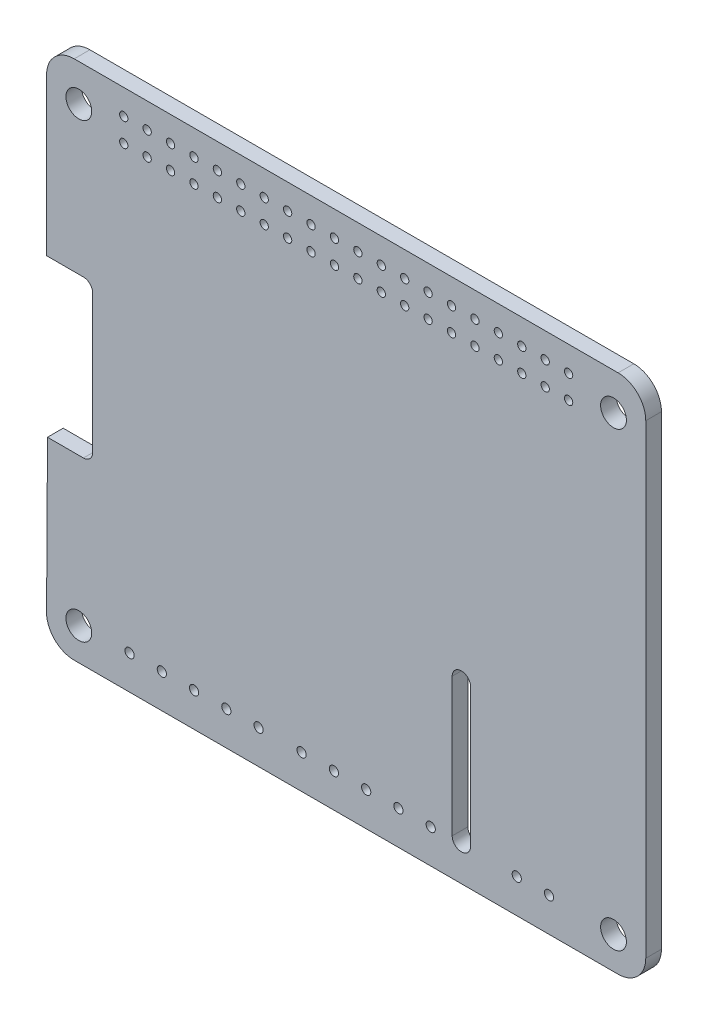
SolidWorks part; units mm, degrees
ref_plane "Front Plane" through (0, 0, 0) normal (0, 0, 1) x (1, 0, 0)
ref_plane "Top Plane" through (0, 0, 0) normal (0, 1, 0) x (1, 0, 0)
ref_plane "Right Plane" through (0, 0, 0) normal (1, 0, 0) x (0, 0, -1)
sketch "Model" plane through (0, 0, 0) normal (0, 0, 1) x (1, 0, 0)
  line L0 (-5.3505, -4.8384) -> (-5.449, -4.812)
  line L1 (-5.252, -5.009) -> (-5.2784, -4.9105)
  line L2 (-5.449, -4.812) -> (-5.5475, -4.8384)
  line L3 (-5.5475, -4.8384) -> (-5.6196, -4.9105)
  line L4 (-5.2784, -4.9105) -> (-5.3505, -4.8384)
  line L5 (-5.646, -5.009) -> (-5.6196, -5.1075)
  line L6 (-5.6196, -5.1075) -> (-5.5475, -5.1796)
  line L7 (-5.5475, -5.1796) -> (-5.449, -5.206)
  line L8 (-5.449, -5.206) -> (-5.3505, -5.1796)
  line L9 (-5.6196, -4.9105) -> (-5.646, -5.009)
  line L10 (-9.2797, 23.205) -> (-9.34, 22.98)
  line L11 (-5.3505, -5.1796) -> (-5.2784, -5.1075)
  line L12 (-5.2784, -5.1075) -> (-5.252, -5.009)
  line L13 (-3.0075, -2.4254) -> (-3.0796, -2.4975)
  line L14 (-9.34, 22.98) -> (-9.2797, 22.755)
  line L15 (22.947, 18.99) -> (22.88, 18.74)
  line L16 (23.13, 19.173) -> (22.947, 18.99)
  line L17 (23.63, 18.307) -> (23.813, 18.49)
  line L18 (23.13, 18.307) -> (23.38, 18.24)
  line L19 (23.38, 18.24) -> (23.63, 18.307)
  line L20 (23.813, 18.49) -> (23.88, 18.74)
  line L21 (19.4397, 25.745) -> (19.275, 25.9097)
  line L22 (19.275, 25.9097) -> (19.05, 25.97)
  line L23 (22.88, 18.74) -> (22.947, 18.49)
  line L24 (19.05, 25.97) -> (18.825, 25.9097)
  line L25 (18.825, 25.9097) -> (18.6603, 25.745)
  line L26 (23.63, 19.173) -> (23.38, 19.24)
  line L27 (22.947, 18.49) -> (23.13, 18.307)
  line L28 (26.42, 18.74) -> (26.353, 18.99)
  line L29 (23.38, 19.24) -> (23.13, 19.173)
  line L30 (23.88, 18.74) -> (23.813, 18.99)
  line L31 (23.813, 18.99) -> (23.63, 19.173)
  line L32 (26.17, 19.173) -> (25.92, 19.24)
  line L33 (25.92, 18.24) -> (26.17, 18.307)
  line L34 (25.67, 19.173) -> (25.487, 18.99)
  line L35 (26.17, 18.307) -> (26.353, 18.49)
  line L36 (26.353, 18.49) -> (26.42, 18.74)
  line L37 (19.275, 22.5903) -> (19.4397, 22.755)
  line L38 (19.4397, 22.755) -> (19.5, 22.98)
  line L39 (26.353, 18.99) -> (26.17, 19.173)
  line L40 (25.67, 18.307) -> (25.92, 18.24)
  line L41 (25.487, 18.49) -> (25.67, 18.307)
  line L42 (25.92, 19.24) -> (25.67, 19.173)
  line L43 (25.487, 18.99) -> (25.42, 18.74)
  line L44 (25.42, 18.74) -> (25.487, 18.49)
  line L45 (19.4397, 23.205) -> (19.275, 23.3697)
  line L46 (19.275, 23.3697) -> (19.05, 23.43)
  line L47 (18.6603, 23.205) -> (18.6, 22.98)
  line L48 (19.05, 22.53) -> (19.275, 22.5903)
  line L49 (18.825, 23.3697) -> (18.6603, 23.205)
  line L50 (18.6, 22.98) -> (18.6603, 22.755)
  line L51 (18.6603, 22.755) -> (18.825, 22.5903)
  line L52 (18.825, 22.5903) -> (19.05, 22.53)
  line L53 (19.5, 25.52) -> (19.4397, 25.745)
  line L54 (19.05, 23.43) -> (18.825, 23.3697)
  line L55 (13.653, 18.99) -> (13.47, 19.173)
  line L56 (12.787, 18.49) -> (12.97, 18.307)
  line L57 (16.193, 18.99) -> (16.01, 19.173)
  line L58 (13.47, 18.307) -> (13.653, 18.49)
  line L59 (12.787, 18.99) -> (12.72, 18.74)
  line L60 (16.26, 18.74) -> (16.193, 18.99)
  line L61 (13.72, 18.74) -> (13.653, 18.99)
  line L62 (13.47, 19.173) -> (13.22, 19.24)
  line L63 (13.22, 18.24) -> (13.47, 18.307)
  line L64 (12.72, 18.74) -> (12.787, 18.49)
  line L65 (12.97, 18.307) -> (13.22, 18.24)
  line L66 (13.22, 19.24) -> (12.97, 19.173)
  line L67 (8.89, 25.97) -> (8.665, 25.9097)
  line L68 (8.5003, 25.295) -> (8.665, 25.1303)
  line L69 (8.665, 25.1303) -> (8.89, 25.07)
  line L70 (8.89, 25.07) -> (9.115, 25.1303)
  line L71 (13.653, 18.49) -> (13.72, 18.74)
  line L72 (8.665, 25.9097) -> (8.5003, 25.745)
  line L73 (9.2797, 25.295) -> (9.34, 25.52)
  line L74 (12.97, 19.173) -> (12.787, 18.99)
  line L75 (9.115, 25.1303) -> (9.2797, 25.295)
  line L76 (8.44, 25.52) -> (8.5003, 25.295)
  line L77 (8.5003, 25.745) -> (8.44, 25.52)
  line L78 (15.76, 18.24) -> (16.01, 18.307)
  line L79 (18.8, 18.74) -> (18.733, 18.99)
  line L80 (15.327, 18.49) -> (15.51, 18.307)
  line L81 (16.01, 19.173) -> (15.76, 19.24)
  line L82 (15.76, 19.24) -> (15.51, 19.173)
  line L83 (15.51, 18.307) -> (15.76, 18.24)
  line L84 (11.655, 22.5903) -> (11.8197, 22.755)
  line L85 (15.51, 19.173) -> (15.327, 18.99)
  line L86 (16.01, 18.307) -> (16.193, 18.49)
  line L87 (11.8197, 22.755) -> (11.88, 22.98)
  line L88 (11.0403, 22.755) -> (11.205, 22.5903)
  line L89 (15.26, 18.74) -> (15.327, 18.49)
  line L90 (11.43, 22.53) -> (11.655, 22.5903)
  line L91 (15.327, 18.99) -> (15.26, 18.74)
  line L92 (9.115, 25.9097) -> (8.89, 25.97)
  line L93 (16.193, 18.49) -> (16.26, 18.74)
  line L94 (11.205, 22.5903) -> (11.43, 22.53)
  line L95 (18.55, 18.307) -> (18.733, 18.49)
  line L96 (18.733, 18.49) -> (18.8, 18.74)
  line L97 (18.3, 19.24) -> (18.05, 19.173)
  line L98 (18.55, 19.173) -> (18.3, 19.24)
  line L99 (17.867, 18.99) -> (17.8, 18.74)
  line L100 (17.867, 18.49) -> (18.05, 18.307)
  line L101 (18.733, 18.99) -> (18.55, 19.173)
  line L102 (18.05, 19.173) -> (17.867, 18.99)
  line L103 (17.8, 18.74) -> (17.867, 18.49)
  line L104 (18.05, 18.307) -> (18.3, 18.24)
  line L105 (18.3, 18.24) -> (18.55, 18.307)
  line L106 (21.34, 18.74) -> (21.273, 18.99)
  line L107 (20.59, 19.173) -> (20.407, 18.99)
  line L108 (21.09, 19.173) -> (20.84, 19.24)
  line L109 (21.273, 18.99) -> (21.09, 19.173)
  line L110 (20.84, 19.24) -> (20.59, 19.173)
  line L111 (21.09, 18.307) -> (21.273, 18.49)
  line L112 (21.273, 18.49) -> (21.34, 18.74)
  line L113 (20.34, 18.74) -> (20.407, 18.49)
  line L114 (20.407, 18.99) -> (20.34, 18.74)
  line L115 (20.84, 18.24) -> (21.09, 18.307)
  line L116 (20.59, 18.307) -> (20.84, 18.24)
  line L117 (20.407, 18.49) -> (20.59, 18.307)
  line L118 (19.5, 22.98) -> (19.4397, 23.205)
  line L119 (-25.313, 14.045) -> (-25.13, 13.862)
  line L120 (-25.13, 13.862) -> (-24.88, 13.795)
  line L121 (-24.88, 13.795) -> (-24.63, 13.862)
  line L122 (-24.88, 14.795) -> (-25.13, 14.728)
  line L123 (-24.63, 14.728) -> (-24.88, 14.795)
  line L124 (-24.38, 14.295) -> (-24.447, 14.545)
  line L125 (-24.447, 14.545) -> (-24.63, 14.728)
  line L126 (-25.313, 14.545) -> (-25.38, 14.295)
  line L127 (-25.13, 14.728) -> (-25.313, 14.545)
  line L128 (-25.38, 14.295) -> (-25.313, 14.045)
  line L129 (27.86, -16.82) -> (27.9404, -17.12)
  line L130 (27.9404, -17.12) -> (28.16, -17.3396)
  line L131 (28.16, -17.3396) -> (28.46, -17.42)
  line L132 (28.46, -17.42) -> (28.76, -17.3396)
  line L133 (28.16, -16.3004) -> (27.9404, -16.52)
  line L134 (28.46, -16.22) -> (28.16, -16.3004)
  line L135 (27.9404, -16.52) -> (27.86, -16.82)
  line L136 (-8.89, 23.43) -> (-9.115, 23.3697)
  line L137 (-24.63, 13.862) -> (-24.447, 14.045)
  line L138 (-9.115, 23.3697) -> (-9.2797, 23.205)
  line L139 (-24.447, 14.045) -> (-24.38, 14.295)
  line L140 (-2.7384, -2.6945) -> (-2.712, -2.596)
  line L141 (-9.115, 22.5903) -> (-8.89, 22.53)
  line L142 (-3.0796, -2.6945) -> (-3.0075, -2.7666)
  line L143 (-2.8105, -2.7666) -> (-2.7384, -2.6945)
  line L144 (-9.2797, 22.755) -> (-9.115, 22.5903)
  line L145 (-3.106, -2.596) -> (-3.0796, -2.6945)
  line L146 (-2.909, -2.793) -> (-2.8105, -2.7666)
  line L147 (-3.0796, -2.4975) -> (-3.106, -2.596)
  line L148 (-3.0075, -2.7666) -> (-2.909, -2.793)
  line L149 (28.9796, -17.12) -> (29.06, -16.82)
  line L150 (28.76, -17.3396) -> (28.9796, -17.12)
  line L151 (-2.7384, -2.4975) -> (-2.8105, -2.4254)
  line L152 (-11.8197, 25.745) -> (-11.88, 25.52)
  line L153 (-11.205, 25.9097) -> (-11.43, 25.97)
  line L154 (-2.712, -2.596) -> (-2.7384, -2.4975)
  line L155 (-11.655, 25.9097) -> (-11.8197, 25.745)
  line L156 (-11.43, 25.97) -> (-11.655, 25.9097)
  line L157 (-11.8197, 25.295) -> (-11.655, 25.1303)
  line L158 (-2.8105, -2.4254) -> (-2.909, -2.399)
  line L159 (-2.909, -2.399) -> (-3.0075, -2.4254)
  line L160 (-11.0403, 25.745) -> (-11.205, 25.9097)
  line L161 (-11.88, 25.52) -> (-11.8197, 25.295)
  line L162 (-19.55, 19.173) -> (-19.8, 19.24)
  line L163 (10.98, 22.98) -> (11.0403, 22.755)
  line L164 (-20.05, 19.173) -> (-20.233, 18.99)
  line L165 (11.43, 23.43) -> (11.205, 23.3697)
  line L166 (-22.09, 18.307) -> (-21.907, 18.49)
  line L167 (-21.907, 18.49) -> (-21.84, 18.74)
  line L168 (-19.8, 19.24) -> (-20.05, 19.173)
  line L169 (-19.367, 18.99) -> (-19.55, 19.173)
  line L170 (-22.34, 18.24) -> (-22.09, 18.307)
  line L171 (-19.3, 18.74) -> (-19.367, 18.99)
  line L172 (-20.233, 18.49) -> (-20.05, 18.307)
  line L173 (-19.367, 18.49) -> (-19.3, 18.74)
  line L174 (11.8197, 23.205) -> (11.655, 23.3697)
  line L175 (-14.287, 18.99) -> (-14.47, 19.173)
  line L176 (-22.59, 18.307) -> (-22.34, 18.24)
  line L177 (11.655, 23.3697) -> (11.43, 23.43)
  line L178 (-19.55, 18.307) -> (-19.367, 18.49)
  line L179 (-20.233, 18.99) -> (-20.3, 18.74)
  line L180 (11.88, 22.98) -> (11.8197, 23.205)
  line L181 (-20.05, 18.307) -> (-19.8, 18.24)
  line L182 (11.205, 23.3697) -> (11.0403, 23.205)
  line L183 (11.0403, 23.205) -> (10.98, 22.98)
  line L184 (-19.8, 18.24) -> (-19.55, 18.307)
  line L185 (-20.3, 18.74) -> (-20.233, 18.49)
  line L186 (-22.773, 18.99) -> (-22.84, 18.74)
  line L187 (-22.84, 18.74) -> (-22.773, 18.49)
  line L188 (-22.773, 18.49) -> (-22.59, 18.307)
  line L189 (-22.59, 19.173) -> (-22.773, 18.99)
  line L190 (-21.84, 18.74) -> (-21.907, 18.99)
  line L191 (-21.907, 18.99) -> (-22.09, 19.173)
  line L192 (-22.09, 19.173) -> (-22.34, 19.24)
  line L193 (-22.34, 19.24) -> (-22.59, 19.173)
  line L194 (-14.287, 18.49) -> (-14.22, 18.74)
  line L195 (-15.153, 18.49) -> (-14.97, 18.307)
  line L196 (-14.72, 19.24) -> (-14.97, 19.173)
  line L197 (-14.47, 19.173) -> (-14.72, 19.24)
  line L198 (-15.153, 18.99) -> (-15.22, 18.74)
  line L199 (6.7397, 25.295) -> (6.8, 25.52)
  line L200 (-14.72, 18.24) -> (-14.47, 18.307)
  line L201 (-14.97, 18.307) -> (-14.72, 18.24)
  line L202 (-14.47, 18.307) -> (-14.287, 18.49)
  line L203 (-15.22, 18.74) -> (-15.153, 18.49)
  line L204 (-14.97, 19.173) -> (-15.153, 18.99)
  line L205 (-11.68, 18.74) -> (-11.747, 18.99)
  line L206 (-14.22, 18.74) -> (-14.287, 18.99)
  line L207 (6.575, 25.1303) -> (6.7397, 25.295)
  line L208 (-11.93, 18.307) -> (-11.747, 18.49)
  line L209 (-12.68, 18.74) -> (-12.613, 18.49)
  line L210 (-11.747, 18.49) -> (-11.68, 18.74)
  line L211 (9.34, 22.98) -> (9.2797, 23.205)
  line L212 (-12.43, 19.173) -> (-12.613, 18.99)
  line L213 (8.5003, 23.205) -> (8.44, 22.98)
  line L214 (-12.613, 18.99) -> (-12.68, 18.74)
  line L215 (-12.18, 18.24) -> (-11.93, 18.307)
  line L216 (8.89, 23.43) -> (8.665, 23.3697)
  line L217 (-12.43, 18.307) -> (-12.18, 18.24)
  line L218 (-12.613, 18.49) -> (-12.43, 18.307)
  line L219 (-12.18, 19.24) -> (-12.43, 19.173)
  line L220 (8.44, 22.98) -> (8.5003, 22.755)
  line L221 (-11.747, 18.99) -> (-11.93, 19.173)
  line L222 (9.2797, 23.205) -> (9.115, 23.3697)
  line L223 (-9.14, 18.74) -> (-9.207, 18.99)
  line L224 (-11.93, 19.173) -> (-12.18, 19.24)
  line L225 (9.115, 23.3697) -> (8.89, 23.43)
  line L226 (8.5003, 22.755) -> (8.665, 22.5903)
  line L227 (8.89, 22.53) -> (9.115, 22.5903)
  line L228 (9.115, 22.5903) -> (9.2797, 22.755)
  line L229 (9.2797, 22.755) -> (9.34, 22.98)
  line L230 (8.665, 23.3697) -> (8.5003, 23.205)
  line L231 (8.665, 22.5903) -> (8.89, 22.53)
  line L232 (6.125, 25.1303) -> (6.35, 25.07)
  line L233 (-9.64, 19.24) -> (-9.89, 19.173)
  line L234 (-9.39, 18.307) -> (-9.207, 18.49)
  line L235 (-9.89, 19.173) -> (-10.073, 18.99)
  line L236 (-10.14, 18.74) -> (-10.073, 18.49)
  line L237 (6.35, 25.07) -> (6.575, 25.1303)
  line L238 (-9.207, 18.99) -> (-9.39, 19.173)
  line L239 (-10.073, 18.49) -> (-9.89, 18.307)
  line L240 (5.9, 25.52) -> (5.9603, 25.295)
  line L241 (-9.89, 18.307) -> (-9.64, 18.24)
  line L242 (-9.64, 18.24) -> (-9.39, 18.307)
  line L243 (-9.39, 19.173) -> (-9.64, 19.24)
  line L244 (-10.073, 18.99) -> (-10.14, 18.74)
  line L245 (-9.207, 18.49) -> (-9.14, 18.74)
  line L246 (5.9603, 25.745) -> (5.9, 25.52)
  line L247 (5.9603, 25.295) -> (6.125, 25.1303)
  line L248 (-7.6, 18.74) -> (-7.533, 18.49)
  line L249 (6.125, 23.3697) -> (5.9603, 23.205)
  line L250 (-4.81, 18.307) -> (-4.56, 18.24)
  line L251 (-4.81, 19.173) -> (-4.993, 18.99)
  line L252 (6.7397, 23.205) -> (6.575, 23.3697)
  line L253 (-4.56, 18.24) -> (-4.31, 18.307)
  line L254 (6.35, 23.43) -> (6.125, 23.3697)
  line L255 (-4.127, 18.99) -> (-4.31, 19.173)
  line L256 (5.9603, 22.755) -> (6.125, 22.5903)
  line L257 (-7.1, 18.24) -> (-6.85, 18.307)
  line L258 (-6.85, 18.307) -> (-6.667, 18.49)
  line L259 (-7.533, 18.49) -> (-7.35, 18.307)
  line L260 (6.575, 23.3697) -> (6.35, 23.43)
  line L261 (-4.127, 18.49) -> (-4.06, 18.74)
  line L262 (-6.667, 18.49) -> (-6.6, 18.74)
  line L263 (6.125, 22.5903) -> (6.35, 22.53)
  line L264 (-4.06, 18.74) -> (-4.127, 18.99)
  line L265 (-4.31, 19.173) -> (-4.56, 19.24)
  line L266 (-5.06, 18.74) -> (-4.993, 18.49)
  line L267 (-1.52, 18.74) -> (-1.587, 18.99)
  line L268 (-7.35, 18.307) -> (-7.1, 18.24)
  line L269 (-4.56, 19.24) -> (-4.81, 19.173)
  line L270 (-4.993, 18.99) -> (-5.06, 18.74)
  line L271 (-4.31, 18.307) -> (-4.127, 18.49)
  line L272 (5.9603, 23.205) -> (5.9, 22.98)
  line L273 (-4.993, 18.49) -> (-4.81, 18.307)
  line L274 (5.9, 22.98) -> (5.9603, 22.755)
  line L275 (6.35, 22.53) -> (6.575, 22.5903)
  line L276 (6.575, 22.5903) -> (6.7397, 22.755)
  line L277 (-2.27, 18.307) -> (-2.02, 18.24)
  line L278 (-2.02, 19.24) -> (-2.27, 19.173)
  line L279 (-1.587, 18.99) -> (-1.77, 19.173)
  line L280 (-1.77, 19.173) -> (-2.02, 19.24)
  line L281 (-2.27, 19.173) -> (-2.453, 18.99)
  line L282 (-1.77, 18.307) -> (-1.587, 18.49)
  line L283 (-2.02, 18.24) -> (-1.77, 18.307)
  line L284 (6.8, 22.98) -> (6.7397, 23.205)
  line L285 (-2.52, 18.74) -> (-2.453, 18.49)
  line L286 (-1.587, 18.49) -> (-1.52, 18.74)
  line L287 (-2.453, 18.49) -> (-2.27, 18.307)
  line L288 (6.7397, 22.755) -> (6.8, 22.98)
  line L289 (-2.453, 18.99) -> (-2.52, 18.74)
  line L290 (-6.85, 19.173) -> (-7.1, 19.24)
  line L291 (-6.6, 18.74) -> (-6.667, 18.99)
  line L292 (-7.1, 19.24) -> (-7.35, 19.173)
  line L293 (-6.667, 18.99) -> (-6.85, 19.173)
  line L294 (-7.533, 18.99) -> (-7.6, 18.74)
  line L295 (-7.35, 19.173) -> (-7.533, 18.99)
  line L296 (0.77, 18.307) -> (0.953, 18.49)
  line L297 (0.953, 18.49) -> (1.02, 18.74)
  line L298 (0.953, 18.99) -> (0.77, 19.173)
  line L299 (0.77, 19.173) -> (0.52, 19.24)
  line L300 (0.27, 19.173) -> (0.087, 18.99)
  line L301 (0.27, 18.307) -> (0.52, 18.24)
  line L302 (3.56, 18.74) -> (3.493, 18.99)
  line L303 (0.52, 19.24) -> (0.27, 19.173)
  line L304 (1.02, 18.74) -> (0.953, 18.99)
  line L305 (6.125, 25.9097) -> (5.9603, 25.745)
  line L306 (0.087, 18.99) -> (0.02, 18.74)
  line L307 (6.35, 25.97) -> (6.125, 25.9097)
  line L308 (0.02, 18.74) -> (0.087, 18.49)
  line L309 (0.087, 18.49) -> (0.27, 18.307)
  line L310 (0.52, 18.24) -> (0.77, 18.307)
  line L311 (6.7397, 25.745) -> (6.575, 25.9097)
  line L312 (2.81, 18.307) -> (3.06, 18.24)
  line L313 (3.493, 18.49) -> (3.56, 18.74)
  line L314 (6.575, 25.9097) -> (6.35, 25.97)
  line L315 (6.8, 25.52) -> (6.7397, 25.745)
  line L316 (3.06, 19.24) -> (2.81, 19.173)
  line L317 (2.627, 18.99) -> (2.56, 18.74)
  line L318 (3.31, 19.173) -> (3.06, 19.24)
  line L319 (3.493, 18.99) -> (3.31, 19.173)
  line L320 (2.627, 18.49) -> (2.81, 18.307)
  line L321 (3.06, 18.24) -> (3.31, 18.307)
  line L322 (2.56, 18.74) -> (2.627, 18.49)
  line L323 (3.31, 18.307) -> (3.493, 18.49)
  line L324 (6.1, 18.74) -> (6.033, 18.99)
  line L325 (2.81, 19.173) -> (2.627, 18.99)
  line L326 (5.6, 19.24) -> (5.35, 19.173)
  line L327 (6.033, 18.99) -> (5.85, 19.173)
  line L328 (5.35, 18.307) -> (5.6, 18.24)
  line L329 (5.6, 18.24) -> (5.85, 18.307)
  line L330 (6.033, 18.49) -> (6.1, 18.74)
  line L331 (5.85, 19.173) -> (5.6, 19.24)
  line L332 (5.35, 19.173) -> (5.167, 18.99)
  line L333 (5.1, 18.74) -> (5.167, 18.49)
  line L334 (5.167, 18.99) -> (5.1, 18.74)
  line L335 (5.167, 18.49) -> (5.35, 18.307)
  line L336 (5.85, 18.307) -> (6.033, 18.49)
  line L337 (10.43, 19.173) -> (10.247, 18.99)
  line L338 (10.247, 18.99) -> (10.18, 18.74)
  line L339 (10.18, 18.74) -> (10.247, 18.49)
  line L340 (8.39, 19.173) -> (8.14, 19.24)
  line L341 (8.573, 18.49) -> (8.64, 18.74)
  line L342 (7.89, 18.307) -> (8.14, 18.24)
  line L343 (8.14, 18.24) -> (8.39, 18.307)
  line L344 (7.707, 18.49) -> (7.89, 18.307)
  line L345 (8.64, 18.74) -> (8.573, 18.99)
  line L346 (11.18, 18.74) -> (11.113, 18.99)
  line L347 (11.113, 18.99) -> (10.93, 19.173)
  line L348 (8.573, 18.99) -> (8.39, 19.173)
  line L349 (8.39, 18.307) -> (8.573, 18.49)
  line L350 (8.14, 19.24) -> (7.89, 19.173)
  line L351 (7.89, 19.173) -> (7.707, 18.99)
  line L352 (10.93, 19.173) -> (10.68, 19.24)
  line L353 (10.68, 19.24) -> (10.43, 19.173)
  line L354 (7.64, 18.74) -> (7.707, 18.49)
  line L355 (7.707, 18.99) -> (7.64, 18.74)
  line L356 (10.93, 18.307) -> (11.113, 18.49)
  line L357 (10.247, 18.49) -> (10.43, 18.307)
  line L358 (10.43, 18.307) -> (10.68, 18.24)
  line L359 (11.113, 18.49) -> (11.18, 18.74)
  line L360 (10.68, 18.24) -> (10.93, 18.307)
  line L361 (9.34, 25.52) -> (9.2797, 25.745)
  line L362 (-16.498, -24.067) -> (-16.748, -24.134)
  line L363 (-16.498, -25.067) -> (-16.248, -25)
  line L364 (-16.748, -24.134) -> (-16.931, -24.317)
  line L365 (-19.565, -24.317) -> (-19.748, -24.134)
  line L366 (-20.431, -24.317) -> (-20.498, -24.567)
  line L367 (-20.431, -24.817) -> (-20.248, -25)
  line L368 (-19.998, -25.067) -> (-19.748, -25)
  line L369 (-19.565, -24.817) -> (-19.498, -24.567)
  line L370 (-4.396, -24.317) -> (-4.579, -24.134)
  line L371 (-19.748, -24.134) -> (-19.998, -24.067)
  line L372 (-20.498, -24.567) -> (-20.431, -24.817)
  line L373 (-20.248, -25) -> (-19.998, -25.067)
  line L374 (-19.748, -25) -> (-19.565, -24.817)
  line L375 (-19.498, -24.567) -> (-19.565, -24.317)
  line L376 (-19.998, -24.067) -> (-20.248, -24.134)
  line L377 (-16.998, -24.567) -> (-16.931, -24.817)
  line L378 (-16.248, -25) -> (-16.065, -24.817)
  line L379 (-16.748, -25) -> (-16.498, -25.067)
  line L380 (-16.248, -24.134) -> (-16.498, -24.067)
  line L381 (-16.931, -24.317) -> (-16.998, -24.567)
  line L382 (-16.065, -24.817) -> (-15.998, -24.567)
  line L383 (-16.931, -24.817) -> (-16.748, -25)
  line L384 (-20.248, -24.134) -> (-20.431, -24.317)
  line L385 (18.6, 25.52) -> (18.6603, 25.295)
  line L386 (28.46, 18.24) -> (28.71, 18.307)
  line L387 (28.893, 18.99) -> (28.71, 19.173)
  line L388 (18.6603, 25.295) -> (18.825, 25.1303)
  line L389 (28.46, 19.24) -> (28.21, 19.173)
  line L390 (28.027, 18.99) -> (27.96, 18.74)
  line L391 (28.21, 18.307) -> (28.46, 18.24)
  line L392 (28.71, 18.307) -> (28.893, 18.49)
  line L393 (18.6603, 25.745) -> (18.6, 25.52)
  line L394 (28.96, 18.74) -> (28.893, 18.99)
  line L395 (28.21, 19.173) -> (28.027, 18.99)
  line L396 (28.893, 18.49) -> (28.96, 18.74)
  line L397 (28.71, 19.173) -> (28.46, 19.24)
  line L398 (28.027, 18.49) -> (28.21, 18.307)
  line L399 (27.96, 18.74) -> (28.027, 18.49)
  line L400 (31.5, 18.74) -> (31.433, 18.99)
  line L401 (30.567, 18.99) -> (30.5, 18.74)
  line L402 (31.433, 18.99) -> (31.25, 19.173)
  line L403 (-8.998, -24.567) -> (-9.065, -24.317)
  line L404 (31, 19.24) -> (30.75, 19.173)
  line L405 (30.75, 19.173) -> (30.567, 18.99)
  line L406 (31, 18.24) -> (31.25, 18.307)
  line L407 (31.25, 19.173) -> (31, 19.24)
  line L408 (30.5, 18.74) -> (30.567, 18.49)
  line L409 (30.75, 18.307) -> (31, 18.24)
  line L410 (19.275, 25.1303) -> (19.4397, 25.295)
  line L411 (31.433, 18.49) -> (31.5, 18.74)
  line L412 (19.4397, 25.295) -> (19.5, 25.52)
  line L413 (18.825, 25.1303) -> (19.05, 25.07)
  line L414 (30.567, 18.49) -> (30.75, 18.307)
  line L415 (19.05, 25.07) -> (19.275, 25.1303)
  line L416 (31.25, 18.307) -> (31.433, 18.49)
  line L417 (-9.065, -24.817) -> (-8.998, -24.567)
  line L418 (-9.248, -24.134) -> (-9.498, -24.067)
  line L419 (-9.498, -25.067) -> (-9.248, -25)
  line L420 (-9.931, -24.817) -> (-9.748, -25)
  line L421 (-9.498, -24.067) -> (-9.748, -24.134)
  line L422 (-9.931, -24.317) -> (-9.998, -24.567)
  line L423 (-9.065, -24.317) -> (-9.248, -24.134)
  line L424 (-9.748, -25) -> (-9.498, -25.067)
  line L425 (-9.748, -24.134) -> (-9.931, -24.317)
  line L426 (-9.998, -24.567) -> (-9.931, -24.817)
  line L427 (-9.248, -25) -> (-9.065, -24.817)
  line L428 (-12.498, -24.567) -> (-12.565, -24.317)
  line L429 (-12.565, -24.317) -> (-12.748, -24.134)
  line L430 (-12.998, -24.067) -> (-13.248, -24.134)
  line L431 (-12.565, -24.817) -> (-12.498, -24.567)
  line L432 (-12.748, -24.134) -> (-12.998, -24.067)
  line L433 (-15.998, -24.567) -> (-16.065, -24.317)
  line L434 (-13.248, -24.134) -> (-13.431, -24.317)
  line L435 (-13.498, -24.567) -> (-13.431, -24.817)
  line L436 (22.04, 22.98) -> (21.9797, 23.205)
  line L437 (-13.431, -24.817) -> (-13.248, -25)
  line L438 (-12.998, -25.067) -> (-12.748, -25)
  line L439 (-13.248, -25) -> (-12.998, -25.067)
  line L440 (-13.431, -24.317) -> (-13.498, -24.567)
  line L441 (21.9797, 23.205) -> (21.815, 23.3697)
  line L442 (21.815, 23.3697) -> (21.59, 23.43)
  line L443 (-12.748, -25) -> (-12.565, -24.817)
  line L444 (21.2003, 22.755) -> (21.365, 22.5903)
  line L445 (21.365, 22.5903) -> (21.59, 22.53)
  line L446 (21.9797, 22.755) -> (22.04, 22.98)
  line L447 (-16.065, -24.317) -> (-16.248, -24.134)
  line L448 (21.2003, 23.205) -> (21.14, 22.98)
  line L449 (21.14, 22.98) -> (21.2003, 22.755)
  line L450 (21.59, 22.53) -> (21.815, 22.5903)
  line L451 (21.815, 22.5903) -> (21.9797, 22.755)
  line L452 (21.59, 23.43) -> (21.365, 23.3697)
  line L453 (21.365, 23.3697) -> (21.2003, 23.205)
  line L454 (-23.931, -24.817) -> (-23.748, -25)
  line L455 (-23.498, -25.067) -> (-23.248, -25)
  line L456 (-22.998, -24.567) -> (-23.065, -24.317)
  line L457 (-23.498, -24.067) -> (-23.748, -24.134)
  line L458 (-23.248, -24.134) -> (-23.498, -24.067)
  line L459 (-23.748, -24.134) -> (-23.931, -24.317)
  line L460 (-23.998, -24.567) -> (-23.931, -24.817)
  line L461 (-23.748, -25) -> (-23.498, -25.067)
  line L462 (-23.065, -24.817) -> (-22.998, -24.567)
  line L463 (-23.248, -25) -> (-23.065, -24.817)
  line L464 (-23.931, -24.317) -> (-23.998, -24.567)
  line L465 (-23.065, -24.317) -> (-23.248, -24.134)
  line L466 (9.671, -24.567) -> (9.604, -24.317)
  line L467 (8.738, -24.317) -> (8.671, -24.567)
  line L468 (8.671, -24.567) -> (8.738, -24.817)
  line L469 (8.738, -24.817) -> (8.921, -25)
  line L470 (8.921, -25) -> (9.171, -25.067)
  line L471 (9.604, -24.817) -> (9.671, -24.567)
  line L472 (6.171, -24.567) -> (6.104, -24.317)
  line L473 (9.171, -24.067) -> (8.921, -24.134)
  line L474 (9.171, -25.067) -> (9.421, -25)
  line L475 (9.421, -25) -> (9.604, -24.817)
  line L476 (9.421, -24.134) -> (9.171, -24.067)
  line L477 (9.604, -24.317) -> (9.421, -24.134)
  line L478 (8.921, -24.134) -> (8.738, -24.317)
  line L479 (2.671, -24.567) -> (2.604, -24.317)
  line L480 (6.104, -24.317) -> (5.921, -24.134)
  line L481 (5.671, -24.067) -> (5.421, -24.134)
  line L482 (5.171, -24.567) -> (5.238, -24.817)
  line L483 (5.238, -24.817) -> (5.421, -25)
  line L484 (5.421, -25) -> (5.671, -25.067)
  line L485 (5.238, -24.317) -> (5.171, -24.567)
  line L486 (5.921, -24.134) -> (5.671, -24.067)
  line L487 (5.671, -25.067) -> (5.921, -25)
  line L488 (5.921, -25) -> (6.104, -24.817)
  line L489 (6.104, -24.817) -> (6.171, -24.567)
  line L490 (5.421, -24.134) -> (5.238, -24.317)
  line L491 (2.604, -24.817) -> (2.671, -24.567)
  line L492 (2.604, -24.317) -> (2.421, -24.134)
  line L493 (-0.829, -24.567) -> (-0.896, -24.317)
  line L494 (1.921, -24.134) -> (1.738, -24.317)
  line L495 (1.738, -24.317) -> (1.671, -24.567)
  line L496 (2.421, -24.134) -> (2.171, -24.067)
  line L497 (2.171, -24.067) -> (1.921, -24.134)
  line L498 (1.671, -24.567) -> (1.738, -24.817)
  line L499 (1.738, -24.817) -> (1.921, -25)
  line L500 (1.921, -25) -> (2.171, -25.067)
  line L501 (2.171, -25.067) -> (2.421, -25)
  line L502 (2.421, -25) -> (2.604, -24.817)
  line L503 (-1.079, -24.134) -> (-1.329, -24.067)
  line L504 (-1.329, -24.067) -> (-1.579, -24.134)
  line L505 (-1.579, -24.134) -> (-1.762, -24.317)
  line L506 (-1.762, -24.317) -> (-1.829, -24.567)
  line L507 (-1.329, -25.067) -> (-1.079, -25)
  line L508 (-1.079, -25) -> (-0.896, -24.817)
  line L509 (-0.896, -24.817) -> (-0.829, -24.567)
  line L510 (-0.896, -24.317) -> (-1.079, -24.134)
  line L511 (-1.579, -25) -> (-1.329, -25.067)
  line L512 (-4.329, -24.567) -> (-4.396, -24.317)
  line L513 (-1.762, -24.817) -> (-1.579, -25)
  line L514 (-1.829, -24.567) -> (-1.762, -24.817)
  line L515 (-4.31, 3.933) -> (-4.56, 4)
  line L516 (-4.993, 3.25) -> (-4.81, 3.067)
  line L517 (-4.56, 3) -> (-4.31, 3.067)
  line L518 (-6.6, 3.5) -> (-6.667, 3.75)
  line L519 (-4.31, 3.067) -> (-4.127, 3.25)
  line L520 (-5.06, 3.5) -> (-4.993, 3.25)
  line L521 (-4.06, 3.5) -> (-4.127, 3.75)
  line L522 (-4.81, 3.067) -> (-4.56, 3)
  line L523 (-4.127, 3.75) -> (-4.31, 3.933)
  line L524 (-6.667, 3.75) -> (-6.85, 3.933)
  line L525 (-6.85, 3.933) -> (-7.1, 4)
  line L526 (-4.127, 3.25) -> (-4.06, 3.5)
  line L527 (-4.56, 4) -> (-4.81, 3.933)
  line L528 (-4.993, 3.75) -> (-5.06, 3.5)
  line L529 (-4.81, 3.933) -> (-4.993, 3.75)
  line L530 (-7.6, 3.5) -> (-7.533, 3.25)
  line L531 (-7.35, 3.067) -> (-7.1, 3)
  line L532 (-6.85, 3.067) -> (-6.667, 3.25)
  line L533 (-7.35, 3.933) -> (-7.533, 3.75)
  line L534 (-7.1, 3) -> (-6.85, 3.067)
  line L535 (-7.1, 4) -> (-7.35, 3.933)
  line L536 (-9.14, 3.5) -> (-9.207, 3.75)
  line L537 (-7.533, 3.75) -> (-7.6, 3.5)
  line L538 (-6.667, 3.25) -> (-6.6, 3.5)
  line L539 (-7.533, 3.25) -> (-7.35, 3.067)
  line L540 (-9.89, 3.067) -> (-9.64, 3)
  line L541 (-9.39, 3.067) -> (-9.207, 3.25)
  line L542 (-9.207, 3.25) -> (-9.14, 3.5)
  line L543 (-9.89, 3.933) -> (-10.073, 3.75)
  line L544 (-10.073, 3.75) -> (-10.14, 3.5)
  line L545 (-9.39, 3.933) -> (-9.64, 4)
  line L546 (-10.14, 3.5) -> (-10.073, 3.25)
  line L547 (-9.64, 4) -> (-9.89, 3.933)
  line L548 (-10.073, 3.25) -> (-9.89, 3.067)
  line L549 (-9.64, 3) -> (-9.39, 3.067)
  line L550 (22.505, -24.567) -> (22.438, -24.317)
  line L551 (-9.207, 3.75) -> (-9.39, 3.933)
  line L552 (22.438, -24.317) -> (22.255, -24.134)
  line L553 (22.255, -25) -> (22.438, -24.817)
  line L554 (21.755, -25) -> (22.005, -25.067)
  line L555 (21.572, -24.317) -> (21.505, -24.567)
  line L556 (22.005, -25.067) -> (22.255, -25)
  line L557 (22.438, -24.817) -> (22.505, -24.567)
  line L558 (22.255, -24.134) -> (22.005, -24.067)
  line L559 (21.505, -24.567) -> (21.572, -24.817)
  line L560 (22.005, -24.067) -> (21.755, -24.134)
  line L561 (21.755, -24.134) -> (21.572, -24.317)
  line L562 (21.572, -24.817) -> (21.755, -25)
  line L563 (-5.262, -24.817) -> (-5.079, -25)
  line L564 (-5.079, -25) -> (-4.829, -25.067)
  line L565 (-4.829, -24.067) -> (-5.079, -24.134)
  line L566 (-4.579, -24.134) -> (-4.829, -24.067)
  line L567 (-5.079, -24.134) -> (-5.262, -24.317)
  line L568 (-5.329, -24.567) -> (-5.262, -24.817)
  line L569 (-1.52, 3.5) -> (-1.587, 3.75)
  line L570 (-4.829, -25.067) -> (-4.579, -25)
  line L571 (-5.262, -24.317) -> (-5.329, -24.567)
  line L572 (-4.579, -25) -> (-4.396, -24.817)
  line L573 (-4.396, -24.817) -> (-4.329, -24.567)
  line L574 (-2.52, 3.5) -> (-2.453, 3.25)
  line L575 (-2.02, 3) -> (-1.77, 3.067)
  line L576 (-2.27, 3.067) -> (-2.02, 3)
  line L577 (-1.77, 3.933) -> (-2.02, 4)
  line L578 (-2.453, 3.25) -> (-2.27, 3.067)
  line L579 (-1.77, 3.067) -> (-1.587, 3.25)
  line L580 (-1.587, 3.75) -> (-1.77, 3.933)
  line L581 (-2.02, 4) -> (-2.27, 3.933)
  line L582 (-2.27, 3.933) -> (-2.453, 3.75)
  line L583 (-2.453, 3.75) -> (-2.52, 3.5)
  line L584 (-1.587, 3.25) -> (-1.52, 3.5)
  line L585 (-13.52, 22.98) -> (-13.5803, 23.205)
  line L586 (-13.5803, 23.205) -> (-13.745, 23.3697)
  line L587 (-13.97, 23.43) -> (-14.195, 23.3697)
  line L588 (-14.195, 23.3697) -> (-14.3597, 23.205)
  line L589 (-16.8997, 25.295) -> (-16.735, 25.1303)
  line L590 (-16.51, 25.07) -> (-16.285, 25.1303)
  line L591 (-16.285, 25.9097) -> (-16.51, 25.97)
  line L592 (-16.1203, 25.295) -> (-16.06, 25.52)
  line L593 (-16.1203, 25.745) -> (-16.285, 25.9097)
  line L594 (-16.735, 25.9097) -> (-16.8997, 25.745)
  line L595 (-16.96, 25.52) -> (-16.8997, 25.295)
  line L596 (-16.06, 25.52) -> (-16.1203, 25.745)
  line L597 (-13.745, 23.3697) -> (-13.97, 23.43)
  line L598 (-16.285, 25.1303) -> (-16.1203, 25.295)
  line L599 (-16.735, 25.1303) -> (-16.51, 25.07)
  line L600 (-16.8997, 25.745) -> (-16.96, 25.52)
  line L601 (-16.51, 25.97) -> (-16.735, 25.9097)
  line L602 (-13.52, 25.52) -> (-13.5803, 25.745)
  line L603 (-13.745, 22.5903) -> (-13.5803, 22.755)
  line L604 (-14.3597, 23.205) -> (-14.42, 22.98)
  line L605 (-14.3597, 22.755) -> (-14.195, 22.5903)
  line L606 (-13.5803, 25.745) -> (-13.745, 25.9097)
  line L607 (-14.42, 22.98) -> (-14.3597, 22.755)
  line L608 (-14.195, 22.5903) -> (-13.97, 22.53)
  line L609 (-13.97, 22.53) -> (-13.745, 22.5903)
  line L610 (-13.5803, 22.755) -> (-13.52, 22.98)
  line L611 (-13.97, 25.07) -> (-13.745, 25.1303)
  line L612 (-14.3597, 25.745) -> (-14.42, 25.52)
  line L613 (-13.5803, 25.295) -> (-13.52, 25.52)
  line L614 (-14.195, 25.9097) -> (-14.3597, 25.745)
  line L615 (-14.42, 25.52) -> (-14.3597, 25.295)
  line L616 (-13.745, 25.9097) -> (-13.97, 25.97)
  line L617 (-13.745, 25.1303) -> (-13.5803, 25.295)
  line L618 (-13.97, 25.97) -> (-14.195, 25.9097)
  line L619 (-14.195, 25.1303) -> (-13.97, 25.07)
  line L620 (-14.3597, 25.295) -> (-14.195, 25.1303)
  line L621 (18.255, -24.134) -> (18.072, -24.317)
  line L622 (18.938, -24.817) -> (19.005, -24.567)
  line L623 (18.255, -25) -> (18.505, -25.067)
  line L624 (-23.68, 22.98) -> (-23.7403, 23.205)
  line L625 (18.072, -24.317) -> (18.005, -24.567)
  line L626 (18.755, -24.134) -> (18.505, -24.067)
  line L627 (18.938, -24.317) -> (18.755, -24.134)
  line L628 (18.505, -25.067) -> (18.755, -25)
  line L629 (19.005, -24.567) -> (18.938, -24.317)
  line L630 (18.005, -24.567) -> (18.072, -24.817)
  line L631 (18.072, -24.817) -> (18.255, -25)
  line L632 (18.755, -25) -> (18.938, -24.817)
  line L633 (18.505, -24.067) -> (18.255, -24.134)
  line L634 (-24.5197, 23.205) -> (-24.58, 22.98)
  line L635 (-24.355, 22.5903) -> (-24.13, 22.53)
  line L636 (-23.68, 25.52) -> (-23.7403, 25.745)
  line L637 (-24.13, 23.43) -> (-24.355, 23.3697)
  line L638 (-23.7403, 23.205) -> (-23.905, 23.3697)
  line L639 (-24.5197, 22.755) -> (-24.355, 22.5903)
  line L640 (-23.905, 23.3697) -> (-24.13, 23.43)
  line L641 (-24.13, 22.53) -> (-23.905, 22.5903)
  line L642 (-24.58, 22.98) -> (-24.5197, 22.755)
  line L643 (-23.905, 22.5903) -> (-23.7403, 22.755)
  line L644 (-24.355, 23.3697) -> (-24.5197, 23.205)
  line L645 (-23.7403, 22.755) -> (-23.68, 22.98)
  line L646 (-24.13, 25.97) -> (-24.355, 25.9097)
  line L647 (-23.905, 25.9097) -> (-24.13, 25.97)
  line L648 (-24.355, 25.9097) -> (-24.5197, 25.745)
  line L649 (-24.5197, 25.295) -> (-24.355, 25.1303)
  line L650 (-24.355, 25.1303) -> (-24.13, 25.07)
  line L651 (-24.5197, 25.745) -> (-24.58, 25.52)
  line L652 (-24.13, 25.07) -> (-23.905, 25.1303)
  line L653 (-23.905, 25.1303) -> (-23.7403, 25.295)
  line L654 (-24.58, 25.52) -> (-24.5197, 25.295)
  line L655 (-21.14, 22.98) -> (-21.2003, 23.205)
  line L656 (-23.7403, 25.745) -> (-23.905, 25.9097)
  line L657 (-23.7403, 25.295) -> (-23.68, 25.52)
  line L658 (-21.2003, 23.205) -> (-21.365, 23.3697)
  line L659 (-21.59, 23.43) -> (-21.815, 23.3697)
  line L660 (-21.815, 22.5903) -> (-21.59, 22.53)
  line L661 (-21.9797, 23.205) -> (-22.04, 22.98)
  line L662 (-21.59, 22.53) -> (-21.365, 22.5903)
  line L663 (-21.14, 25.52) -> (-21.2003, 25.745)
  line L664 (-21.365, 22.5903) -> (-21.2003, 22.755)
  line L665 (-21.365, 23.3697) -> (-21.59, 23.43)
  line L666 (-21.9797, 22.755) -> (-21.815, 22.5903)
  line L667 (-21.815, 23.3697) -> (-21.9797, 23.205)
  line L668 (-21.2003, 22.755) -> (-21.14, 22.98)
  line L669 (-22.04, 22.98) -> (-21.9797, 22.755)
  line L670 (-21.2003, 25.745) -> (-21.365, 25.9097)
  line L671 (-21.365, 25.9097) -> (-21.59, 25.97)
  line L672 (-21.59, 25.97) -> (-21.815, 25.9097)
  line L673 (-21.815, 25.9097) -> (-21.9797, 25.745)
  line L674 (-21.9797, 25.745) -> (-22.04, 25.52)
  line L675 (-22.04, 25.52) -> (-21.9797, 25.295)
  line L676 (-21.815, 25.1303) -> (-21.59, 25.07)
  line L677 (-21.2003, 25.295) -> (-21.14, 25.52)
  line L678 (-21.9797, 25.295) -> (-21.815, 25.1303)
  line L679 (-18.6, 22.98) -> (-18.6603, 23.205)
  line L680 (-21.59, 25.07) -> (-21.365, 25.1303)
  line L681 (-21.365, 25.1303) -> (-21.2003, 25.295)
  line L682 (-19.05, 23.43) -> (-19.275, 23.3697)
  line L683 (-19.275, 23.3697) -> (-19.4397, 23.205)
  line L684 (-19.4397, 23.205) -> (-19.5, 22.98)
  line L685 (-18.6603, 23.205) -> (-18.825, 23.3697)
  line L686 (-18.6603, 22.755) -> (-18.6, 22.98)
  line L687 (-18.825, 22.5903) -> (-18.6603, 22.755)
  line L688 (-19.5, 22.98) -> (-19.4397, 22.755)
  line L689 (-19.4397, 22.755) -> (-19.275, 22.5903)
  line L690 (-19.275, 22.5903) -> (-19.05, 22.53)
  line L691 (-18.6, 25.52) -> (-18.6603, 25.745)
  line L692 (-19.05, 22.53) -> (-18.825, 22.5903)
  line L693 (-18.825, 23.3697) -> (-19.05, 23.43)
  line L694 (-19.05, 25.07) -> (-18.825, 25.1303)
  line L695 (-18.6603, 25.745) -> (-18.825, 25.9097)
  line L696 (-18.6603, 25.295) -> (-18.6, 25.52)
  line L697 (-18.825, 25.9097) -> (-19.05, 25.97)
  line L698 (-18.825, 25.1303) -> (-18.6603, 25.295)
  line L699 (-19.4397, 25.745) -> (-19.5, 25.52)
  line L700 (-19.5, 25.52) -> (-19.4397, 25.295)
  line L701 (-19.275, 25.1303) -> (-19.05, 25.07)
  line L702 (-19.05, 25.97) -> (-19.275, 25.9097)
  line L703 (-19.4397, 25.295) -> (-19.275, 25.1303)
  line L704 (-16.06, 22.98) -> (-16.1203, 23.205)
  line L705 (-19.275, 25.9097) -> (-19.4397, 25.745)
  line L706 (-16.1203, 23.205) -> (-16.285, 23.3697)
  line L707 (-16.285, 23.3697) -> (-16.51, 23.43)
  line L708 (-16.8997, 23.205) -> (-16.96, 22.98)
  line L709 (-16.1203, 22.755) -> (-16.06, 22.98)
  line L710 (-16.51, 22.53) -> (-16.285, 22.5903)
  line L711 (-16.96, 22.98) -> (-16.8997, 22.755)
  line L712 (-16.735, 22.5903) -> (-16.51, 22.53)
  line L713 (-16.51, 23.43) -> (-16.735, 23.3697)
  line L714 (-16.735, 23.3697) -> (-16.8997, 23.205)
  line L715 (-16.8997, 22.755) -> (-16.735, 22.5903)
  line L716 (-16.285, 22.5903) -> (-16.1203, 22.755)
  line L717 (1.72, 22.98) -> (1.6597, 23.205)
  line L718 (1.6597, 25.745) -> (1.495, 25.9097)
  line L719 (1.6597, 23.205) -> (1.495, 23.3697)
  line L720 (1.495, 25.9097) -> (1.27, 25.97)
  line L721 (1.6597, 22.755) -> (1.72, 22.98)
  line L722 (1.495, 22.5903) -> (1.6597, 22.755)
  line L723 (0.8803, 23.205) -> (0.82, 22.98)
  line L724 (1.27, 22.53) -> (1.495, 22.5903)
  line L725 (1.045, 22.5903) -> (1.27, 22.53)
  line L726 (1.495, 23.3697) -> (1.27, 23.43)
  line L727 (0.82, 22.98) -> (0.8803, 22.755)
  line L728 (1.27, 23.43) -> (1.045, 23.3697)
  line L729 (1.27, 25.97) -> (1.045, 25.9097)
  line L730 (1.045, 25.9097) -> (0.8803, 25.745)
  line L731 (1.72, 25.52) -> (1.6597, 25.745)
  line L732 (0.8803, 22.755) -> (1.045, 22.5903)
  line L733 (1.045, 23.3697) -> (0.8803, 23.205)
  line L734 (4.26, 22.98) -> (4.1997, 23.205)
  line L735 (0.8803, 25.295) -> (1.045, 25.1303)
  line L736 (1.045, 25.1303) -> (1.27, 25.07)
  line L737 (1.6597, 25.295) -> (1.72, 25.52)
  line L738 (4.1997, 23.205) -> (4.035, 23.3697)
  line L739 (0.82, 25.52) -> (0.8803, 25.295)
  line L740 (1.495, 25.1303) -> (1.6597, 25.295)
  line L741 (0.8803, 25.745) -> (0.82, 25.52)
  line L742 (1.27, 25.07) -> (1.495, 25.1303)
  line L743 (3.4203, 22.755) -> (3.585, 22.5903)
  line L744 (3.36, 22.98) -> (3.4203, 22.755)
  line L745 (3.4203, 23.205) -> (3.36, 22.98)
  line L746 (4.26, 25.52) -> (4.1997, 25.745)
  line L747 (3.81, 22.53) -> (4.035, 22.5903)
  line L748 (4.035, 22.5903) -> (4.1997, 22.755)
  line L749 (4.1997, 22.755) -> (4.26, 22.98)
  line L750 (3.585, 22.5903) -> (3.81, 22.53)
  line L751 (3.81, 23.43) -> (3.585, 23.3697)
  line L752 (3.585, 23.3697) -> (3.4203, 23.205)
  line L753 (4.035, 23.3697) -> (3.81, 23.43)
  line L754 (3.36, 25.52) -> (3.4203, 25.295)
  line L755 (4.1997, 25.745) -> (4.035, 25.9097)
  line L756 (3.4203, 25.745) -> (3.36, 25.52)
  line L757 (3.81, 25.07) -> (4.035, 25.1303)
  line L758 (3.81, 25.97) -> (3.585, 25.9097)
  line L759 (3.585, 25.1303) -> (3.81, 25.07)
  line L760 (3.585, 25.9097) -> (3.4203, 25.745)
  line L761 (4.1997, 25.295) -> (4.26, 25.52)
  line L762 (4.035, 25.1303) -> (4.1997, 25.295)
  line L763 (3.4203, 25.295) -> (3.585, 25.1303)
  line L764 (4.035, 25.9097) -> (3.81, 25.97)
  line L765 (-9.115, 25.9097) -> (-9.2797, 25.745)
  line L766 (-9.115, 25.1303) -> (-8.89, 25.07)
  line L767 (-8.665, 25.1303) -> (-8.5003, 25.295)
  line L768 (-8.5003, 25.295) -> (-8.44, 25.52)
  line L769 (-9.2797, 25.745) -> (-9.34, 25.52)
  line L770 (-8.665, 25.9097) -> (-8.89, 25.97)
  line L771 (-8.89, 25.97) -> (-9.115, 25.9097)
  line L772 (-9.34, 25.52) -> (-9.2797, 25.295)
  line L773 (-8.89, 25.07) -> (-8.665, 25.1303)
  line L774 (-9.2797, 25.295) -> (-9.115, 25.1303)
  line L775 (-8.44, 25.52) -> (-8.5003, 25.745)
  line L776 (-8.5003, 25.745) -> (-8.665, 25.9097)
  line L777 (-5.9, 22.98) -> (-5.9603, 23.205)
  line L778 (-6.7397, 22.755) -> (-6.575, 22.5903)
  line L779 (-6.575, 22.5903) -> (-6.35, 22.53)
  line L780 (-6.35, 22.53) -> (-6.125, 22.5903)
  line L781 (-6.125, 23.3697) -> (-6.35, 23.43)
  line L782 (-6.35, 23.43) -> (-6.575, 23.3697)
  line L783 (-5.9603, 22.755) -> (-5.9, 22.98)
  line L784 (-5.9603, 23.205) -> (-6.125, 23.3697)
  line L785 (-6.575, 23.3697) -> (-6.7397, 23.205)
  line L786 (-5.9, 25.52) -> (-5.9603, 25.745)
  line L787 (-6.8, 22.98) -> (-6.7397, 22.755)
  line L788 (-6.7397, 23.205) -> (-6.8, 22.98)
  line L789 (-6.125, 22.5903) -> (-5.9603, 22.755)
  line L790 (-6.7397, 25.745) -> (-6.8, 25.52)
  line L791 (-3.36, 22.98) -> (-3.4203, 23.205)
  line L792 (-6.35, 25.97) -> (-6.575, 25.9097)
  line L793 (-6.7397, 25.295) -> (-6.575, 25.1303)
  line L794 (-6.575, 25.1303) -> (-6.35, 25.07)
  line L795 (-6.575, 25.9097) -> (-6.7397, 25.745)
  line L796 (-6.35, 25.07) -> (-6.125, 25.1303)
  line L797 (-5.9603, 25.745) -> (-6.125, 25.9097)
  line L798 (-6.8, 25.52) -> (-6.7397, 25.295)
  line L799 (-5.9603, 25.295) -> (-5.9, 25.52)
  line L800 (-6.125, 25.9097) -> (-6.35, 25.97)
  line L801 (-6.125, 25.1303) -> (-5.9603, 25.295)
  line L802 (-3.36, 25.52) -> (-3.4203, 25.745)
  line L803 (-3.585, 23.3697) -> (-3.81, 23.43)
  line L804 (-3.4203, 22.755) -> (-3.36, 22.98)
  line L805 (-3.81, 23.43) -> (-4.035, 23.3697)
  line L806 (-4.035, 23.3697) -> (-4.1997, 23.205)
  line L807 (-4.1997, 22.755) -> (-4.035, 22.5903)
  line L808 (-4.1997, 23.205) -> (-4.26, 22.98)
  line L809 (-4.26, 22.98) -> (-4.1997, 22.755)
  line L810 (-3.585, 22.5903) -> (-3.4203, 22.755)
  line L811 (-4.035, 22.5903) -> (-3.81, 22.53)
  line L812 (-3.81, 22.53) -> (-3.585, 22.5903)
  line L813 (-3.4203, 23.205) -> (-3.585, 23.3697)
  line L814 (-3.4203, 25.295) -> (-3.36, 25.52)
  line L815 (-4.1997, 25.745) -> (-4.26, 25.52)
  line L816 (-4.035, 25.9097) -> (-4.1997, 25.745)
  line L817 (-3.585, 25.9097) -> (-3.81, 25.97)
  line L818 (-3.4203, 25.745) -> (-3.585, 25.9097)
  line L819 (-3.585, 25.1303) -> (-3.4203, 25.295)
  line L820 (-0.82, 22.98) -> (-0.8803, 23.205)
  line L821 (-4.035, 25.1303) -> (-3.81, 25.07)
  line L822 (-3.81, 25.97) -> (-4.035, 25.9097)
  line L823 (-4.1997, 25.295) -> (-4.035, 25.1303)
  line L824 (-4.26, 25.52) -> (-4.1997, 25.295)
  line L825 (-3.81, 25.07) -> (-3.585, 25.1303)
  line L826 (-1.045, 23.3697) -> (-1.27, 23.43)
  line L827 (-1.045, 22.5903) -> (-0.8803, 22.755)
  line L828 (-1.27, 23.43) -> (-1.495, 23.3697)
  line L829 (-1.495, 23.3697) -> (-1.6597, 23.205)
  line L830 (-1.6597, 23.205) -> (-1.72, 22.98)
  line L831 (-1.72, 22.98) -> (-1.6597, 22.755)
  line L832 (-0.82, 25.52) -> (-0.8803, 25.745)
  line L833 (-1.495, 22.5903) -> (-1.27, 22.53)
  line L834 (-1.27, 22.53) -> (-1.045, 22.5903)
  line L835 (-0.8803, 22.755) -> (-0.82, 22.98)
  line L836 (-1.6597, 22.755) -> (-1.495, 22.5903)
  line L837 (-0.8803, 23.205) -> (-1.045, 23.3697)
  line L838 (-1.495, 25.9097) -> (-1.6597, 25.745)
  line L839 (-1.045, 25.9097) -> (-1.27, 25.97)
  line L840 (-1.6597, 25.745) -> (-1.72, 25.52)
  line L841 (-1.6597, 25.295) -> (-1.495, 25.1303)
  line L842 (-1.045, 25.1303) -> (-0.8803, 25.295)
  line L843 (-1.27, 25.97) -> (-1.495, 25.9097)
  line L844 (-0.8803, 25.745) -> (-1.045, 25.9097)
  line L845 (-1.72, 25.52) -> (-1.6597, 25.295)
  line L846 (-1.495, 25.1303) -> (-1.27, 25.07)
  line L847 (-1.27, 25.07) -> (-1.045, 25.1303)
  line L848 (-0.8803, 25.295) -> (-0.82, 25.52)
  line L849 (24.5197, 23.205) -> (24.355, 23.3697)
  line L850 (24.355, 23.3697) -> (24.13, 23.43)
  line L851 (23.7403, 22.755) -> (23.905, 22.5903)
  line L852 (24.58, 25.52) -> (24.5197, 25.745)
  line L853 (24.13, 23.43) -> (23.905, 23.3697)
  line L854 (23.905, 23.3697) -> (23.7403, 23.205)
  line L855 (23.905, 22.5903) -> (24.13, 22.53)
  line L856 (24.5197, 22.755) -> (24.58, 22.98)
  line L857 (23.7403, 23.205) -> (23.68, 22.98)
  line L858 (23.68, 22.98) -> (23.7403, 22.755)
  line L859 (24.58, 22.98) -> (24.5197, 23.205)
  line L860 (24.13, 22.53) -> (24.355, 22.5903)
  line L861 (24.355, 22.5903) -> (24.5197, 22.755)
  line L862 (24.13, 25.97) -> (23.905, 25.9097)
  line L863 (23.905, 25.9097) -> (23.7403, 25.745)
  line L864 (23.68, 25.52) -> (23.7403, 25.295)
  line L865 (24.5197, 25.745) -> (24.355, 25.9097)
  line L866 (23.7403, 25.295) -> (23.905, 25.1303)
  line L867 (24.5197, 25.295) -> (24.58, 25.52)
  line L868 (23.7403, 25.745) -> (23.68, 25.52)
  line L869 (24.355, 25.9097) -> (24.13, 25.97)
  line L870 (23.905, 25.1303) -> (24.13, 25.07)
  line L871 (24.13, 25.07) -> (24.355, 25.1303)
  line L872 (24.355, 25.1303) -> (24.5197, 25.295)
  line L873 (22.04, 25.52) -> (21.9797, 25.745)
  line L874 (21.815, 25.9097) -> (21.59, 25.97)
  line L875 (21.2003, 25.745) -> (21.14, 25.52)
  line L876 (21.59, 25.97) -> (21.365, 25.9097)
  line L877 (21.14, 25.52) -> (21.2003, 25.295)
  line L878 (21.2003, 25.295) -> (21.365, 25.1303)
  line L879 (21.9797, 25.745) -> (21.815, 25.9097)
  line L880 (21.365, 25.1303) -> (21.59, 25.07)
  line L881 (21.365, 25.9097) -> (21.2003, 25.745)
  line L882 (21.59, 25.07) -> (21.815, 25.1303)
  line L883 (21.815, 25.1303) -> (21.9797, 25.295)
  line L884 (21.9797, 25.295) -> (22.04, 25.52)
  line L885 (13.4469, -24.5714) -> (13.4659, -24.5088)
  line L886 (13.4808, -24.4451) -> (13.4914, -24.3805)
  line L887 (13.1088, -25.0434) -> (13.1593, -25.0018)
  line L888 (11.5021, -24.3154) -> (11.5086, -24.3805)
  line L889 (11.6685, -24.8056) -> (11.7066, -24.8588)
  line L890 (11.7066, -24.8588) -> (11.7482, -24.9093)
  line L891 (11.7482, -24.9093) -> (11.7929, -24.9571)
  line L892 (-32.4424, 25.8353) -> (-32.4743, 25.6416)
  line L893 (11.7929, -24.9571) -> (11.8407, -25.0018)
  line L894 (12.6951, -25.2308) -> (12.7588, -25.2159)
  line L895 (11.5761, -24.6327) -> (11.6031, -24.6923)
  line L896 (11.8407, -25.0018) -> (11.8912, -25.0434)
  line L897 (11.8912, -25.0434) -> (11.9444, -25.0815)
  line L898 (-32.4936, 25.4462) -> (-32.5, 25.25)
  line L899 (11.9444, -25.0815) -> (12, -25.116)
  line L900 (12, -25.116) -> (12.0577, -25.1469)
  line L901 (12.0577, -25.1469) -> (12.1173, -25.1739)
  line L902 (12.1173, -25.1739) -> (12.1786, -25.1969)
  line L903 (-31.9944, 26.9167) -> (-32.0981, 26.75)
  line L904 (13.0556, -25.0815) -> (13.1088, -25.0434)
  line L905 (11.5531, -24.5714) -> (11.5761, -24.6327)
  line L906 (12.9423, -25.1469) -> (13, -25.116)
  line L907 (13.2518, -24.9093) -> (13.2934, -24.8588)
  line L908 (13.4659, -24.5088) -> (13.4808, -24.4451)
  line L909 (13.4979, -24.3154) -> (13.5, -24.25)
  line L910 (-32.3408, 26.2143) -> (-32.3978, 26.0265)
  line L911 (11.6031, -24.6923) -> (11.634, -24.75)
  line L912 (11.634, -24.75) -> (11.6685, -24.8056)
  line L913 (12.5654, -25.2479) -> (12.6305, -25.2414)
  line L914 (12.8214, -25.1969) -> (12.8827, -25.1739)
  line L915 (13.1593, -25.0018) -> (13.2071, -24.9571)
  line L916 (-32.1906, 26.5769) -> (-32.2716, 26.3981)
  line L917 (13.5, -9.25) -> (13.5, -24.25)
  line L918 (12.6305, -25.2414) -> (12.6951, -25.2308)
  line L919 (-32.2716, 26.3981) -> (-32.3408, 26.2143)
  line L920 (-32.4743, 25.6416) -> (-32.4936, 25.4462)
  line L921 (13, -25.116) -> (13.0556, -25.0815)
  line L922 (13.2071, -24.9571) -> (13.2518, -24.9093)
  line L923 (13.3315, -24.8056) -> (13.366, -24.75)
  line L924 (-32.0981, 26.75) -> (-32.1906, 26.5769)
  line L925 (13.366, -24.75) -> (13.3969, -24.6923)
  line L926 (13.4239, -24.6327) -> (13.4469, -24.5714)
  line L927 (13.4914, -24.3805) -> (13.4979, -24.3154)
  line L928 (11.5086, -24.3805) -> (11.5192, -24.4451)
  line L929 (11.5341, -24.5088) -> (11.5531, -24.5714)
  line L930 (12.8827, -25.1739) -> (12.9423, -25.1469)
  line L931 (13.2934, -24.8588) -> (13.3315, -24.8056)
  line L932 (11.5, -24.25) -> (11.5021, -24.3154)
  line L933 (11.5192, -24.4451) -> (11.5341, -24.5088)
  line L934 (-32.3978, 26.0265) -> (-32.4424, 25.8353)
  line L935 (12.5, -25.25) -> (12.5654, -25.2479)
  line L936 (12.7588, -25.2159) -> (12.8214, -25.1969)
  line L937 (13.3969, -24.6923) -> (13.4239, -24.6327)
  line L938 (12.5, -8.25) -> (12.4346, -8.2521)
  line L939 (13.4469, -8.9286) -> (13.4239, -8.8673)
  line L940 (13.4239, -8.8673) -> (13.3969, -8.8077)
  line L941 (13.2934, -8.6412) -> (13.2518, -8.5907)
  line L942 (12.8827, -8.3261) -> (12.8214, -8.3031)
  line L943 (12.5654, -8.2521) -> (12.5, -8.25)
  line L944 (13.3969, -8.8077) -> (13.366, -8.75)
  line L945 (12.4346, -8.2521) -> (12.3695, -8.2586)
  line L946 (13.0556, -8.4185) -> (13, -8.384)
  line L947 (13.5, -9.25) -> (13.4979, -9.1846)
  line L948 (11.5, -24.25) -> (11.5, -9.25)
  line L949 (11.634, -8.75) -> (11.6031, -8.8077)
  line L950 (11.8912, -8.4566) -> (11.8407, -8.4982)
  line L951 (13.3315, -8.6944) -> (13.2934, -8.6412)
  line L952 (12.4346, -25.2479) -> (12.5, -25.25)
  line L953 (11.5761, -8.8673) -> (11.5531, -8.9286)
  line L954 (13.4808, -9.0549) -> (13.4659, -8.9912)
  line L955 (13.366, -8.75) -> (13.3315, -8.6944)
  line L956 (11.8407, -8.4982) -> (11.7929, -8.5429)
  line L957 (12.3049, -25.2308) -> (12.3695, -25.2414)
  line L958 (12.1786, -8.3031) -> (12.1173, -8.3261)
  line L959 (13.2071, -8.5429) -> (13.1593, -8.4982)
  line L960 (11.7929, -8.5429) -> (11.7482, -8.5907)
  line L961 (11.7482, -8.5907) -> (11.7066, -8.6412)
  line L962 (12.9423, -8.3531) -> (12.8827, -8.3261)
  line L963 (12.3695, -8.2586) -> (12.3049, -8.2692)
  line L964 (12.8214, -8.3031) -> (12.7588, -8.2841)
  line L965 (11.6685, -8.6944) -> (11.634, -8.75)
  line L966 (11.6031, -8.8077) -> (11.5761, -8.8673)
  line L967 (11.5192, -9.0549) -> (11.5086, -9.1195)
  line L968 (11.5086, -9.1195) -> (11.5021, -9.1846)
  line L969 (13.4914, -9.1195) -> (13.4808, -9.0549)
  line L970 (13.4659, -8.9912) -> (13.4469, -8.9286)
  line L971 (13.1593, -8.4982) -> (13.1088, -8.4566)
  line L972 (12.6951, -8.2692) -> (12.6305, -8.2586)
  line L973 (12.2412, -25.2159) -> (12.3049, -25.2308)
  line L974 (13, -8.384) -> (12.9423, -8.3531)
  line L975 (12.6305, -8.2586) -> (12.5654, -8.2521)
  line L976 (13.2518, -8.5907) -> (13.2071, -8.5429)
  line L977 (11.5021, -9.1846) -> (11.5, -9.25)
  line L978 (12.1786, -25.1969) -> (12.2412, -25.2159)
  line L979 (13.1088, -8.4566) -> (13.0556, -8.4185)
  line L980 (11.9444, -8.4185) -> (11.8912, -8.4566)
  line L981 (11.7066, -8.6412) -> (11.6685, -8.6944)
  line L982 (11.5531, -8.9286) -> (11.5341, -8.9912)
  line L983 (12.7588, -8.2841) -> (12.6951, -8.2692)
  line L984 (12.1173, -8.3261) -> (12.0577, -8.3531)
  line L985 (12.3049, -8.2692) -> (12.2412, -8.2841)
  line L986 (12.2412, -8.2841) -> (12.1786, -8.3031)
  line L987 (12.0577, -8.3531) -> (12, -8.384)
  line L988 (12.3695, -25.2414) -> (12.4346, -25.2479)
  line L989 (12, -8.384) -> (11.9444, -8.4185)
  line L990 (11.5341, -8.9912) -> (11.5192, -9.0549)
  line L991 (13.4979, -9.1846) -> (13.4914, -9.1195)
  line L992 (-32.4424, -25.8353) -> (-32.3978, -26.0265)
  line L993 (-32.3978, -26.0265) -> (-32.3408, -26.2143)
  line L994 (-32.3408, -26.2143) -> (-32.2716, -26.3981)
  line L995 (-32.1906, -26.5769) -> (-32.0981, -26.75)
  line L996 (5.85, 12.188) -> (5.6, 12.255)
  line L997 (-32.5, -25.25) -> (-32.4936, -25.4462)
  line L998 (-32.4743, -25.6416) -> (-32.4424, -25.8353)
  line L999 (-32.4936, -25.4462) -> (-32.4743, -25.6416)
  line L1000 (-32.2716, -26.3981) -> (-32.1906, -26.5769)
  line L1001 (31.6, 11.12) -> (31.5196, 11.42)
  line L1002 (30.2765, -28.1478) -> (30.4643, -28.0908)
  line L1003 (30.6481, -28.0216) -> (30.8269, -27.9406)
  line L1004 (-31.3263, -27.6301) -> (-31.1667, -27.7444)
  line L1005 (31.3263, -27.6301) -> (31.478, -27.5055)
  line L1006 (31.478, -27.5055) -> (31.6213, -27.3713)
  line L1007 (31.9944, 26.9167) -> (31.8801, 27.0763)
  line L1008 (31.3263, 27.6301) -> (31.1667, 27.7444)
  line L1009 (32.4936, -25.4462) -> (32.5, -25.25)
  line L1010 (-32.0981, -26.75) -> (-31.9944, -26.9167)
  line L1011 (32.4743, -25.6416) -> (32.4936, -25.4462)
  line L1012 (29.5, -28.25) -> (29.6962, -28.2436)
  line L1013 (31.1667, -27.7444) -> (31.3263, -27.6301)
  line L1014 (31.9944, -26.9167) -> (32.0981, -26.75)
  line L1015 (-31.9944, -26.9167) -> (-31.8801, -27.0763)
  line L1016 (32.5, -25.25) -> (32.5, 25.25)
  line L1017 (32.4743, 25.6416) -> (32.4424, 25.8353)
  line L1018 (32.1906, -26.5769) -> (32.2716, -26.3981)
  line L1019 (-31.8801, -27.0763) -> (-31.7555, -27.228)
  line L1020 (-31.7555, -27.228) -> (-31.6213, -27.3713)
  line L1021 (31.7555, -27.228) -> (31.8801, -27.0763)
  line L1022 (32.5, 25.25) -> (32.4936, 25.4462)
  line L1023 (32.3978, 26.0265) -> (32.3408, 26.2143)
  line L1024 (32.3978, -26.0265) -> (32.4424, -25.8353)
  line L1025 (32.0981, -26.75) -> (32.1906, -26.5769)
  line L1026 (32.4424, 25.8353) -> (32.3978, 26.0265)
  line L1027 (29.8916, -28.2243) -> (30.0853, -28.1924)
  line L1028 (31.6213, -27.3713) -> (31.7555, -27.228)
  line L1029 (32.3408, 26.2143) -> (32.2716, 26.3981)
  line L1030 (-31.1667, -27.7444) -> (-31, -27.8481)
  line L1031 (-31, -27.8481) -> (-30.8269, -27.9406)
  line L1032 (-29.8916, -28.2243) -> (-29.6962, -28.2436)
  line L1033 (32.3408, -26.2143) -> (32.3978, -26.0265)
  line L1034 (-29.6962, -28.2436) -> (-29.5, -28.25)
  line L1035 (32.4936, 25.4462) -> (32.4743, 25.6416)
  line L1036 (-31.6213, -27.3713) -> (-31.478, -27.5055)
  line L1037 (32.2716, 26.3981) -> (32.1906, 26.5769)
  line L1038 (32.1906, 26.5769) -> (32.0981, 26.75)
  line L1039 (31, -27.8481) -> (31.1667, -27.7444)
  line L1040 (-31.478, -27.5055) -> (-31.3263, -27.6301)
  line L1041 (29.6962, -28.2436) -> (29.8916, -28.2243)
  line L1042 (32.4424, -25.8353) -> (32.4743, -25.6416)
  line L1043 (32.0981, 26.75) -> (31.9944, 26.9167)
  line L1044 (32.2716, -26.3981) -> (32.3408, -26.2143)
  line L1045 (31.8801, -27.0763) -> (31.9944, -26.9167)
  line L1046 (30.4643, -28.0908) -> (30.6481, -28.0216)
  line L1047 (31.8801, 27.0763) -> (31.7555, 27.228)
  line L1048 (31.7555, 27.228) -> (31.6213, 27.3713)
  line L1049 (31.6213, 27.3713) -> (31.478, 27.5055)
  line L1050 (31.478, 27.5055) -> (31.3263, 27.6301)
  line L1051 (-30.6481, -28.0216) -> (-30.4643, -28.0908)
  line L1052 (-30.2765, -28.1478) -> (-30.0853, -28.1924)
  line L1053 (-30.8269, -27.9406) -> (-30.6481, -28.0216)
  line L1054 (-30.4643, -28.0908) -> (-30.2765, -28.1478)
  line L1055 (30.0853, -28.1924) -> (30.2765, -28.1478)
  line L1056 (30.8269, -27.9406) -> (31, -27.8481)
  line L1057 (-30.0853, -28.1924) -> (-29.8916, -28.2243)
  line L1058 (-29.5, -28.25) -> (29.5, -28.25)
  line L1059 (30.4643, 28.0908) -> (30.2765, 28.1478)
  line L1060 (30.2765, 28.1478) -> (30.0853, 28.1924)
  line L1061 (29.6962, 28.2436) -> (29.5, 28.25)
  line L1062 (-29.5, 28.25) -> (-29.6962, 28.2436)
  line L1063 (-29.6962, 28.2436) -> (-29.8916, 28.2243)
  line L1064 (-30.4643, 28.0908) -> (-30.6481, 28.0216)
  line L1065 (-31.3263, 27.6301) -> (-31.478, 27.5055)
  line L1066 (30.8269, 27.9406) -> (30.6481, 28.0216)
  line L1067 (-31.478, 27.5055) -> (-31.6213, 27.3713)
  line L1068 (29.8916, 28.2243) -> (29.6962, 28.2436)
  line L1069 (-30.0853, 28.1924) -> (-30.2765, 28.1478)
  line L1070 (-31, 27.8481) -> (-31.1667, 27.7444)
  line L1071 (-31.6213, 27.3713) -> (-31.7555, 27.228)
  line L1072 (-30.2765, 28.1478) -> (-30.4643, 28.0908)
  line L1073 (-29.8916, 28.2243) -> (-30.0853, 28.1924)
  line L1074 (29.5, 28.25) -> (-29.5, 28.25)
  line L1075 (30.6481, 28.0216) -> (30.4643, 28.0908)
  line L1076 (-31.7555, 27.228) -> (-31.8801, 27.0763)
  line L1077 (-31.8801, 27.0763) -> (-31.9944, 26.9167)
  line L1078 (-30.6481, 28.0216) -> (-30.8269, 27.9406)
  line L1079 (-31.1667, 27.7444) -> (-31.3263, 27.6301)
  line L1080 (30.0853, 28.1924) -> (29.8916, 28.2243)
  line L1081 (-30.8269, 27.9406) -> (-31, 27.8481)
  line L1082 (31.1667, 27.7444) -> (31, 27.8481)
  line L1083 (31, 27.8481) -> (30.8269, 27.9406)
  line L1084 (14.7725, -7.2116) -> (14.871, -7.238)
  line L1085 (14.7725, -6.8704) -> (14.7004, -6.9425)
  line L1086 (14.674, -7.041) -> (14.7004, -7.1395)
  line L1087 (15.0416, -7.1395) -> (15.068, -7.041)
  line L1088 (14.871, -6.844) -> (14.7725, -6.8704)
  line L1089 (15.068, -7.041) -> (15.0416, -6.9425)
  line L1090 (14.7004, -6.9425) -> (14.674, -7.041)
  line L1091 (14.871, -7.238) -> (14.9695, -7.2116)
  line L1092 (14.9695, -6.8704) -> (14.871, -6.844)
  line L1093 (14.7004, -7.1395) -> (14.7725, -7.2116)
  line L1094 (15.0416, -6.9425) -> (14.9695, -6.8704)
  line L1095 (-5.125, -11.359) -> (-5.1514, -11.2605)
  line L1096 (14.9695, -7.2116) -> (15.0416, -7.1395)
  line L1097 (-5.519, -11.359) -> (-5.4926, -11.4575)
  line L1098 (-5.322, -11.162) -> (-5.4205, -11.1884)
  line L1099 (30.4804, 8.88) -> (30.4, 8.58)
  line L1100 (30.4, 8.58) -> (30.4804, 8.28)
  line L1101 (-5.322, -11.556) -> (-5.2235, -11.5296)
  line L1102 (-5.4926, -11.2605) -> (-5.519, -11.359)
  line L1103 (-5.2235, -11.5296) -> (-5.1514, -11.4575)
  line L1104 (31.6, 8.58) -> (31.5196, 8.88)
  line L1105 (-27.6, -24.75) -> (-27.7876, -24.05)
  line L1106 (-27.7876, -25.45) -> (-27.6, -24.75)
  line L1107 (-28.3, -25.9624) -> (-27.7876, -25.45)
  line L1108 (-29, -26.15) -> (-28.3, -25.9624)
  line L1109 (-29.7, -25.9624) -> (-29, -26.15)
  line L1110 (-30.2124, -25.45) -> (-29.7, -25.9624)
  line L1111 (-30.4, -24.75) -> (-30.2124, -25.45)
  line L1112 (-30.2124, -24.05) -> (-30.4, -24.75)
  line L1113 (-29.7, -23.5376) -> (-30.2124, -24.05)
  line L1114 (-29, -23.35) -> (-29.7, -23.5376)
  line L1115 (-28.3, -23.5376) -> (-29, -23.35)
  line L1116 (-27.7876, -24.05) -> (-28.3, -23.5376)
  line L1117 (-27.6, 24.25) -> (-27.7876, 24.95)
  line L1118 (-27.7876, 23.55) -> (-27.6, 24.25)
  line L1119 (-28.3, 23.0376) -> (-27.7876, 23.55)
  line L1120 (-29, 22.85) -> (-28.3, 23.0376)
  line L1121 (-29.7, 23.0376) -> (-29, 22.85)
  line L1122 (-30.2124, 23.55) -> (-29.7, 23.0376)
  line L1123 (-30.4, 24.25) -> (-30.2124, 23.55)
  line L1124 (-30.2124, 24.95) -> (-30.4, 24.25)
  line L1125 (-29.7, 25.4624) -> (-30.2124, 24.95)
  line L1126 (-29, 25.65) -> (-29.7, 25.4624)
  line L1127 (-28.3, 25.4624) -> (-29, 25.65)
  line L1128 (-27.7876, 24.95) -> (-28.3, 25.4624)
  line L1129 (30.4, 24.25) -> (30.2124, 24.95)
  line L1130 (30.2124, 23.55) -> (30.4, 24.25)
  line L1131 (29.7, 23.0376) -> (30.2124, 23.55)
  line L1132 (29, 22.85) -> (29.7, 23.0376)
  line L1133 (28.3, 23.0376) -> (29, 22.85)
  line L1134 (27.7876, 23.55) -> (28.3, 23.0376)
  line L1135 (27.6, 24.25) -> (27.7876, 23.55)
  line L1136 (27.7876, 24.95) -> (27.6, 24.25)
  line L1137 (28.3, 25.4624) -> (27.7876, 24.95)
  line L1138 (29, 25.65) -> (28.3, 25.4624)
  line L1139 (29.7, 25.4624) -> (29, 25.65)
  line L1140 (30.2124, 24.95) -> (29.7, 25.4624)
  line L1141 (30.4, -24.75) -> (30.2124, -24.05)
  line L1142 (30.2124, -25.45) -> (30.4, -24.75)
  line L1143 (29.7, -25.9624) -> (30.2124, -25.45)
  line L1144 (29, -26.15) -> (29.7, -25.9624)
  line L1145 (28.3, -25.9624) -> (29, -26.15)
  line L1146 (27.7876, -25.45) -> (28.3, -25.9624)
  line L1147 (27.6, -24.75) -> (27.7876, -25.45)
  line L1148 (27.7876, -24.05) -> (27.6, -24.75)
  line L1149 (28.3, -23.5376) -> (27.7876, -24.05)
  line L1150 (29, -23.35) -> (28.3, -23.5376)
  line L1151 (29.7, -23.5376) -> (29, -23.35)
  line L1152 (30.2124, -24.05) -> (29.7, -23.5376)
  line L1153 (21.267, -19.487) -> (21.2268, -19.337)
  line L1154 (21.2268, -19.637) -> (21.267, -19.487)
  line L1155 (21.117, -19.7468) -> (21.2268, -19.637)
  line L1156 (20.967, -19.787) -> (21.117, -19.7468)
  line L1157 (20.817, -19.7468) -> (20.967, -19.787)
  line L1158 (20.7072, -19.637) -> (20.817, -19.7468)
  line L1159 (20.667, -19.487) -> (20.7072, -19.637)
  line L1160 (20.7072, -19.337) -> (20.667, -19.487)
  line L1161 (20.817, -19.2272) -> (20.7072, -19.337)
  line L1162 (20.967, -19.187) -> (20.817, -19.2272)
  line L1163 (21.117, -19.2272) -> (20.967, -19.187)
  line L1164 (21.2268, -19.337) -> (21.117, -19.2272)
  line L1165 (9.226, -11.232) -> (9.1996, -11.1335)
  line L1166 (9.1996, -11.3305) -> (9.226, -11.232)
  line L1167 (9.1275, -11.4026) -> (9.1996, -11.3305)
  line L1168 (9.029, -11.429) -> (9.1275, -11.4026)
  line L1169 (8.9305, -11.4026) -> (9.029, -11.429)
  line L1170 (8.8584, -11.3305) -> (8.9305, -11.4026)
  line L1171 (8.832, -11.232) -> (8.8584, -11.3305)
  line L1172 (8.8584, -11.1335) -> (8.832, -11.232)
  line L1173 (8.9305, -11.0614) -> (8.8584, -11.1335)
  line L1174 (9.029, -11.035) -> (8.9305, -11.0614)
  line L1175 (9.1275, -11.0614) -> (9.029, -11.035)
  line L1176 (9.1996, -11.1335) -> (9.1275, -11.0614)
  line L1177 (-5.1514, -11.4575) -> (-5.125, -11.359)
  line L1178 (-5.4205, -11.5296) -> (-5.322, -11.556)
  line L1179 (-5.4926, -11.4575) -> (-5.4205, -11.5296)
  line L1180 (-5.4205, -11.1884) -> (-5.4926, -11.2605)
  line L1181 (-5.2235, -11.1884) -> (-5.322, -11.162)
  line L1182 (-5.1514, -11.2605) -> (-5.2235, -11.1884)
  line L1183 (-8.046, -13.391) -> (-8.0724, -13.2925)
  line L1184 (-8.0724, -13.4895) -> (-8.046, -13.391)
  line L1185 (-8.1445, -13.5616) -> (-8.0724, -13.4895)
  line L1186 (-8.243, -13.588) -> (-8.1445, -13.5616)
  line L1187 (-8.3415, -13.5616) -> (-8.243, -13.588)
  line L1188 (-8.4136, -13.4895) -> (-8.3415, -13.5616)
  line L1189 (-8.44, -13.391) -> (-8.4136, -13.4895)
  line L1190 (-8.4136, -13.2925) -> (-8.44, -13.391)
  line L1191 (-8.3415, -13.2204) -> (-8.4136, -13.2925)
  line L1192 (-8.243, -13.194) -> (-8.3415, -13.2204)
  line L1193 (-8.1445, -13.2204) -> (-8.243, -13.194)
  line L1194 (-8.0724, -13.2925) -> (-8.1445, -13.2204)
  line L1195 (-28.62, 17.216) -> (-28.6464, 17.3145)
  line L1196 (-28.6464, 17.1175) -> (-28.62, 17.216)
  line L1197 (-28.7185, 17.0454) -> (-28.6464, 17.1175)
  line L1198 (-28.817, 17.019) -> (-28.7185, 17.0454)
  line L1199 (-28.9155, 17.0454) -> (-28.817, 17.019)
  line L1200 (-28.9876, 17.1175) -> (-28.9155, 17.0454)
  line L1201 (-29.014, 17.216) -> (-28.9876, 17.1175)
  line L1202 (-28.9876, 17.3145) -> (-29.014, 17.216)
  line L1203 (-28.9155, 17.3866) -> (-28.9876, 17.3145)
  line L1204 (-28.817, 17.413) -> (-28.9155, 17.3866)
  line L1205 (-28.7185, 17.3866) -> (-28.817, 17.413)
  line L1206 (-28.6464, 17.3145) -> (-28.7185, 17.3866)
  line L1207 (29.06, -16.82) -> (28.9796, -16.52)
  line L1208 (28.76, -16.3004) -> (28.46, -16.22)
  line L1209 (28.9796, -16.52) -> (28.76, -16.3004)
  line L1210 (29.06, -14.28) -> (28.9796, -13.98)
  line L1211 (28.9796, -14.58) -> (29.06, -14.28)
  line L1212 (28.76, -14.7996) -> (28.9796, -14.58)
  line L1213 (28.46, -14.88) -> (28.76, -14.7996)
  line L1214 (28.16, -14.7996) -> (28.46, -14.88)
  line L1215 (27.9404, -14.58) -> (28.16, -14.7996)
  line L1216 (27.86, -14.28) -> (27.9404, -14.58)
  line L1217 (27.9404, -13.98) -> (27.86, -14.28)
  line L1218 (28.16, -13.7604) -> (27.9404, -13.98)
  line L1219 (28.46, -13.68) -> (28.16, -13.7604)
  line L1220 (28.76, -13.7604) -> (28.46, -13.68)
  line L1221 (28.9796, -13.98) -> (28.76, -13.7604)
  line L1222 (29.06, -11.74) -> (28.9796, -11.44)
  line L1223 (28.9796, -12.04) -> (29.06, -11.74)
  line L1224 (28.76, -12.2596) -> (28.9796, -12.04)
  line L1225 (28.46, -12.34) -> (28.76, -12.2596)
  line L1226 (28.16, -12.2596) -> (28.46, -12.34)
  line L1227 (27.9404, -12.04) -> (28.16, -12.2596)
  line L1228 (27.86, -11.74) -> (27.9404, -12.04)
  line L1229 (27.9404, -11.44) -> (27.86, -11.74)
  line L1230 (28.16, -11.2204) -> (27.9404, -11.44)
  line L1231 (28.46, -11.14) -> (28.16, -11.2204)
  line L1232 (28.76, -11.2204) -> (28.46, -11.14)
  line L1233 (28.9796, -11.44) -> (28.76, -11.2204)
  line L1234 (29.06, -9.2) -> (28.9796, -8.9)
  line L1235 (28.9796, -9.5) -> (29.06, -9.2)
  line L1236 (28.76, -9.7196) -> (28.9796, -9.5)
  line L1237 (28.46, -9.8) -> (28.76, -9.7196)
  line L1238 (28.16, -9.7196) -> (28.46, -9.8)
  line L1239 (27.9404, -9.5) -> (28.16, -9.7196)
  line L1240 (27.86, -9.2) -> (27.9404, -9.5)
  line L1241 (27.9404, -8.9) -> (27.86, -9.2)
  line L1242 (28.16, -8.6804) -> (27.9404, -8.9)
  line L1243 (28.46, -8.6) -> (28.16, -8.6804)
  line L1244 (28.76, -8.6804) -> (28.46, -8.6)
  line L1245 (28.9796, -8.9) -> (28.76, -8.6804)
  line L1246 (29.06, -6.66) -> (28.9796, -6.36)
  line L1247 (28.9796, -6.96) -> (29.06, -6.66)
  line L1248 (28.76, -7.1796) -> (28.9796, -6.96)
  line L1249 (28.46, -7.26) -> (28.76, -7.1796)
  line L1250 (28.16, -7.1796) -> (28.46, -7.26)
  line L1251 (27.9404, -6.96) -> (28.16, -7.1796)
  line L1252 (27.86, -6.66) -> (27.9404, -6.96)
  line L1253 (27.9404, -6.36) -> (27.86, -6.66)
  line L1254 (28.16, -6.1404) -> (27.9404, -6.36)
  line L1255 (28.46, -6.06) -> (28.16, -6.1404)
  line L1256 (28.76, -6.1404) -> (28.46, -6.06)
  line L1257 (28.9796, -6.36) -> (28.76, -6.1404)
  line L1258 (29.06, -4.12) -> (28.9796, -3.82)
  line L1259 (28.9796, -4.42) -> (29.06, -4.12)
  line L1260 (28.76, -4.6396) -> (28.9796, -4.42)
  line L1261 (28.46, -4.72) -> (28.76, -4.6396)
  line L1262 (28.16, -4.6396) -> (28.46, -4.72)
  line L1263 (27.9404, -4.42) -> (28.16, -4.6396)
  line L1264 (27.86, -4.12) -> (27.9404, -4.42)
  line L1265 (27.9404, -3.82) -> (27.86, -4.12)
  line L1266 (28.16, -3.6004) -> (27.9404, -3.82)
  line L1267 (28.46, -3.52) -> (28.16, -3.6004)
  line L1268 (28.76, -3.6004) -> (28.46, -3.52)
  line L1269 (28.9796, -3.82) -> (28.76, -3.6004)
  line L1270 (29.06, -1.58) -> (28.9796, -1.28)
  line L1271 (28.9796, -1.88) -> (29.06, -1.58)
  line L1272 (28.76, -2.0996) -> (28.9796, -1.88)
  line L1273 (28.46, -2.18) -> (28.76, -2.0996)
  line L1274 (28.16, -2.0996) -> (28.46, -2.18)
  line L1275 (27.9404, -1.88) -> (28.16, -2.0996)
  line L1276 (27.86, -1.58) -> (27.9404, -1.88)
  line L1277 (27.9404, -1.28) -> (27.86, -1.58)
  line L1278 (28.16, -1.0604) -> (27.9404, -1.28)
  line L1279 (28.46, -0.98) -> (28.16, -1.0604)
  line L1280 (28.76, -1.0604) -> (28.46, -0.98)
  line L1281 (28.9796, -1.28) -> (28.76, -1.0604)
  line L1282 (29.06, 0.96) -> (28.9796, 1.26)
  line L1283 (28.9796, 0.66) -> (29.06, 0.96)
  line L1284 (28.76, 0.4404) -> (28.9796, 0.66)
  line L1285 (28.46, 0.36) -> (28.76, 0.4404)
  line L1286 (28.16, 0.4404) -> (28.46, 0.36)
  line L1287 (27.9404, 0.66) -> (28.16, 0.4404)
  line L1288 (27.86, 0.96) -> (27.9404, 0.66)
  line L1289 (27.9404, 1.26) -> (27.86, 0.96)
  line L1290 (28.16, 1.4796) -> (27.9404, 1.26)
  line L1291 (28.46, 1.56) -> (28.16, 1.4796)
  line L1292 (28.76, 1.4796) -> (28.46, 1.56)
  line L1293 (28.9796, 1.26) -> (28.76, 1.4796)
  line L1294 (29.06, 3.5) -> (28.9796, 3.8)
  line L1295 (28.9796, 3.2) -> (29.06, 3.5)
  line L1296 (28.76, 2.9804) -> (28.9796, 3.2)
  line L1297 (28.46, 2.9) -> (28.76, 2.9804)
  line L1298 (28.16, 2.9804) -> (28.46, 2.9)
  line L1299 (27.9404, 3.2) -> (28.16, 2.9804)
  line L1300 (27.86, 3.5) -> (27.9404, 3.2)
  line L1301 (27.9404, 3.8) -> (27.86, 3.5)
  line L1302 (28.16, 4.0196) -> (27.9404, 3.8)
  line L1303 (28.46, 4.1) -> (28.16, 4.0196)
  line L1304 (28.76, 4.0196) -> (28.46, 4.1)
  line L1305 (28.9796, 3.8) -> (28.76, 4.0196)
  line L1306 (29.06, 6.04) -> (28.9796, 6.34)
  line L1307 (28.9796, 5.74) -> (29.06, 6.04)
  line L1308 (28.76, 5.5204) -> (28.9796, 5.74)
  line L1309 (28.46, 5.44) -> (28.76, 5.5204)
  line L1310 (28.16, 5.5204) -> (28.46, 5.44)
  line L1311 (27.9404, 5.74) -> (28.16, 5.5204)
  line L1312 (27.86, 6.04) -> (27.9404, 5.74)
  line L1313 (27.9404, 6.34) -> (27.86, 6.04)
  line L1314 (28.16, 6.5596) -> (27.9404, 6.34)
  line L1315 (28.46, 6.64) -> (28.16, 6.5596)
  line L1316 (28.76, 6.5596) -> (28.46, 6.64)
  line L1317 (28.9796, 6.34) -> (28.76, 6.5596)
  line L1318 (29.06, 8.58) -> (28.9796, 8.88)
  line L1319 (28.9796, 8.28) -> (29.06, 8.58)
  line L1320 (28.76, 8.0604) -> (28.9796, 8.28)
  line L1321 (28.46, 7.98) -> (28.76, 8.0604)
  line L1322 (28.16, 8.0604) -> (28.46, 7.98)
  line L1323 (27.9404, 8.28) -> (28.16, 8.0604)
  line L1324 (27.86, 8.58) -> (27.9404, 8.28)
  line L1325 (27.9404, 8.88) -> (27.86, 8.58)
  line L1326 (28.16, 9.0996) -> (27.9404, 8.88)
  line L1327 (28.46, 9.18) -> (28.16, 9.0996)
  line L1328 (28.76, 9.0996) -> (28.46, 9.18)
  line L1329 (28.9796, 8.88) -> (28.76, 9.0996)
  line L1330 (29.06, 11.12) -> (28.9796, 11.42)
  line L1331 (28.9796, 10.82) -> (29.06, 11.12)
  line L1332 (28.76, 10.6004) -> (28.9796, 10.82)
  line L1333 (28.46, 10.52) -> (28.76, 10.6004)
  line L1334 (28.16, 10.6004) -> (28.46, 10.52)
  line L1335 (27.9404, 10.82) -> (28.16, 10.6004)
  line L1336 (27.86, 11.12) -> (27.9404, 10.82)
  line L1337 (27.9404, 11.42) -> (27.86, 11.12)
  line L1338 (28.16, 11.6396) -> (27.9404, 11.42)
  line L1339 (28.46, 11.72) -> (28.16, 11.6396)
  line L1340 (28.76, 11.6396) -> (28.46, 11.72)
  line L1341 (28.9796, 11.42) -> (28.76, 11.6396)
  line L1342 (29.06, 13.66) -> (28.9796, 13.96)
  line L1343 (28.9796, 13.36) -> (29.06, 13.66)
  line L1344 (28.76, 13.1404) -> (28.9796, 13.36)
  line L1345 (28.46, 13.06) -> (28.76, 13.1404)
  line L1346 (28.16, 13.1404) -> (28.46, 13.06)
  line L1347 (27.9404, 13.36) -> (28.16, 13.1404)
  line L1348 (27.86, 13.66) -> (27.9404, 13.36)
  line L1349 (27.9404, 13.96) -> (27.86, 13.66)
  line L1350 (28.16, 14.1796) -> (27.9404, 13.96)
  line L1351 (28.46, 14.26) -> (28.16, 14.1796)
  line L1352 (28.76, 14.1796) -> (28.46, 14.26)
  line L1353 (28.9796, 13.96) -> (28.76, 14.1796)
  line L1354 (-18.206, -12.248) -> (-18.2324, -12.1495)
  line L1355 (-18.2324, -12.3465) -> (-18.206, -12.248)
  line L1356 (-18.3045, -12.4186) -> (-18.2324, -12.3465)
  line L1357 (-18.403, -12.445) -> (-18.3045, -12.4186)
  line L1358 (-18.5015, -12.4186) -> (-18.403, -12.445)
  line L1359 (-18.5736, -12.3465) -> (-18.5015, -12.4186)
  line L1360 (-18.6, -12.248) -> (-18.5736, -12.3465)
  line L1361 (-18.5736, -12.1495) -> (-18.6, -12.248)
  line L1362 (-18.5015, -12.0774) -> (-18.5736, -12.1495)
  line L1363 (-18.403, -12.051) -> (-18.5015, -12.0774)
  line L1364 (-18.3045, -12.0774) -> (-18.403, -12.051)
  line L1365 (-18.2324, -12.1495) -> (-18.3045, -12.0774)
  line L1366 (-10.967, -10.089) -> (-10.9934, -9.9905)
  line L1367 (-10.9934, -10.1875) -> (-10.967, -10.089)
  line L1368 (-11.0655, -10.2596) -> (-10.9934, -10.1875)
  line L1369 (-11.164, -10.286) -> (-11.0655, -10.2596)
  line L1370 (-11.2625, -10.2596) -> (-11.164, -10.286)
  line L1371 (-11.3346, -10.1875) -> (-11.2625, -10.2596)
  line L1372 (-11.361, -10.089) -> (-11.3346, -10.1875)
  line L1373 (-11.3346, -9.9905) -> (-11.361, -10.089)
  line L1374 (-11.2625, -9.9184) -> (-11.3346, -9.9905)
  line L1375 (-11.164, -9.892) -> (-11.2625, -9.9184)
  line L1376 (-11.0655, -9.9184) -> (-11.164, -9.892)
  line L1377 (-10.9934, -9.9905) -> (-11.0655, -9.9184)
  line L1378 (-2.331, -9.073) -> (-2.3574, -8.9745)
  line L1379 (-2.3574, -9.1715) -> (-2.331, -9.073)
  line L1380 (-2.4295, -9.2436) -> (-2.3574, -9.1715)
  line L1381 (-2.528, -9.27) -> (-2.4295, -9.2436)
  line L1382 (-2.6265, -9.2436) -> (-2.528, -9.27)
  line L1383 (-2.6986, -9.1715) -> (-2.6265, -9.2436)
  line L1384 (-2.725, -9.073) -> (-2.6986, -9.1715)
  line L1385 (-2.6986, -8.9745) -> (-2.725, -9.073)
  line L1386 (-2.6265, -8.9024) -> (-2.6986, -8.9745)
  line L1387 (-2.528, -8.876) -> (-2.6265, -8.9024)
  line L1388 (-2.4295, -8.9024) -> (-2.528, -8.876)
  line L1389 (-2.3574, -8.9745) -> (-2.4295, -8.9024)
  line L1390 (6.813, 17.343) -> (6.7866, 17.4415)
  line L1391 (6.7866, 17.2445) -> (6.813, 17.343)
  line L1392 (6.7145, 17.1724) -> (6.7866, 17.2445)
  line L1393 (6.616, 17.146) -> (6.7145, 17.1724)
  line L1394 (6.5175, 17.1724) -> (6.616, 17.146)
  line L1395 (6.4454, 17.2445) -> (6.5175, 17.1724)
  line L1396 (6.419, 17.343) -> (6.4454, 17.2445)
  line L1397 (6.4454, 17.4415) -> (6.419, 17.343)
  line L1398 (6.5175, 17.5136) -> (6.4454, 17.4415)
  line L1399 (6.616, 17.54) -> (6.5175, 17.5136)
  line L1400 (6.7145, 17.5136) -> (6.616, 17.54)
  line L1401 (6.7866, 17.4415) -> (6.7145, 17.5136)
  line L1402 (26.52, 13.66) -> (26.4396, 13.96)
  line L1403 (26.4396, 13.36) -> (26.52, 13.66)
  line L1404 (26.22, 13.1404) -> (26.4396, 13.36)
  line L1405 (25.92, 13.06) -> (26.22, 13.1404)
  line L1406 (25.62, 13.1404) -> (25.92, 13.06)
  line L1407 (25.4004, 13.36) -> (25.62, 13.1404)
  line L1408 (25.32, 13.66) -> (25.4004, 13.36)
  line L1409 (25.4004, 13.96) -> (25.32, 13.66)
  line L1410 (25.62, 14.1796) -> (25.4004, 13.96)
  line L1411 (25.92, 14.26) -> (25.62, 14.1796)
  line L1412 (26.22, 14.1796) -> (25.92, 14.26)
  line L1413 (26.4396, 13.96) -> (26.22, 14.1796)
  line L1414 (26.52, 11.12) -> (26.4396, 11.42)
  line L1415 (26.4396, 10.82) -> (26.52, 11.12)
  line L1416 (26.22, 10.6004) -> (26.4396, 10.82)
  line L1417 (25.92, 10.52) -> (26.22, 10.6004)
  line L1418 (25.62, 10.6004) -> (25.92, 10.52)
  line L1419 (25.4004, 10.82) -> (25.62, 10.6004)
  line L1420 (25.32, 11.12) -> (25.4004, 10.82)
  line L1421 (25.4004, 11.42) -> (25.32, 11.12)
  line L1422 (25.62, 11.6396) -> (25.4004, 11.42)
  line L1423 (25.92, 11.72) -> (25.62, 11.6396)
  line L1424 (26.22, 11.6396) -> (25.92, 11.72)
  line L1425 (26.4396, 11.42) -> (26.22, 11.6396)
  line L1426 (26.52, 8.58) -> (26.4396, 8.88)
  line L1427 (26.4396, 8.28) -> (26.52, 8.58)
  line L1428 (26.22, 8.0604) -> (26.4396, 8.28)
  line L1429 (25.92, 7.98) -> (26.22, 8.0604)
  line L1430 (25.62, 8.0604) -> (25.92, 7.98)
  line L1431 (25.4004, 8.28) -> (25.62, 8.0604)
  line L1432 (25.32, 8.58) -> (25.4004, 8.28)
  line L1433 (25.4004, 8.88) -> (25.32, 8.58)
  line L1434 (25.62, 9.0996) -> (25.4004, 8.88)
  line L1435 (25.92, 9.18) -> (25.62, 9.0996)
  line L1436 (26.22, 9.0996) -> (25.92, 9.18)
  line L1437 (26.4396, 8.88) -> (26.22, 9.0996)
  line L1438 (26.52, 6.04) -> (26.4396, 6.34)
  line L1439 (26.4396, 5.74) -> (26.52, 6.04)
  line L1440 (26.22, 5.5204) -> (26.4396, 5.74)
  line L1441 (25.92, 5.44) -> (26.22, 5.5204)
  line L1442 (25.62, 5.5204) -> (25.92, 5.44)
  line L1443 (25.4004, 5.74) -> (25.62, 5.5204)
  line L1444 (25.32, 6.04) -> (25.4004, 5.74)
  line L1445 (25.4004, 6.34) -> (25.32, 6.04)
  line L1446 (25.62, 6.5596) -> (25.4004, 6.34)
  line L1447 (25.92, 6.64) -> (25.62, 6.5596)
  line L1448 (26.22, 6.5596) -> (25.92, 6.64)
  line L1449 (26.4396, 6.34) -> (26.22, 6.5596)
  line L1450 (26.52, 0.96) -> (26.4396, 1.26)
  line L1451 (26.4396, 0.66) -> (26.52, 0.96)
  line L1452 (26.22, 0.4404) -> (26.4396, 0.66)
  line L1453 (25.92, 0.36) -> (26.22, 0.4404)
  line L1454 (25.62, 0.4404) -> (25.92, 0.36)
  line L1455 (25.4004, 0.66) -> (25.62, 0.4404)
  line L1456 (25.32, 0.96) -> (25.4004, 0.66)
  line L1457 (25.4004, 1.26) -> (25.32, 0.96)
  line L1458 (25.62, 1.4796) -> (25.4004, 1.26)
  line L1459 (25.92, 1.56) -> (25.62, 1.4796)
  line L1460 (26.22, 1.4796) -> (25.92, 1.56)
  line L1461 (26.4396, 1.26) -> (26.22, 1.4796)
  line L1462 (26.52, 3.5) -> (26.4396, 3.8)
  line L1463 (26.4396, 3.2) -> (26.52, 3.5)
  line L1464 (26.22, 2.9804) -> (26.4396, 3.2)
  line L1465 (25.92, 2.9) -> (26.22, 2.9804)
  line L1466 (25.62, 2.9804) -> (25.92, 2.9)
  line L1467 (25.4004, 3.2) -> (25.62, 2.9804)
  line L1468 (25.32, 3.5) -> (25.4004, 3.2)
  line L1469 (25.4004, 3.8) -> (25.32, 3.5)
  line L1470 (25.62, 4.0196) -> (25.4004, 3.8)
  line L1471 (25.92, 4.1) -> (25.62, 4.0196)
  line L1472 (26.22, 4.0196) -> (25.92, 4.1)
  line L1473 (26.4396, 3.8) -> (26.22, 4.0196)
  line L1474 (26.52, -1.58) -> (26.4396, -1.28)
  line L1475 (26.4396, -1.88) -> (26.52, -1.58)
  line L1476 (26.22, -2.0996) -> (26.4396, -1.88)
  line L1477 (25.92, -2.18) -> (26.22, -2.0996)
  line L1478 (25.62, -2.0996) -> (25.92, -2.18)
  line L1479 (25.4004, -1.88) -> (25.62, -2.0996)
  line L1480 (25.32, -1.58) -> (25.4004, -1.88)
  line L1481 (25.4004, -1.28) -> (25.32, -1.58)
  line L1482 (25.62, -1.0604) -> (25.4004, -1.28)
  line L1483 (25.92, -0.98) -> (25.62, -1.0604)
  line L1484 (26.22, -1.0604) -> (25.92, -0.98)
  line L1485 (26.4396, -1.28) -> (26.22, -1.0604)
  line L1486 (26.52, -4.12) -> (26.4396, -3.82)
  line L1487 (26.4396, -4.42) -> (26.52, -4.12)
  line L1488 (26.22, -4.6396) -> (26.4396, -4.42)
  line L1489 (25.92, -4.72) -> (26.22, -4.6396)
  line L1490 (25.62, -4.6396) -> (25.92, -4.72)
  line L1491 (25.4004, -4.42) -> (25.62, -4.6396)
  line L1492 (25.32, -4.12) -> (25.4004, -4.42)
  line L1493 (25.4004, -3.82) -> (25.32, -4.12)
  line L1494 (25.62, -3.6004) -> (25.4004, -3.82)
  line L1495 (25.92, -3.52) -> (25.62, -3.6004)
  line L1496 (26.22, -3.6004) -> (25.92, -3.52)
  line L1497 (26.4396, -3.82) -> (26.22, -3.6004)
  line L1498 (26.52, -6.66) -> (26.4396, -6.36)
  line L1499 (26.4396, -6.96) -> (26.52, -6.66)
  line L1500 (26.22, -7.1796) -> (26.4396, -6.96)
  line L1501 (25.92, -7.26) -> (26.22, -7.1796)
  line L1502 (25.62, -7.1796) -> (25.92, -7.26)
  line L1503 (25.4004, -6.96) -> (25.62, -7.1796)
  line L1504 (25.32, -6.66) -> (25.4004, -6.96)
  line L1505 (25.4004, -6.36) -> (25.32, -6.66)
  line L1506 (25.62, -6.1404) -> (25.4004, -6.36)
  line L1507 (25.92, -6.06) -> (25.62, -6.1404)
  line L1508 (26.22, -6.1404) -> (25.92, -6.06)
  line L1509 (26.4396, -6.36) -> (26.22, -6.1404)
  line L1510 (26.52, -9.2) -> (26.4396, -8.9)
  line L1511 (26.4396, -9.5) -> (26.52, -9.2)
  line L1512 (26.22, -9.7196) -> (26.4396, -9.5)
  line L1513 (25.92, -9.8) -> (26.22, -9.7196)
  line L1514 (25.62, -9.7196) -> (25.92, -9.8)
  line L1515 (25.4004, -9.5) -> (25.62, -9.7196)
  line L1516 (25.32, -9.2) -> (25.4004, -9.5)
  line L1517 (25.4004, -8.9) -> (25.32, -9.2)
  line L1518 (25.62, -8.6804) -> (25.4004, -8.9)
  line L1519 (25.92, -8.6) -> (25.62, -8.6804)
  line L1520 (26.22, -8.6804) -> (25.92, -8.6)
  line L1521 (26.4396, -8.9) -> (26.22, -8.6804)
  line L1522 (26.52, -11.74) -> (26.4396, -11.44)
  line L1523 (26.4396, -12.04) -> (26.52, -11.74)
  line L1524 (26.22, -12.2596) -> (26.4396, -12.04)
  line L1525 (25.92, -12.34) -> (26.22, -12.2596)
  line L1526 (25.62, -12.2596) -> (25.92, -12.34)
  line L1527 (25.4004, -12.04) -> (25.62, -12.2596)
  line L1528 (25.32, -11.74) -> (25.4004, -12.04)
  line L1529 (25.4004, -11.44) -> (25.32, -11.74)
  line L1530 (25.62, -11.2204) -> (25.4004, -11.44)
  line L1531 (25.92, -11.14) -> (25.62, -11.2204)
  line L1532 (26.22, -11.2204) -> (25.92, -11.14)
  line L1533 (26.4396, -11.44) -> (26.22, -11.2204)
  line L1534 (26.52, -14.28) -> (26.4396, -13.98)
  line L1535 (26.4396, -14.58) -> (26.52, -14.28)
  line L1536 (26.22, -14.7996) -> (26.4396, -14.58)
  line L1537 (25.92, -14.88) -> (26.22, -14.7996)
  line L1538 (25.62, -14.7996) -> (25.92, -14.88)
  line L1539 (25.4004, -14.58) -> (25.62, -14.7996)
  line L1540 (25.32, -14.28) -> (25.4004, -14.58)
  line L1541 (25.4004, -13.98) -> (25.32, -14.28)
  line L1542 (25.62, -13.7604) -> (25.4004, -13.98)
  line L1543 (25.92, -13.68) -> (25.62, -13.7604)
  line L1544 (26.22, -13.7604) -> (25.92, -13.68)
  line L1545 (26.4396, -13.98) -> (26.22, -13.7604)
  line L1546 (26.52, -16.82) -> (26.4396, -16.52)
  line L1547 (26.4396, -17.12) -> (26.52, -16.82)
  line L1548 (26.22, -17.3396) -> (26.4396, -17.12)
  line L1549 (25.92, -17.42) -> (26.22, -17.3396)
  line L1550 (25.62, -17.3396) -> (25.92, -17.42)
  line L1551 (25.4004, -17.12) -> (25.62, -17.3396)
  line L1552 (25.32, -16.82) -> (25.4004, -17.12)
  line L1553 (25.4004, -16.52) -> (25.32, -16.82)
  line L1554 (25.62, -16.3004) -> (25.4004, -16.52)
  line L1555 (25.92, -16.22) -> (25.62, -16.3004)
  line L1556 (26.22, -16.3004) -> (25.92, -16.22)
  line L1557 (26.4396, -16.52) -> (26.22, -16.3004)
  line L1558 (-4.998, -8.819) -> (-5.0244, -8.7205)
  line L1559 (-5.0244, -8.9175) -> (-4.998, -8.819)
  line L1560 (-5.0965, -8.9896) -> (-5.0244, -8.9175)
  line L1561 (-5.195, -9.016) -> (-5.0965, -8.9896)
  line L1562 (-5.2935, -8.9896) -> (-5.195, -9.016)
  line L1563 (-5.3656, -8.9175) -> (-5.2935, -8.9896)
  line L1564 (-5.392, -8.819) -> (-5.3656, -8.9175)
  line L1565 (-5.3656, -8.7205) -> (-5.392, -8.819)
  line L1566 (-5.2935, -8.6484) -> (-5.3656, -8.7205)
  line L1567 (-5.195, -8.622) -> (-5.2935, -8.6484)
  line L1568 (-5.0965, -8.6484) -> (-5.195, -8.622)
  line L1569 (-5.0244, -8.7205) -> (-5.0965, -8.6484)
  line L1570 (6.051, -8.184) -> (6.0246, -8.0855)
  line L1571 (6.0246, -8.2825) -> (6.051, -8.184)
  line L1572 (5.9525, -8.3546) -> (6.0246, -8.2825)
  line L1573 (5.854, -8.381) -> (5.9525, -8.3546)
  line L1574 (5.7555, -8.3546) -> (5.854, -8.381)
  line L1575 (5.6834, -8.2825) -> (5.7555, -8.3546)
  line L1576 (5.657, -8.184) -> (5.6834, -8.2825)
  line L1577 (5.6834, -8.0855) -> (5.657, -8.184)
  line L1578 (5.7555, -8.0134) -> (5.6834, -8.0855)
  line L1579 (5.854, -7.987) -> (5.7555, -8.0134)
  line L1580 (5.9525, -8.0134) -> (5.854, -7.987)
  line L1581 (6.0246, -8.0855) -> (5.9525, -8.0134)
  line L1582 (-5.379, -7.803) -> (-5.4054, -7.7045)
  line L1583 (-5.4054, -7.9015) -> (-5.379, -7.803)
  line L1584 (-5.4775, -7.9736) -> (-5.4054, -7.9015)
  line L1585 (-5.576, -8) -> (-5.4775, -7.9736)
  line L1586 (-5.6745, -7.9736) -> (-5.576, -8)
  line L1587 (-5.7466, -7.9015) -> (-5.6745, -7.9736)
  line L1588 (-5.773, -7.803) -> (-5.7466, -7.9015)
  line L1589 (-5.7466, -7.7045) -> (-5.773, -7.803)
  line L1590 (-5.6745, -7.6324) -> (-5.7466, -7.7045)
  line L1591 (-5.576, -7.606) -> (-5.6745, -7.6324)
  line L1592 (-5.4775, -7.6324) -> (-5.576, -7.606)
  line L1593 (-5.4054, -7.7045) -> (-5.4775, -7.6324)
  line L1594 (6.051, -5.644) -> (6.0246, -5.5455)
  line L1595 (6.0246, -5.7425) -> (6.051, -5.644)
  line L1596 (5.9525, -5.8146) -> (6.0246, -5.7425)
  line L1597 (5.854, -5.841) -> (5.9525, -5.8146)
  line L1598 (5.7555, -5.8146) -> (5.854, -5.841)
  line L1599 (5.6834, -5.7425) -> (5.7555, -5.8146)
  line L1600 (5.657, -5.644) -> (5.6834, -5.7425)
  line L1601 (5.6834, -5.5455) -> (5.657, -5.644)
  line L1602 (5.7555, -5.4734) -> (5.6834, -5.5455)
  line L1603 (5.854, -5.447) -> (5.7555, -5.4734)
  line L1604 (5.9525, -5.4734) -> (5.854, -5.447)
  line L1605 (6.0246, -5.5455) -> (5.9525, -5.4734)
  line L1606 (-2.712, -7.041) -> (-2.7384, -6.9425)
  line L1607 (-2.7384, -7.1395) -> (-2.712, -7.041)
  line L1608 (-2.8105, -7.2116) -> (-2.7384, -7.1395)
  line L1609 (-2.909, -7.238) -> (-2.8105, -7.2116)
  line L1610 (-3.0075, -7.2116) -> (-2.909, -7.238)
  line L1611 (-3.0796, -7.1395) -> (-3.0075, -7.2116)
  line L1612 (-3.106, -7.041) -> (-3.0796, -7.1395)
  line L1613 (-3.0796, -6.9425) -> (-3.106, -7.041)
  line L1614 (-3.0075, -6.8704) -> (-3.0796, -6.9425)
  line L1615 (-2.909, -6.844) -> (-3.0075, -6.8704)
  line L1616 (-2.8105, -6.8704) -> (-2.909, -6.844)
  line L1617 (-2.7384, -6.9425) -> (-2.8105, -6.8704)
  line L1618 (6.051, -3.104) -> (6.0246, -3.0055)
  line L1619 (6.0246, -3.2025) -> (6.051, -3.104)
  line L1620 (5.9525, -3.2746) -> (6.0246, -3.2025)
  line L1621 (5.854, -3.301) -> (5.9525, -3.2746)
  line L1622 (5.7555, -3.2746) -> (5.854, -3.301)
  line L1623 (5.6834, -3.2025) -> (5.7555, -3.2746)
  line L1624 (5.657, -3.104) -> (5.6834, -3.2025)
  line L1625 (5.6834, -3.0055) -> (5.657, -3.104)
  line L1626 (5.7555, -2.9334) -> (5.6834, -3.0055)
  line L1627 (5.854, -2.907) -> (5.7555, -2.9334)
  line L1628 (5.9525, -2.9334) -> (5.854, -2.907)
  line L1629 (6.0246, -3.0055) -> (5.9525, -2.9334)
  line L1630 (-5.506, -6.279) -> (-5.5324, -6.1805)
  line L1631 (-5.5324, -6.3775) -> (-5.506, -6.279)
  line L1632 (-5.6045, -6.4496) -> (-5.5324, -6.3775)
  line L1633 (-5.703, -6.476) -> (-5.6045, -6.4496)
  line L1634 (-5.8015, -6.4496) -> (-5.703, -6.476)
  line L1635 (-5.8736, -6.3775) -> (-5.8015, -6.4496)
  line L1636 (-5.9, -6.279) -> (-5.8736, -6.3775)
  line L1637 (-5.8736, -6.1805) -> (-5.9, -6.279)
  line L1638 (-5.8015, -6.1084) -> (-5.8736, -6.1805)
  line L1639 (-5.703, -6.082) -> (-5.8015, -6.1084)
  line L1640 (-5.6045, -6.1084) -> (-5.703, -6.082)
  line L1641 (-5.5324, -6.1805) -> (-5.6045, -6.1084)
  line L1642 (6.051, -0.564) -> (6.0246, -0.4655)
  line L1643 (6.0246, -0.6625) -> (6.051, -0.564)
  line L1644 (5.9525, -0.7346) -> (6.0246, -0.6625)
  line L1645 (5.854, -0.761) -> (5.9525, -0.7346)
  line L1646 (5.7555, -0.7346) -> (5.854, -0.761)
  line L1647 (5.6834, -0.6625) -> (5.7555, -0.7346)
  line L1648 (5.657, -0.564) -> (5.6834, -0.6625)
  line L1649 (5.6834, -0.4655) -> (5.657, -0.564)
  line L1650 (5.7555, -0.3934) -> (5.6834, -0.4655)
  line L1651 (5.854, -0.367) -> (5.7555, -0.3934)
  line L1652 (5.9525, -0.3934) -> (5.854, -0.367)
  line L1653 (6.0246, -0.4655) -> (5.9525, -0.3934)
  line L1654 (-2.839, -5.39) -> (-2.8654, -5.2915)
  line L1655 (-2.8654, -5.4885) -> (-2.839, -5.39)
  line L1656 (-2.9375, -5.5606) -> (-2.8654, -5.4885)
  line L1657 (-3.036, -5.587) -> (-2.9375, -5.5606)
  line L1658 (-3.1345, -5.5606) -> (-3.036, -5.587)
  line L1659 (-3.2066, -5.4885) -> (-3.1345, -5.5606)
  line L1660 (-3.233, -5.39) -> (-3.2066, -5.4885)
  line L1661 (-3.2066, -5.2915) -> (-3.233, -5.39)
  line L1662 (-3.1345, -5.2194) -> (-3.2066, -5.2915)
  line L1663 (-3.036, -5.193) -> (-3.1345, -5.2194)
  line L1664 (-2.9375, -5.2194) -> (-3.036, -5.193)
  line L1665 (-2.8654, -5.2915) -> (-2.9375, -5.2194)
  line L1666 (6.051, 2.23) -> (6.0246, 2.3285)
  line L1667 (6.0246, 2.1315) -> (6.051, 2.23)
  line L1668 (5.9525, 2.0594) -> (6.0246, 2.1315)
  line L1669 (5.854, 2.033) -> (5.9525, 2.0594)
  line L1670 (5.7555, 2.0594) -> (5.854, 2.033)
  line L1671 (5.6834, 2.1315) -> (5.7555, 2.0594)
  line L1672 (5.657, 2.23) -> (5.6834, 2.1315)
  line L1673 (5.6834, 2.3285) -> (5.657, 2.23)
  line L1674 (5.7555, 2.4006) -> (5.6834, 2.3285)
  line L1675 (5.854, 2.427) -> (5.7555, 2.4006)
  line L1676 (5.9525, 2.4006) -> (5.854, 2.427)
  line L1677 (6.0246, 2.3285) -> (5.9525, 2.4006)
  line L1678 (31.6, -16.82) -> (31.5196, -16.52)
  line L1679 (31.5196, -17.12) -> (31.6, -16.82)
  line L1680 (31.3, -17.3396) -> (31.5196, -17.12)
  line L1681 (31, -17.42) -> (31.3, -17.3396)
  line L1682 (30.7, -17.3396) -> (31, -17.42)
  line L1683 (30.4804, -17.12) -> (30.7, -17.3396)
  line L1684 (30.4, -16.82) -> (30.4804, -17.12)
  line L1685 (30.4804, -16.52) -> (30.4, -16.82)
  line L1686 (30.7, -16.3004) -> (30.4804, -16.52)
  line L1687 (31, -16.22) -> (30.7, -16.3004)
  line L1688 (31.3, -16.3004) -> (31, -16.22)
  line L1689 (31.5196, -16.52) -> (31.3, -16.3004)
  line L1690 (31.6, -14.28) -> (31.5196, -13.98)
  line L1691 (31.5196, -14.58) -> (31.6, -14.28)
  line L1692 (31.3, -14.7996) -> (31.5196, -14.58)
  line L1693 (31, -14.88) -> (31.3, -14.7996)
  line L1694 (30.7, -14.7996) -> (31, -14.88)
  line L1695 (30.4804, -14.58) -> (30.7, -14.7996)
  line L1696 (30.4, -14.28) -> (30.4804, -14.58)
  line L1697 (30.4804, -13.98) -> (30.4, -14.28)
  line L1698 (30.7, -13.7604) -> (30.4804, -13.98)
  line L1699 (31, -13.68) -> (30.7, -13.7604)
  line L1700 (31.3, -13.7604) -> (31, -13.68)
  line L1701 (31.5196, -13.98) -> (31.3, -13.7604)
  line L1702 (31.6, -11.74) -> (31.5196, -11.44)
  line L1703 (31.5196, -12.04) -> (31.6, -11.74)
  line L1704 (31.3, -12.2596) -> (31.5196, -12.04)
  line L1705 (31, -12.34) -> (31.3, -12.2596)
  line L1706 (30.7, -12.2596) -> (31, -12.34)
  line L1707 (30.4804, -12.04) -> (30.7, -12.2596)
  line L1708 (30.4, -11.74) -> (30.4804, -12.04)
  line L1709 (30.4804, -11.44) -> (30.4, -11.74)
  line L1710 (30.7, -11.2204) -> (30.4804, -11.44)
  line L1711 (31, -11.14) -> (30.7, -11.2204)
  line L1712 (31.3, -11.2204) -> (31, -11.14)
  line L1713 (31.5196, -11.44) -> (31.3, -11.2204)
  line L1714 (31.6, -9.2) -> (31.5196, -8.9)
  line L1715 (31.5196, -9.5) -> (31.6, -9.2)
  line L1716 (31.3, -9.7196) -> (31.5196, -9.5)
  line L1717 (31, -9.8) -> (31.3, -9.7196)
  line L1718 (30.7, -9.7196) -> (31, -9.8)
  line L1719 (30.4804, -9.5) -> (30.7, -9.7196)
  line L1720 (30.4, -9.2) -> (30.4804, -9.5)
  line L1721 (30.4804, -8.9) -> (30.4, -9.2)
  line L1722 (30.7, -8.6804) -> (30.4804, -8.9)
  line L1723 (31, -8.6) -> (30.7, -8.6804)
  line L1724 (31.3, -8.6804) -> (31, -8.6)
  line L1725 (31.5196, -8.9) -> (31.3, -8.6804)
  line L1726 (31.6, -6.66) -> (31.5196, -6.36)
  line L1727 (31.5196, -6.96) -> (31.6, -6.66)
  line L1728 (31.3, -7.1796) -> (31.5196, -6.96)
  line L1729 (31, -7.26) -> (31.3, -7.1796)
  line L1730 (30.7, -7.1796) -> (31, -7.26)
  line L1731 (30.4804, -6.96) -> (30.7, -7.1796)
  line L1732 (30.4, -6.66) -> (30.4804, -6.96)
  line L1733 (30.4804, -6.36) -> (30.4, -6.66)
  line L1734 (30.7, -6.1404) -> (30.4804, -6.36)
  line L1735 (31, -6.06) -> (30.7, -6.1404)
  line L1736 (31.3, -6.1404) -> (31, -6.06)
  line L1737 (31.5196, -6.36) -> (31.3, -6.1404)
  line L1738 (31.6, -4.12) -> (31.5196, -3.82)
  line L1739 (31.5196, -4.42) -> (31.6, -4.12)
  line L1740 (31.3, -4.6396) -> (31.5196, -4.42)
  line L1741 (31, -4.72) -> (31.3, -4.6396)
  line L1742 (30.7, -4.6396) -> (31, -4.72)
  line L1743 (30.4804, -4.42) -> (30.7, -4.6396)
  line L1744 (30.4, -4.12) -> (30.4804, -4.42)
  line L1745 (30.4804, -3.82) -> (30.4, -4.12)
  line L1746 (30.7, -3.6004) -> (30.4804, -3.82)
  line L1747 (31, -3.52) -> (30.7, -3.6004)
  line L1748 (31.3, -3.6004) -> (31, -3.52)
  line L1749 (31.5196, -3.82) -> (31.3, -3.6004)
  line L1750 (31.6, -1.58) -> (31.5196, -1.28)
  line L1751 (31.5196, -1.88) -> (31.6, -1.58)
  line L1752 (31.3, -2.0996) -> (31.5196, -1.88)
  line L1753 (31, -2.18) -> (31.3, -2.0996)
  line L1754 (30.7, -2.0996) -> (31, -2.18)
  line L1755 (30.4804, -1.88) -> (30.7, -2.0996)
  line L1756 (30.4, -1.58) -> (30.4804, -1.88)
  line L1757 (30.4804, -1.28) -> (30.4, -1.58)
  line L1758 (30.7, -1.0604) -> (30.4804, -1.28)
  line L1759 (31, -0.98) -> (30.7, -1.0604)
  line L1760 (31.3, -1.0604) -> (31, -0.98)
  line L1761 (31.5196, -1.28) -> (31.3, -1.0604)
  line L1762 (31.6, 0.96) -> (31.5196, 1.26)
  line L1763 (31.5196, 0.66) -> (31.6, 0.96)
  line L1764 (31.3, 0.4404) -> (31.5196, 0.66)
  line L1765 (31, 0.36) -> (31.3, 0.4404)
  line L1766 (30.7, 0.4404) -> (31, 0.36)
  line L1767 (30.4804, 0.66) -> (30.7, 0.4404)
  line L1768 (30.4, 0.96) -> (30.4804, 0.66)
  line L1769 (30.4804, 1.26) -> (30.4, 0.96)
  line L1770 (30.7, 1.4796) -> (30.4804, 1.26)
  line L1771 (31, 1.56) -> (30.7, 1.4796)
  line L1772 (31.3, 1.4796) -> (31, 1.56)
  line L1773 (31.5196, 1.26) -> (31.3, 1.4796)
  line L1774 (31.6, 3.5) -> (31.5196, 3.8)
  line L1775 (31.5196, 3.2) -> (31.6, 3.5)
  line L1776 (31.3, 2.9804) -> (31.5196, 3.2)
  line L1777 (31, 2.9) -> (31.3, 2.9804)
  line L1778 (30.7, 2.9804) -> (31, 2.9)
  line L1779 (30.4804, 3.2) -> (30.7, 2.9804)
  line L1780 (30.4, 3.5) -> (30.4804, 3.2)
  line L1781 (30.4804, 3.8) -> (30.4, 3.5)
  line L1782 (30.7, 4.0196) -> (30.4804, 3.8)
  line L1783 (31, 4.1) -> (30.7, 4.0196)
  line L1784 (31.3, 4.0196) -> (31, 4.1)
  line L1785 (31.5196, 3.8) -> (31.3, 4.0196)
  line L1786 (31.6, 6.04) -> (31.5196, 6.34)
  line L1787 (31.5196, 5.74) -> (31.6, 6.04)
  line L1788 (31.3, 5.5204) -> (31.5196, 5.74)
  line L1789 (31, 5.44) -> (31.3, 5.5204)
  line L1790 (30.7, 5.5204) -> (31, 5.44)
  line L1791 (30.4804, 5.74) -> (30.7, 5.5204)
  line L1792 (30.4, 6.04) -> (30.4804, 5.74)
  line L1793 (30.4804, 6.34) -> (30.4, 6.04)
  line L1794 (30.7, 6.5596) -> (30.4804, 6.34)
  line L1795 (31, 6.64) -> (30.7, 6.5596)
  line L1796 (31.3, 6.5596) -> (31, 6.64)
  line L1797 (31.5196, 6.34) -> (31.3, 6.5596)
  line L1798 (31.5196, 8.28) -> (31.6, 8.58)
  line L1799 (31.3, 8.0604) -> (31.5196, 8.28)
  line L1800 (31, 7.98) -> (31.3, 8.0604)
  line L1801 (30.7, 8.0604) -> (31, 7.98)
  line L1802 (30.4804, 8.28) -> (30.7, 8.0604)
  line L1803 (30.7, 9.0996) -> (30.4804, 8.88)
  line L1804 (31, 9.18) -> (30.7, 9.0996)
  line L1805 (31.3, 9.0996) -> (31, 9.18)
  line L1806 (31.5196, 8.88) -> (31.3, 9.0996)
  line L1807 (31.5196, 10.82) -> (31.6, 11.12)
  line L1808 (31.3, 10.6004) -> (31.5196, 10.82)
  line L1809 (31, 10.52) -> (31.3, 10.6004)
  line L1810 (30.7, 10.6004) -> (31, 10.52)
  line L1811 (30.4804, 10.82) -> (30.7, 10.6004)
  line L1812 (30.4, 11.12) -> (30.4804, 10.82)
  line L1813 (30.4804, 11.42) -> (30.4, 11.12)
  line L1814 (30.7, 11.6396) -> (30.4804, 11.42)
  line L1815 (31, 11.72) -> (30.7, 11.6396)
  line L1816 (31.3, 11.6396) -> (31, 11.72)
  line L1817 (31.5196, 11.42) -> (31.3, 11.6396)
  line L1818 (31.6, 13.66) -> (31.5196, 13.96)
  line L1819 (31.5196, 13.36) -> (31.6, 13.66)
  line L1820 (31.3, 13.1404) -> (31.5196, 13.36)
  line L1821 (31, 13.06) -> (31.3, 13.1404)
  line L1822 (30.7, 13.1404) -> (31, 13.06)
  line L1823 (30.4804, 13.36) -> (30.7, 13.1404)
  line L1824 (30.4, 13.66) -> (30.4804, 13.36)
  line L1825 (30.4804, 13.96) -> (30.4, 13.66)
  line L1826 (30.7, 14.1796) -> (30.4804, 13.96)
  line L1827 (31, 14.26) -> (30.7, 14.1796)
  line L1828 (31.3, 14.1796) -> (31, 14.26)
  line L1829 (31.5196, 13.96) -> (31.3, 14.1796)
  line L1830 (19.259, -21.138) -> (19.2326, -21.0395)
  line L1831 (19.2326, -21.2365) -> (19.259, -21.138)
  line L1832 (19.1605, -21.3086) -> (19.2326, -21.2365)
  line L1833 (19.062, -21.335) -> (19.1605, -21.3086)
  line L1834 (18.9635, -21.3086) -> (19.062, -21.335)
  line L1835 (18.8914, -21.2365) -> (18.9635, -21.3086)
  line L1836 (18.865, -21.138) -> (18.8914, -21.2365)
  line L1837 (18.8914, -21.0395) -> (18.865, -21.138)
  line L1838 (18.9635, -20.9674) -> (18.8914, -21.0395)
  line L1839 (19.062, -20.941) -> (18.9635, -20.9674)
  line L1840 (19.1605, -20.9674) -> (19.062, -20.941)
  line L1841 (19.2326, -21.0395) -> (19.1605, -20.9674)
  line L1842 (-2.585, -15.931) -> (-2.6114, -15.8325)
  line L1843 (-2.6114, -16.0295) -> (-2.585, -15.931)
  line L1844 (-2.6835, -16.1016) -> (-2.6114, -16.0295)
  line L1845 (-2.782, -16.128) -> (-2.6835, -16.1016)
  line L1846 (-2.8805, -16.1016) -> (-2.782, -16.128)
  line L1847 (-2.9526, -16.0295) -> (-2.8805, -16.1016)
  line L1848 (-2.979, -15.931) -> (-2.9526, -16.0295)
  line L1849 (-2.9526, -15.8325) -> (-2.979, -15.931)
  line L1850 (-2.8805, -15.7604) -> (-2.9526, -15.8325)
  line L1851 (-2.782, -15.734) -> (-2.8805, -15.7604)
  line L1852 (-2.6835, -15.7604) -> (-2.782, -15.734)
  line L1853 (-2.6114, -15.8325) -> (-2.6835, -15.7604)
  line L1854 (1.479, -15.55) -> (1.4526, -15.4515)
  line L1855 (1.4526, -15.6485) -> (1.479, -15.55)
  line L1856 (1.3805, -15.7206) -> (1.4526, -15.6485)
  line L1857 (1.282, -15.747) -> (1.3805, -15.7206)
  line L1858 (1.1835, -15.7206) -> (1.282, -15.747)
  line L1859 (1.1114, -15.6485) -> (1.1835, -15.7206)
  line L1860 (1.085, -15.55) -> (1.1114, -15.6485)
  line L1861 (1.1114, -15.4515) -> (1.085, -15.55)
  line L1862 (1.1835, -15.3794) -> (1.1114, -15.4515)
  line L1863 (1.282, -15.353) -> (1.1835, -15.3794)
  line L1864 (1.3805, -15.3794) -> (1.282, -15.353)
  line L1865 (1.4526, -15.4515) -> (1.3805, -15.3794)
  line L1866 (10.623, -1.961) -> (10.5966, -1.8625)
  line L1867 (10.5966, -2.0595) -> (10.623, -1.961)
  line L1868 (10.5245, -2.1316) -> (10.5966, -2.0595)
  line L1869 (10.426, -2.158) -> (10.5245, -2.1316)
  line L1870 (10.3275, -2.1316) -> (10.426, -2.158)
  line L1871 (10.2554, -2.0595) -> (10.3275, -2.1316)
  line L1872 (10.229, -1.961) -> (10.2554, -2.0595)
  line L1873 (10.2554, -1.8625) -> (10.229, -1.961)
  line L1874 (10.3275, -1.7904) -> (10.2554, -1.8625)
  line L1875 (10.426, -1.764) -> (10.3275, -1.7904)
  line L1876 (10.5245, -1.7904) -> (10.426, -1.764)
  line L1877 (10.5966, -1.8625) -> (10.5245, -1.7904)
  line L1878 (-0.172, -12.121) -> (-0.1984, -12.0225)
  line L1879 (-0.1984, -12.2195) -> (-0.172, -12.121)
  line L1880 (-0.2705, -12.2916) -> (-0.1984, -12.2195)
  line L1881 (-0.369, -12.318) -> (-0.2705, -12.2916)
  line L1882 (-0.4675, -12.2916) -> (-0.369, -12.318)
  line L1883 (-0.5396, -12.2195) -> (-0.4675, -12.2916)
  line L1884 (-0.566, -12.121) -> (-0.5396, -12.2195)
  line L1885 (-0.5396, -12.0225) -> (-0.566, -12.121)
  line L1886 (-0.4675, -11.9504) -> (-0.5396, -12.0225)
  line L1887 (-0.369, -11.924) -> (-0.4675, -11.9504)
  line L1888 (-0.2705, -11.9504) -> (-0.369, -11.924)
  line L1889 (-0.1984, -12.0225) -> (-0.2705, -11.9504)
  line L1890 (-0.299, 0.452) -> (-0.3254, 0.5505)
  line L1891 (-0.3254, 0.3535) -> (-0.299, 0.452)
  line L1892 (-0.3975, 0.2814) -> (-0.3254, 0.3535)
  line L1893 (-0.496, 0.255) -> (-0.3975, 0.2814)
  line L1894 (-0.5945, 0.2814) -> (-0.496, 0.255)
  line L1895 (-0.6666, 0.3535) -> (-0.5945, 0.2814)
  line L1896 (-0.693, 0.452) -> (-0.6666, 0.3535)
  line L1897 (-0.6666, 0.5505) -> (-0.693, 0.452)
  line L1898 (-0.5945, 0.6226) -> (-0.6666, 0.5505)
  line L1899 (-0.496, 0.649) -> (-0.5945, 0.6226)
  line L1900 (-0.3975, 0.6226) -> (-0.496, 0.649)
  line L1901 (-0.3254, 0.5505) -> (-0.3975, 0.6226)
  line L1902 (-1.569, -3.739) -> (-1.5954, -3.6405)
  line L1903 (-1.5954, -3.8375) -> (-1.569, -3.739)
  line L1904 (-1.6675, -3.9096) -> (-1.5954, -3.8375)
  line L1905 (-1.766, -3.936) -> (-1.6675, -3.9096)
  line L1906 (-1.8645, -3.9096) -> (-1.766, -3.936)
  line L1907 (-1.9366, -3.8375) -> (-1.8645, -3.9096)
  line L1908 (-1.963, -3.739) -> (-1.9366, -3.8375)
  line L1909 (-1.9366, -3.6405) -> (-1.963, -3.739)
  line L1910 (-1.8645, -3.5684) -> (-1.9366, -3.6405)
  line L1911 (-1.766, -3.542) -> (-1.8645, -3.5684)
  line L1912 (-1.6675, -3.5684) -> (-1.766, -3.542)
  line L1913 (-1.5954, -3.6405) -> (-1.6675, -3.5684)
  line L1914 (18.243, -5.644) -> (18.2166, -5.5455)
  line L1915 (18.2166, -5.7425) -> (18.243, -5.644)
  line L1916 (18.1445, -5.8146) -> (18.2166, -5.7425)
  line L1917 (18.046, -5.841) -> (18.1445, -5.8146)
  line L1918 (17.9475, -5.8146) -> (18.046, -5.841)
  line L1919 (17.8754, -5.7425) -> (17.9475, -5.8146)
  line L1920 (17.849, -5.644) -> (17.8754, -5.7425)
  line L1921 (17.8754, -5.5455) -> (17.849, -5.644)
  line L1922 (17.9475, -5.4734) -> (17.8754, -5.5455)
  line L1923 (18.046, -5.447) -> (17.9475, -5.4734)
  line L1924 (18.1445, -5.4734) -> (18.046, -5.447)
  line L1925 (18.2166, -5.5455) -> (18.1445, -5.4734)
  line L1926 (-19.222, -16.185) -> (-19.2484, -16.0865)
  line L1927 (-19.2484, -16.2835) -> (-19.222, -16.185)
  line L1928 (-19.3205, -16.3556) -> (-19.2484, -16.2835)
  line L1929 (-19.419, -16.382) -> (-19.3205, -16.3556)
  line L1930 (-19.5175, -16.3556) -> (-19.419, -16.382)
  line L1931 (-19.5896, -16.2835) -> (-19.5175, -16.3556)
  line L1932 (-19.616, -16.185) -> (-19.5896, -16.2835)
  line L1933 (-19.5896, -16.0865) -> (-19.616, -16.185)
  line L1934 (-19.5175, -16.0144) -> (-19.5896, -16.0865)
  line L1935 (-19.419, -15.988) -> (-19.5175, -16.0144)
  line L1936 (-19.3205, -16.0144) -> (-19.419, -15.988)
  line L1937 (-19.2484, -16.0865) -> (-19.3205, -16.0144)
  line L1938 (-15.412, -16.185) -> (-15.4384, -16.0865)
  line L1939 (-15.4384, -16.2835) -> (-15.412, -16.185)
  line L1940 (-15.5105, -16.3556) -> (-15.4384, -16.2835)
  line L1941 (-15.609, -16.382) -> (-15.5105, -16.3556)
  line L1942 (-15.7075, -16.3556) -> (-15.609, -16.382)
  line L1943 (-15.7796, -16.2835) -> (-15.7075, -16.3556)
  line L1944 (-15.806, -16.185) -> (-15.7796, -16.2835)
  line L1945 (-15.7796, -16.0865) -> (-15.806, -16.185)
  line L1946 (-15.7075, -16.0144) -> (-15.7796, -16.0865)
  line L1947 (-15.609, -15.988) -> (-15.7075, -16.0144)
  line L1948 (-15.5105, -16.0144) -> (-15.609, -15.988)
  line L1949 (-15.4384, -16.0865) -> (-15.5105, -16.0144)
  line L1950 (-9.57, -18.217) -> (-9.5964, -18.1185)
  line L1951 (-9.5964, -18.3155) -> (-9.57, -18.217)
  line L1952 (-9.6685, -18.3876) -> (-9.5964, -18.3155)
  line L1953 (-9.767, -18.414) -> (-9.6685, -18.3876)
  line L1954 (-9.8655, -18.3876) -> (-9.767, -18.414)
  line L1955 (-9.9376, -18.3155) -> (-9.8655, -18.3876)
  line L1956 (-9.964, -18.217) -> (-9.9376, -18.3155)
  line L1957 (-9.9376, -18.1185) -> (-9.964, -18.217)
  line L1958 (-9.8655, -18.0464) -> (-9.9376, -18.1185)
  line L1959 (-9.767, -18.02) -> (-9.8655, -18.0464)
  line L1960 (-9.6685, -18.0464) -> (-9.767, -18.02)
  line L1961 (-9.5964, -18.1185) -> (-9.6685, -18.0464)
  line L1962 (7.194, -18.344) -> (7.1676, -18.2455)
  line L1963 (7.1676, -18.4425) -> (7.194, -18.344)
  line L1964 (7.0955, -18.5146) -> (7.1676, -18.4425)
  line L1965 (6.997, -18.541) -> (7.0955, -18.5146)
  line L1966 (6.8985, -18.5146) -> (6.997, -18.541)
  line L1967 (6.8264, -18.4425) -> (6.8985, -18.5146)
  line L1968 (6.8, -18.344) -> (6.8264, -18.4425)
  line L1969 (6.8264, -18.2455) -> (6.8, -18.344)
  line L1970 (6.8985, -18.1734) -> (6.8264, -18.2455)
  line L1971 (6.997, -18.147) -> (6.8985, -18.1734)
  line L1972 (7.0955, -18.1734) -> (6.997, -18.147)
  line L1973 (7.1676, -18.2455) -> (7.0955, -18.1734)
  line L1974 (-17.571, -5.39) -> (-17.5974, -5.2915)
  line L1975 (-17.5974, -5.4885) -> (-17.571, -5.39)
  line L1976 (-17.6695, -5.5606) -> (-17.5974, -5.4885)
  line L1977 (-17.768, -5.587) -> (-17.6695, -5.5606)
  line L1978 (-17.8665, -5.5606) -> (-17.768, -5.587)
  line L1979 (-17.9386, -5.4885) -> (-17.8665, -5.5606)
  line L1980 (-17.965, -5.39) -> (-17.9386, -5.4885)
  line L1981 (-17.9386, -5.2915) -> (-17.965, -5.39)
  line L1982 (-17.8665, -5.2194) -> (-17.9386, -5.2915)
  line L1983 (-17.768, -5.193) -> (-17.8665, -5.2194)
  line L1984 (-17.6695, -5.2194) -> (-17.768, -5.193)
  line L1985 (-17.5974, -5.2915) -> (-17.6695, -5.2194)
  line L1986 (-16.936, -12.248) -> (-16.9624, -12.1495)
  line L1987 (-16.9624, -12.3465) -> (-16.936, -12.248)
  line L1988 (-17.0345, -12.4186) -> (-16.9624, -12.3465)
  line L1989 (-17.133, -12.445) -> (-17.0345, -12.4186)
  line L1990 (-17.2315, -12.4186) -> (-17.133, -12.445)
  line L1991 (-17.3036, -12.3465) -> (-17.2315, -12.4186)
  line L1992 (-17.33, -12.248) -> (-17.3036, -12.3465)
  line L1993 (-17.3036, -12.1495) -> (-17.33, -12.248)
  line L1994 (-17.2315, -12.0774) -> (-17.3036, -12.1495)
  line L1995 (-17.133, -12.051) -> (-17.2315, -12.0774)
  line L1996 (-17.0345, -12.0774) -> (-17.133, -12.051)
  line L1997 (-16.9624, -12.1495) -> (-17.0345, -12.0774)
  line L1998 (-12.745, -9.708) -> (-12.7714, -9.6095)
  line L1999 (-12.7714, -9.8065) -> (-12.745, -9.708)
  line L2000 (-12.8435, -9.8786) -> (-12.7714, -9.8065)
  line L2001 (-12.942, -9.905) -> (-12.8435, -9.8786)
  line L2002 (-13.0405, -9.8786) -> (-12.942, -9.905)
  line L2003 (-13.1126, -9.8065) -> (-13.0405, -9.8786)
  line L2004 (-13.139, -9.708) -> (-13.1126, -9.8065)
  line L2005 (-13.1126, -9.6095) -> (-13.139, -9.708)
  line L2006 (-13.0405, -9.5374) -> (-13.1126, -9.6095)
  line L2007 (-12.942, -9.511) -> (-13.0405, -9.5374)
  line L2008 (-12.8435, -9.5374) -> (-12.942, -9.511)
  line L2009 (-12.7714, -9.6095) -> (-12.8435, -9.5374)
  line L2010 (-8.67, -6.268) -> (-8.6964, -6.1695)
  line L2011 (-8.6964, -6.3665) -> (-8.67, -6.268)
  line L2012 (-8.7685, -6.4386) -> (-8.6964, -6.3665)
  line L2013 (-8.867, -6.465) -> (-8.7685, -6.4386)
  line L2014 (-8.9655, -6.4386) -> (-8.867, -6.465)
  line L2015 (-9.0376, -6.3665) -> (-8.9655, -6.4386)
  line L2016 (-9.064, -6.268) -> (-9.0376, -6.3665)
  line L2017 (-9.0376, -6.1695) -> (-9.064, -6.268)
  line L2018 (-8.9655, -6.0974) -> (-9.0376, -6.1695)
  line L2019 (-8.867, -6.071) -> (-8.9655, -6.0974)
  line L2020 (-8.7685, -6.0974) -> (-8.867, -6.071)
  line L2021 (-8.6964, -6.1695) -> (-8.7685, -6.0974)
  line L2022 (-12.745, -11.74) -> (-12.7714, -11.6415)
  line L2023 (-12.7714, -11.8385) -> (-12.745, -11.74)
  line L2024 (-12.8435, -11.9106) -> (-12.7714, -11.8385)
  line L2025 (-12.942, -11.937) -> (-12.8435, -11.9106)
  line L2026 (-13.0405, -11.9106) -> (-12.942, -11.937)
  line L2027 (-13.1126, -11.8385) -> (-13.0405, -11.9106)
  line L2028 (-13.139, -11.74) -> (-13.1126, -11.8385)
  line L2029 (-13.1126, -11.6415) -> (-13.139, -11.74)
  line L2030 (-13.0405, -11.5694) -> (-13.1126, -11.6415)
  line L2031 (-12.942, -11.543) -> (-13.0405, -11.5694)
  line L2032 (-12.8435, -11.5694) -> (-12.942, -11.543)
  line L2033 (-12.7714, -11.6415) -> (-12.8435, -11.5694)
  line L2034 (21.34, 14.295) -> (21.273, 14.545)
  line L2035 (21.273, 14.045) -> (21.34, 14.295)
  line L2036 (21.09, 13.862) -> (21.273, 14.045)
  line L2037 (20.84, 13.795) -> (21.09, 13.862)
  line L2038 (20.59, 13.862) -> (20.84, 13.795)
  line L2039 (20.407, 14.045) -> (20.59, 13.862)
  line L2040 (20.34, 14.295) -> (20.407, 14.045)
  line L2041 (20.407, 14.545) -> (20.34, 14.295)
  line L2042 (20.59, 14.728) -> (20.407, 14.545)
  line L2043 (20.84, 14.795) -> (20.59, 14.728)
  line L2044 (21.09, 14.728) -> (20.84, 14.795)
  line L2045 (21.273, 14.545) -> (21.09, 14.728)
  line L2046 (21.34, 11.755) -> (21.273, 12.005)
  line L2047 (21.273, 11.505) -> (21.34, 11.755)
  line L2048 (21.09, 11.322) -> (21.273, 11.505)
  line L2049 (20.84, 11.255) -> (21.09, 11.322)
  line L2050 (20.59, 11.322) -> (20.84, 11.255)
  line L2051 (20.407, 11.505) -> (20.59, 11.322)
  line L2052 (20.34, 11.755) -> (20.407, 11.505)
  line L2053 (20.407, 12.005) -> (20.34, 11.755)
  line L2054 (20.59, 12.188) -> (20.407, 12.005)
  line L2055 (20.84, 12.255) -> (20.59, 12.188)
  line L2056 (21.09, 12.188) -> (20.84, 12.255)
  line L2057 (21.273, 12.005) -> (21.09, 12.188)
  line L2058 (21.34, 9.215) -> (21.273, 9.465)
  line L2059 (21.273, 8.965) -> (21.34, 9.215)
  line L2060 (21.09, 8.782) -> (21.273, 8.965)
  line L2061 (20.84, 8.715) -> (21.09, 8.782)
  line L2062 (20.59, 8.782) -> (20.84, 8.715)
  line L2063 (20.407, 8.965) -> (20.59, 8.782)
  line L2064 (20.34, 9.215) -> (20.407, 8.965)
  line L2065 (20.407, 9.465) -> (20.34, 9.215)
  line L2066 (20.59, 9.648) -> (20.407, 9.465)
  line L2067 (20.84, 9.715) -> (20.59, 9.648)
  line L2068 (21.09, 9.648) -> (20.84, 9.715)
  line L2069 (21.273, 9.465) -> (21.09, 9.648)
  line L2070 (21.34, 6.675) -> (21.273, 6.925)
  line L2071 (21.273, 6.425) -> (21.34, 6.675)
  line L2072 (21.09, 6.242) -> (21.273, 6.425)
  line L2073 (20.84, 6.175) -> (21.09, 6.242)
  line L2074 (20.59, 6.242) -> (20.84, 6.175)
  line L2075 (20.407, 6.425) -> (20.59, 6.242)
  line L2076 (20.34, 6.675) -> (20.407, 6.425)
  line L2077 (20.407, 6.925) -> (20.34, 6.675)
  line L2078 (20.59, 7.108) -> (20.407, 6.925)
  line L2079 (20.84, 7.175) -> (20.59, 7.108)
  line L2080 (21.09, 7.108) -> (20.84, 7.175)
  line L2081 (21.273, 6.925) -> (21.09, 7.108)
  line L2082 (18.8, 14.295) -> (18.733, 14.545)
  line L2083 (18.733, 14.045) -> (18.8, 14.295)
  line L2084 (18.55, 13.862) -> (18.733, 14.045)
  line L2085 (18.3, 13.795) -> (18.55, 13.862)
  line L2086 (18.05, 13.862) -> (18.3, 13.795)
  line L2087 (17.867, 14.045) -> (18.05, 13.862)
  line L2088 (17.8, 14.295) -> (17.867, 14.045)
  line L2089 (17.867, 14.545) -> (17.8, 14.295)
  line L2090 (18.05, 14.728) -> (17.867, 14.545)
  line L2091 (18.3, 14.795) -> (18.05, 14.728)
  line L2092 (18.55, 14.728) -> (18.3, 14.795)
  line L2093 (18.733, 14.545) -> (18.55, 14.728)
  line L2094 (18.8, 11.755) -> (18.733, 12.005)
  line L2095 (18.733, 11.505) -> (18.8, 11.755)
  line L2096 (18.55, 11.322) -> (18.733, 11.505)
  line L2097 (18.3, 11.255) -> (18.55, 11.322)
  line L2098 (18.05, 11.322) -> (18.3, 11.255)
  line L2099 (17.867, 11.505) -> (18.05, 11.322)
  line L2100 (17.8, 11.755) -> (17.867, 11.505)
  line L2101 (17.867, 12.005) -> (17.8, 11.755)
  line L2102 (18.05, 12.188) -> (17.867, 12.005)
  line L2103 (18.3, 12.255) -> (18.05, 12.188)
  line L2104 (18.55, 12.188) -> (18.3, 12.255)
  line L2105 (18.733, 12.005) -> (18.55, 12.188)
  line L2106 (15.756, 1.341) -> (15.7225, 1.466)
  line L2107 (15.7225, 1.216) -> (15.756, 1.341)
  line L2108 (15.631, 1.1245) -> (15.7225, 1.216)
  line L2109 (15.506, 1.091) -> (15.631, 1.1245)
  line L2110 (15.381, 1.1245) -> (15.506, 1.091)
  line L2111 (15.2895, 1.216) -> (15.381, 1.1245)
  line L2112 (15.256, 1.341) -> (15.2895, 1.216)
  line L2113 (15.2895, 1.466) -> (15.256, 1.341)
  line L2114 (15.381, 1.5575) -> (15.2895, 1.466)
  line L2115 (15.506, 1.591) -> (15.381, 1.5575)
  line L2116 (15.631, 1.5575) -> (15.506, 1.591)
  line L2117 (15.7225, 1.466) -> (15.631, 1.5575)
  line L2118 (14.486, -1.199) -> (14.4525, -1.074)
  line L2119 (14.4525, -1.324) -> (14.486, -1.199)
  line L2120 (14.361, -1.4155) -> (14.4525, -1.324)
  line L2121 (14.236, -1.449) -> (14.361, -1.4155)
  line L2122 (14.111, -1.4155) -> (14.236, -1.449)
  line L2123 (14.0195, -1.324) -> (14.111, -1.4155)
  line L2124 (13.986, -1.199) -> (14.0195, -1.324)
  line L2125 (14.0195, -1.074) -> (13.986, -1.199)
  line L2126 (14.111, -0.9825) -> (14.0195, -1.074)
  line L2127 (14.236, -0.949) -> (14.111, -0.9825)
  line L2128 (14.361, -0.9825) -> (14.236, -0.949)
  line L2129 (14.4525, -1.074) -> (14.361, -0.9825)
  line L2130 (18.8, 9.215) -> (18.733, 9.465)
  line L2131 (18.733, 8.965) -> (18.8, 9.215)
  line L2132 (18.55, 8.782) -> (18.733, 8.965)
  line L2133 (18.3, 8.715) -> (18.55, 8.782)
  line L2134 (18.05, 8.782) -> (18.3, 8.715)
  line L2135 (17.867, 8.965) -> (18.05, 8.782)
  line L2136 (17.8, 9.215) -> (17.867, 8.965)
  line L2137 (17.867, 9.465) -> (17.8, 9.215)
  line L2138 (18.05, 9.648) -> (17.867, 9.465)
  line L2139 (18.3, 9.715) -> (18.05, 9.648)
  line L2140 (18.55, 9.648) -> (18.3, 9.715)
  line L2141 (18.733, 9.465) -> (18.55, 9.648)
  line L2142 (18.8, 6.675) -> (18.733, 6.925)
  line L2143 (18.733, 6.425) -> (18.8, 6.675)
  line L2144 (18.55, 6.242) -> (18.733, 6.425)
  line L2145 (18.3, 6.175) -> (18.55, 6.242)
  line L2146 (18.05, 6.242) -> (18.3, 6.175)
  line L2147 (17.867, 6.425) -> (18.05, 6.242)
  line L2148 (17.8, 6.675) -> (17.867, 6.425)
  line L2149 (17.867, 6.925) -> (17.8, 6.675)
  line L2150 (18.05, 7.108) -> (17.867, 6.925)
  line L2151 (18.3, 7.175) -> (18.05, 7.108)
  line L2152 (18.55, 7.108) -> (18.3, 7.175)
  line L2153 (18.733, 6.925) -> (18.55, 7.108)
  line L2154 (16.26, 6.675) -> (16.193, 6.925)
  line L2155 (16.193, 6.425) -> (16.26, 6.675)
  line L2156 (16.01, 6.242) -> (16.193, 6.425)
  line L2157 (15.76, 6.175) -> (16.01, 6.242)
  line L2158 (15.51, 6.242) -> (15.76, 6.175)
  line L2159 (15.327, 6.425) -> (15.51, 6.242)
  line L2160 (15.26, 6.675) -> (15.327, 6.425)
  line L2161 (15.327, 6.925) -> (15.26, 6.675)
  line L2162 (15.51, 7.108) -> (15.327, 6.925)
  line L2163 (15.76, 7.175) -> (15.51, 7.108)
  line L2164 (16.01, 7.108) -> (15.76, 7.175)
  line L2165 (16.193, 6.925) -> (16.01, 7.108)
  line L2166 (16.26, 9.215) -> (16.193, 9.465)
  line L2167 (16.193, 8.965) -> (16.26, 9.215)
  line L2168 (16.01, 8.782) -> (16.193, 8.965)
  line L2169 (15.76, 8.715) -> (16.01, 8.782)
  line L2170 (15.51, 8.782) -> (15.76, 8.715)
  line L2171 (15.327, 8.965) -> (15.51, 8.782)
  line L2172 (15.26, 9.215) -> (15.327, 8.965)
  line L2173 (15.327, 9.465) -> (15.26, 9.215)
  line L2174 (15.51, 9.648) -> (15.327, 9.465)
  line L2175 (15.76, 9.715) -> (15.51, 9.648)
  line L2176 (16.01, 9.648) -> (15.76, 9.715)
  line L2177 (16.193, 9.465) -> (16.01, 9.648)
  line L2178 (16.26, 11.755) -> (16.193, 12.005)
  line L2179 (16.193, 11.505) -> (16.26, 11.755)
  line L2180 (16.01, 11.322) -> (16.193, 11.505)
  line L2181 (15.76, 11.255) -> (16.01, 11.322)
  line L2182 (15.51, 11.322) -> (15.76, 11.255)
  line L2183 (15.327, 11.505) -> (15.51, 11.322)
  line L2184 (15.26, 11.755) -> (15.327, 11.505)
  line L2185 (15.327, 12.005) -> (15.26, 11.755)
  line L2186 (15.51, 12.188) -> (15.327, 12.005)
  line L2187 (15.76, 12.255) -> (15.51, 12.188)
  line L2188 (16.01, 12.188) -> (15.76, 12.255)
  line L2189 (16.193, 12.005) -> (16.01, 12.188)
  line L2190 (16.26, 14.295) -> (16.193, 14.545)
  line L2191 (16.193, 14.045) -> (16.26, 14.295)
  line L2192 (16.01, 13.862) -> (16.193, 14.045)
  line L2193 (15.76, 13.795) -> (16.01, 13.862)
  line L2194 (15.51, 13.862) -> (15.76, 13.795)
  line L2195 (15.327, 14.045) -> (15.51, 13.862)
  line L2196 (15.26, 14.295) -> (15.327, 14.045)
  line L2197 (15.327, 14.545) -> (15.26, 14.295)
  line L2198 (15.51, 14.728) -> (15.327, 14.545)
  line L2199 (15.76, 14.795) -> (15.51, 14.728)
  line L2200 (16.01, 14.728) -> (15.76, 14.795)
  line L2201 (16.193, 14.545) -> (16.01, 14.728)
  line L2202 (13.72, 14.295) -> (13.653, 14.545)
  line L2203 (13.653, 14.045) -> (13.72, 14.295)
  line L2204 (13.47, 13.862) -> (13.653, 14.045)
  line L2205 (13.22, 13.795) -> (13.47, 13.862)
  line L2206 (12.97, 13.862) -> (13.22, 13.795)
  line L2207 (12.787, 14.045) -> (12.97, 13.862)
  line L2208 (12.72, 14.295) -> (12.787, 14.045)
  line L2209 (12.787, 14.545) -> (12.72, 14.295)
  line L2210 (12.97, 14.728) -> (12.787, 14.545)
  line L2211 (13.22, 14.795) -> (12.97, 14.728)
  line L2212 (13.47, 14.728) -> (13.22, 14.795)
  line L2213 (13.653, 14.545) -> (13.47, 14.728)
  line L2214 (13.72, 11.755) -> (13.653, 12.005)
  line L2215 (13.653, 11.505) -> (13.72, 11.755)
  line L2216 (13.47, 11.322) -> (13.653, 11.505)
  line L2217 (13.22, 11.255) -> (13.47, 11.322)
  line L2218 (12.97, 11.322) -> (13.22, 11.255)
  line L2219 (12.787, 11.505) -> (12.97, 11.322)
  line L2220 (12.72, 11.755) -> (12.787, 11.505)
  line L2221 (12.787, 12.005) -> (12.72, 11.755)
  line L2222 (12.97, 12.188) -> (12.787, 12.005)
  line L2223 (13.22, 12.255) -> (12.97, 12.188)
  line L2224 (13.47, 12.188) -> (13.22, 12.255)
  line L2225 (13.653, 12.005) -> (13.47, 12.188)
  line L2226 (13.72, 9.215) -> (13.653, 9.465)
  line L2227 (13.653, 8.965) -> (13.72, 9.215)
  line L2228 (13.47, 8.782) -> (13.653, 8.965)
  line L2229 (13.22, 8.715) -> (13.47, 8.782)
  line L2230 (12.97, 8.782) -> (13.22, 8.715)
  line L2231 (12.787, 8.965) -> (12.97, 8.782)
  line L2232 (12.72, 9.215) -> (12.787, 8.965)
  line L2233 (12.787, 9.465) -> (12.72, 9.215)
  line L2234 (12.97, 9.648) -> (12.787, 9.465)
  line L2235 (13.22, 9.715) -> (12.97, 9.648)
  line L2236 (13.47, 9.648) -> (13.22, 9.715)
  line L2237 (13.653, 9.465) -> (13.47, 9.648)
  line L2238 (13.72, 6.675) -> (13.653, 6.925)
  line L2239 (13.653, 6.425) -> (13.72, 6.675)
  line L2240 (13.47, 6.242) -> (13.653, 6.425)
  line L2241 (13.22, 6.175) -> (13.47, 6.242)
  line L2242 (12.97, 6.242) -> (13.22, 6.175)
  line L2243 (12.787, 6.425) -> (12.97, 6.242)
  line L2244 (12.72, 6.675) -> (12.787, 6.425)
  line L2245 (12.787, 6.925) -> (12.72, 6.675)
  line L2246 (12.97, 7.108) -> (12.787, 6.925)
  line L2247 (13.22, 7.175) -> (12.97, 7.108)
  line L2248 (13.47, 7.108) -> (13.22, 7.175)
  line L2249 (13.653, 6.925) -> (13.47, 7.108)
  line L2250 (11.18, 6.675) -> (11.113, 6.925)
  line L2251 (11.113, 6.425) -> (11.18, 6.675)
  line L2252 (10.93, 6.242) -> (11.113, 6.425)
  line L2253 (10.68, 6.175) -> (10.93, 6.242)
  line L2254 (10.43, 6.242) -> (10.68, 6.175)
  line L2255 (10.247, 6.425) -> (10.43, 6.242)
  line L2256 (10.18, 6.675) -> (10.247, 6.425)
  line L2257 (10.247, 6.925) -> (10.18, 6.675)
  line L2258 (10.43, 7.108) -> (10.247, 6.925)
  line L2259 (10.68, 7.175) -> (10.43, 7.108)
  line L2260 (10.93, 7.108) -> (10.68, 7.175)
  line L2261 (11.113, 6.925) -> (10.93, 7.108)
  line L2262 (11.18, 9.215) -> (11.113, 9.465)
  line L2263 (11.113, 8.965) -> (11.18, 9.215)
  line L2264 (10.93, 8.782) -> (11.113, 8.965)
  line L2265 (10.68, 8.715) -> (10.93, 8.782)
  line L2266 (10.43, 8.782) -> (10.68, 8.715)
  line L2267 (10.247, 8.965) -> (10.43, 8.782)
  line L2268 (10.18, 9.215) -> (10.247, 8.965)
  line L2269 (10.247, 9.465) -> (10.18, 9.215)
  line L2270 (10.43, 9.648) -> (10.247, 9.465)
  line L2271 (10.68, 9.715) -> (10.43, 9.648)
  line L2272 (10.93, 9.648) -> (10.68, 9.715)
  line L2273 (11.113, 9.465) -> (10.93, 9.648)
  line L2274 (11.18, 11.755) -> (11.113, 12.005)
  line L2275 (11.113, 11.505) -> (11.18, 11.755)
  line L2276 (10.93, 11.322) -> (11.113, 11.505)
  line L2277 (10.68, 11.255) -> (10.93, 11.322)
  line L2278 (10.43, 11.322) -> (10.68, 11.255)
  line L2279 (10.247, 11.505) -> (10.43, 11.322)
  line L2280 (10.18, 11.755) -> (10.247, 11.505)
  line L2281 (10.247, 12.005) -> (10.18, 11.755)
  line L2282 (10.43, 12.188) -> (10.247, 12.005)
  line L2283 (10.68, 12.255) -> (10.43, 12.188)
  line L2284 (10.93, 12.188) -> (10.68, 12.255)
  line L2285 (11.113, 12.005) -> (10.93, 12.188)
  line L2286 (11.18, 14.295) -> (11.113, 14.545)
  line L2287 (11.113, 14.045) -> (11.18, 14.295)
  line L2288 (10.93, 13.862) -> (11.113, 14.045)
  line L2289 (10.68, 13.795) -> (10.93, 13.862)
  line L2290 (10.43, 13.862) -> (10.68, 13.795)
  line L2291 (10.247, 14.045) -> (10.43, 13.862)
  line L2292 (10.18, 14.295) -> (10.247, 14.045)
  line L2293 (10.247, 14.545) -> (10.18, 14.295)
  line L2294 (10.43, 14.728) -> (10.247, 14.545)
  line L2295 (10.68, 14.795) -> (10.43, 14.728)
  line L2296 (10.93, 14.728) -> (10.68, 14.795)
  line L2297 (11.113, 14.545) -> (10.93, 14.728)
  line L2298 (8.64, 14.295) -> (8.573, 14.545)
  line L2299 (8.573, 14.045) -> (8.64, 14.295)
  line L2300 (8.39, 13.862) -> (8.573, 14.045)
  line L2301 (8.14, 13.795) -> (8.39, 13.862)
  line L2302 (7.89, 13.862) -> (8.14, 13.795)
  line L2303 (7.707, 14.045) -> (7.89, 13.862)
  line L2304 (7.64, 14.295) -> (7.707, 14.045)
  line L2305 (7.707, 14.545) -> (7.64, 14.295)
  line L2306 (7.89, 14.728) -> (7.707, 14.545)
  line L2307 (8.14, 14.795) -> (7.89, 14.728)
  line L2308 (8.39, 14.728) -> (8.14, 14.795)
  line L2309 (8.573, 14.545) -> (8.39, 14.728)
  line L2310 (8.64, 11.755) -> (8.573, 12.005)
  line L2311 (8.573, 11.505) -> (8.64, 11.755)
  line L2312 (8.39, 11.322) -> (8.573, 11.505)
  line L2313 (8.14, 11.255) -> (8.39, 11.322)
  line L2314 (7.89, 11.322) -> (8.14, 11.255)
  line L2315 (7.707, 11.505) -> (7.89, 11.322)
  line L2316 (7.64, 11.755) -> (7.707, 11.505)
  line L2317 (7.707, 12.005) -> (7.64, 11.755)
  line L2318 (7.89, 12.188) -> (7.707, 12.005)
  line L2319 (8.14, 12.255) -> (7.89, 12.188)
  line L2320 (8.39, 12.188) -> (8.14, 12.255)
  line L2321 (8.573, 12.005) -> (8.39, 12.188)
  line L2322 (8.64, 9.215) -> (8.573, 9.465)
  line L2323 (8.573, 8.965) -> (8.64, 9.215)
  line L2324 (8.39, 8.782) -> (8.573, 8.965)
  line L2325 (8.14, 8.715) -> (8.39, 8.782)
  line L2326 (7.89, 8.782) -> (8.14, 8.715)
  line L2327 (7.707, 8.965) -> (7.89, 8.782)
  line L2328 (7.64, 9.215) -> (7.707, 8.965)
  line L2329 (7.707, 9.465) -> (7.64, 9.215)
  line L2330 (7.89, 9.648) -> (7.707, 9.465)
  line L2331 (8.14, 9.715) -> (7.89, 9.648)
  line L2332 (8.39, 9.648) -> (8.14, 9.715)
  line L2333 (8.573, 9.465) -> (8.39, 9.648)
  line L2334 (8.64, 6.675) -> (8.573, 6.925)
  line L2335 (8.573, 6.425) -> (8.64, 6.675)
  line L2336 (8.39, 6.242) -> (8.573, 6.425)
  line L2337 (8.14, 6.175) -> (8.39, 6.242)
  line L2338 (7.89, 6.242) -> (8.14, 6.175)
  line L2339 (7.707, 6.425) -> (7.89, 6.242)
  line L2340 (7.64, 6.675) -> (7.707, 6.425)
  line L2341 (7.707, 6.925) -> (7.64, 6.675)
  line L2342 (7.89, 7.108) -> (7.707, 6.925)
  line L2343 (8.14, 7.175) -> (7.89, 7.108)
  line L2344 (8.39, 7.108) -> (8.14, 7.175)
  line L2345 (8.573, 6.925) -> (8.39, 7.108)
  line L2346 (6.1, 6.675) -> (6.033, 6.925)
  line L2347 (6.033, 6.425) -> (6.1, 6.675)
  line L2348 (5.85, 6.242) -> (6.033, 6.425)
  line L2349 (5.6, 6.175) -> (5.85, 6.242)
  line L2350 (5.35, 6.242) -> (5.6, 6.175)
  line L2351 (5.167, 6.425) -> (5.35, 6.242)
  line L2352 (5.1, 6.675) -> (5.167, 6.425)
  line L2353 (5.167, 6.925) -> (5.1, 6.675)
  line L2354 (5.35, 7.108) -> (5.167, 6.925)
  line L2355 (5.6, 7.175) -> (5.35, 7.108)
  line L2356 (5.85, 7.108) -> (5.6, 7.175)
  line L2357 (6.033, 6.925) -> (5.85, 7.108)
  line L2358 (6.1, 9.215) -> (6.033, 9.465)
  line L2359 (6.033, 8.965) -> (6.1, 9.215)
  line L2360 (5.85, 8.782) -> (6.033, 8.965)
  line L2361 (5.6, 8.715) -> (5.85, 8.782)
  line L2362 (5.35, 8.782) -> (5.6, 8.715)
  line L2363 (5.167, 8.965) -> (5.35, 8.782)
  line L2364 (5.1, 9.215) -> (5.167, 8.965)
  line L2365 (5.167, 9.465) -> (5.1, 9.215)
  line L2366 (5.35, 9.648) -> (5.167, 9.465)
  line L2367 (5.6, 9.715) -> (5.35, 9.648)
  line L2368 (5.85, 9.648) -> (5.6, 9.715)
  line L2369 (6.033, 9.465) -> (5.85, 9.648)
  line L2370 (6.1, 11.755) -> (6.033, 12.005)
  line L2371 (6.033, 11.505) -> (6.1, 11.755)
  line L2372 (5.85, 11.322) -> (6.033, 11.505)
  line L2373 (5.6, 11.255) -> (5.85, 11.322)
  line L2374 (5.35, 11.322) -> (5.6, 11.255)
  line L2375 (5.167, 11.505) -> (5.35, 11.322)
  line L2376 (5.1, 11.755) -> (5.167, 11.505)
  line L2377 (5.167, 12.005) -> (5.1, 11.755)
  line L2378 (5.35, 12.188) -> (5.167, 12.005)
  line L2379 (5.6, 12.255) -> (5.35, 12.188)
  line L2380 (6.033, 12.005) -> (5.85, 12.188)
  line L2381 (6.1, 14.295) -> (6.033, 14.545)
  line L2382 (6.033, 14.045) -> (6.1, 14.295)
  line L2383 (5.85, 13.862) -> (6.033, 14.045)
  line L2384 (5.6, 13.795) -> (5.85, 13.862)
  line L2385 (5.35, 13.862) -> (5.6, 13.795)
  line L2386 (5.167, 14.045) -> (5.35, 13.862)
  line L2387 (5.1, 14.295) -> (5.167, 14.045)
  line L2388 (5.167, 14.545) -> (5.1, 14.295)
  line L2389 (5.35, 14.728) -> (5.167, 14.545)
  line L2390 (5.6, 14.795) -> (5.35, 14.728)
  line L2391 (5.85, 14.728) -> (5.6, 14.795)
  line L2392 (6.033, 14.545) -> (5.85, 14.728)
  line L2393 (3.56, 14.295) -> (3.493, 14.545)
  line L2394 (3.493, 14.045) -> (3.56, 14.295)
  line L2395 (3.31, 13.862) -> (3.493, 14.045)
  line L2396 (3.06, 13.795) -> (3.31, 13.862)
  line L2397 (2.81, 13.862) -> (3.06, 13.795)
  line L2398 (2.627, 14.045) -> (2.81, 13.862)
  line L2399 (2.56, 14.295) -> (2.627, 14.045)
  line L2400 (2.627, 14.545) -> (2.56, 14.295)
  line L2401 (2.81, 14.728) -> (2.627, 14.545)
  line L2402 (3.06, 14.795) -> (2.81, 14.728)
  line L2403 (3.31, 14.728) -> (3.06, 14.795)
  line L2404 (3.493, 14.545) -> (3.31, 14.728)
  line L2405 (3.56, 11.755) -> (3.493, 12.005)
  line L2406 (3.493, 11.505) -> (3.56, 11.755)
  line L2407 (3.31, 11.322) -> (3.493, 11.505)
  line L2408 (3.06, 11.255) -> (3.31, 11.322)
  line L2409 (2.81, 11.322) -> (3.06, 11.255)
  line L2410 (2.627, 11.505) -> (2.81, 11.322)
  line L2411 (2.56, 11.755) -> (2.627, 11.505)
  line L2412 (2.627, 12.005) -> (2.56, 11.755)
  line L2413 (2.81, 12.188) -> (2.627, 12.005)
  line L2414 (3.06, 12.255) -> (2.81, 12.188)
  line L2415 (3.31, 12.188) -> (3.06, 12.255)
  line L2416 (3.493, 12.005) -> (3.31, 12.188)
  line L2417 (3.56, 9.215) -> (3.493, 9.465)
  line L2418 (3.493, 8.965) -> (3.56, 9.215)
  line L2419 (3.31, 8.782) -> (3.493, 8.965)
  line L2420 (3.06, 8.715) -> (3.31, 8.782)
  line L2421 (2.81, 8.782) -> (3.06, 8.715)
  line L2422 (2.627, 8.965) -> (2.81, 8.782)
  line L2423 (2.56, 9.215) -> (2.627, 8.965)
  line L2424 (2.627, 9.465) -> (2.56, 9.215)
  line L2425 (2.81, 9.648) -> (2.627, 9.465)
  line L2426 (3.06, 9.715) -> (2.81, 9.648)
  line L2427 (3.31, 9.648) -> (3.06, 9.715)
  line L2428 (3.493, 9.465) -> (3.31, 9.648)
  line L2429 (3.56, 6.675) -> (3.493, 6.925)
  line L2430 (3.493, 6.425) -> (3.56, 6.675)
  line L2431 (3.31, 6.242) -> (3.493, 6.425)
  line L2432 (3.06, 6.175) -> (3.31, 6.242)
  line L2433 (2.81, 6.242) -> (3.06, 6.175)
  line L2434 (2.627, 6.425) -> (2.81, 6.242)
  line L2435 (2.56, 6.675) -> (2.627, 6.425)
  line L2436 (2.627, 6.925) -> (2.56, 6.675)
  line L2437 (2.81, 7.108) -> (2.627, 6.925)
  line L2438 (3.06, 7.175) -> (2.81, 7.108)
  line L2439 (3.31, 7.108) -> (3.06, 7.175)
  line L2440 (3.493, 6.925) -> (3.31, 7.108)
  line L2441 (1.02, 6.675) -> (0.953, 6.925)
  line L2442 (0.953, 6.425) -> (1.02, 6.675)
  line L2443 (0.77, 6.242) -> (0.953, 6.425)
  line L2444 (0.52, 6.175) -> (0.77, 6.242)
  line L2445 (0.27, 6.242) -> (0.52, 6.175)
  line L2446 (0.087, 6.425) -> (0.27, 6.242)
  line L2447 (0.02, 6.675) -> (0.087, 6.425)
  line L2448 (0.087, 6.925) -> (0.02, 6.675)
  line L2449 (0.27, 7.108) -> (0.087, 6.925)
  line L2450 (0.52, 7.175) -> (0.27, 7.108)
  line L2451 (0.77, 7.108) -> (0.52, 7.175)
  line L2452 (0.953, 6.925) -> (0.77, 7.108)
  line L2453 (1.02, 9.215) -> (0.953, 9.465)
  line L2454 (0.953, 8.965) -> (1.02, 9.215)
  line L2455 (0.77, 8.782) -> (0.953, 8.965)
  line L2456 (0.52, 8.715) -> (0.77, 8.782)
  line L2457 (0.27, 8.782) -> (0.52, 8.715)
  line L2458 (0.087, 8.965) -> (0.27, 8.782)
  line L2459 (0.02, 9.215) -> (0.087, 8.965)
  line L2460 (0.087, 9.465) -> (0.02, 9.215)
  line L2461 (0.27, 9.648) -> (0.087, 9.465)
  line L2462 (0.52, 9.715) -> (0.27, 9.648)
  line L2463 (0.77, 9.648) -> (0.52, 9.715)
  line L2464 (0.953, 9.465) -> (0.77, 9.648)
  line L2465 (1.02, 11.755) -> (0.953, 12.005)
  line L2466 (0.953, 11.505) -> (1.02, 11.755)
  line L2467 (0.77, 11.322) -> (0.953, 11.505)
  line L2468 (0.52, 11.255) -> (0.77, 11.322)
  line L2469 (0.27, 11.322) -> (0.52, 11.255)
  line L2470 (0.087, 11.505) -> (0.27, 11.322)
  line L2471 (0.02, 11.755) -> (0.087, 11.505)
  line L2472 (0.087, 12.005) -> (0.02, 11.755)
  line L2473 (0.27, 12.188) -> (0.087, 12.005)
  line L2474 (0.52, 12.255) -> (0.27, 12.188)
  line L2475 (0.77, 12.188) -> (0.52, 12.255)
  line L2476 (0.953, 12.005) -> (0.77, 12.188)
  line L2477 (1.02, 14.295) -> (0.953, 14.545)
  line L2478 (0.953, 14.045) -> (1.02, 14.295)
  line L2479 (0.77, 13.862) -> (0.953, 14.045)
  line L2480 (0.52, 13.795) -> (0.77, 13.862)
  line L2481 (0.27, 13.862) -> (0.52, 13.795)
  line L2482 (0.087, 14.045) -> (0.27, 13.862)
  line L2483 (0.02, 14.295) -> (0.087, 14.045)
  line L2484 (0.087, 14.545) -> (0.02, 14.295)
  line L2485 (0.27, 14.728) -> (0.087, 14.545)
  line L2486 (0.52, 14.795) -> (0.27, 14.728)
  line L2487 (0.77, 14.728) -> (0.52, 14.795)
  line L2488 (0.953, 14.545) -> (0.77, 14.728)
  line L2489 (-1.52, 14.295) -> (-1.587, 14.545)
  line L2490 (-1.587, 14.045) -> (-1.52, 14.295)
  line L2491 (-1.77, 13.862) -> (-1.587, 14.045)
  line L2492 (-2.02, 13.795) -> (-1.77, 13.862)
  line L2493 (-2.27, 13.862) -> (-2.02, 13.795)
  line L2494 (-2.453, 14.045) -> (-2.27, 13.862)
  line L2495 (-2.52, 14.295) -> (-2.453, 14.045)
  line L2496 (-2.453, 14.545) -> (-2.52, 14.295)
  line L2497 (-2.27, 14.728) -> (-2.453, 14.545)
  line L2498 (-2.02, 14.795) -> (-2.27, 14.728)
  line L2499 (-1.77, 14.728) -> (-2.02, 14.795)
  line L2500 (-1.587, 14.545) -> (-1.77, 14.728)
  line L2501 (-1.52, 11.755) -> (-1.587, 12.005)
  line L2502 (-1.587, 11.505) -> (-1.52, 11.755)
  line L2503 (-1.77, 11.322) -> (-1.587, 11.505)
  line L2504 (-2.02, 11.255) -> (-1.77, 11.322)
  line L2505 (-2.27, 11.322) -> (-2.02, 11.255)
  line L2506 (-2.453, 11.505) -> (-2.27, 11.322)
  line L2507 (-2.52, 11.755) -> (-2.453, 11.505)
  line L2508 (-2.453, 12.005) -> (-2.52, 11.755)
  line L2509 (-2.27, 12.188) -> (-2.453, 12.005)
  line L2510 (-2.02, 12.255) -> (-2.27, 12.188)
  line L2511 (-1.77, 12.188) -> (-2.02, 12.255)
  line L2512 (-1.587, 12.005) -> (-1.77, 12.188)
  line L2513 (-1.52, 9.215) -> (-1.587, 9.465)
  line L2514 (-1.587, 8.965) -> (-1.52, 9.215)
  line L2515 (-1.77, 8.782) -> (-1.587, 8.965)
  line L2516 (-2.02, 8.715) -> (-1.77, 8.782)
  line L2517 (-2.27, 8.782) -> (-2.02, 8.715)
  line L2518 (-2.453, 8.965) -> (-2.27, 8.782)
  line L2519 (-2.52, 9.215) -> (-2.453, 8.965)
  line L2520 (-2.453, 9.465) -> (-2.52, 9.215)
  line L2521 (-2.27, 9.648) -> (-2.453, 9.465)
  line L2522 (-2.02, 9.715) -> (-2.27, 9.648)
  line L2523 (-1.77, 9.648) -> (-2.02, 9.715)
  line L2524 (-1.587, 9.465) -> (-1.77, 9.648)
  line L2525 (-1.52, 6.675) -> (-1.587, 6.925)
  line L2526 (-1.587, 6.425) -> (-1.52, 6.675)
  line L2527 (-1.77, 6.242) -> (-1.587, 6.425)
  line L2528 (-2.02, 6.175) -> (-1.77, 6.242)
  line L2529 (-2.27, 6.242) -> (-2.02, 6.175)
  line L2530 (-2.453, 6.425) -> (-2.27, 6.242)
  line L2531 (-2.52, 6.675) -> (-2.453, 6.425)
  line L2532 (-2.453, 6.925) -> (-2.52, 6.675)
  line L2533 (-2.27, 7.108) -> (-2.453, 6.925)
  line L2534 (-2.02, 7.175) -> (-2.27, 7.108)
  line L2535 (-1.77, 7.108) -> (-2.02, 7.175)
  line L2536 (-1.587, 6.925) -> (-1.77, 7.108)
  line L2537 (-4.06, 6.675) -> (-4.127, 6.925)
  line L2538 (-4.127, 6.425) -> (-4.06, 6.675)
  line L2539 (-4.31, 6.242) -> (-4.127, 6.425)
  line L2540 (-4.56, 6.175) -> (-4.31, 6.242)
  line L2541 (-4.81, 6.242) -> (-4.56, 6.175)
  line L2542 (-4.993, 6.425) -> (-4.81, 6.242)
  line L2543 (-5.06, 6.675) -> (-4.993, 6.425)
  line L2544 (-4.993, 6.925) -> (-5.06, 6.675)
  line L2545 (-4.81, 7.108) -> (-4.993, 6.925)
  line L2546 (-4.56, 7.175) -> (-4.81, 7.108)
  line L2547 (-4.31, 7.108) -> (-4.56, 7.175)
  line L2548 (-4.127, 6.925) -> (-4.31, 7.108)
  line L2549 (-4.06, 9.215) -> (-4.127, 9.465)
  line L2550 (-4.127, 8.965) -> (-4.06, 9.215)
  line L2551 (-4.31, 8.782) -> (-4.127, 8.965)
  line L2552 (-4.56, 8.715) -> (-4.31, 8.782)
  line L2553 (-4.81, 8.782) -> (-4.56, 8.715)
  line L2554 (-4.993, 8.965) -> (-4.81, 8.782)
  line L2555 (-5.06, 9.215) -> (-4.993, 8.965)
  line L2556 (-4.993, 9.465) -> (-5.06, 9.215)
  line L2557 (-4.81, 9.648) -> (-4.993, 9.465)
  line L2558 (-4.56, 9.715) -> (-4.81, 9.648)
  line L2559 (-4.31, 9.648) -> (-4.56, 9.715)
  line L2560 (-4.127, 9.465) -> (-4.31, 9.648)
  line L2561 (-4.06, 11.755) -> (-4.127, 12.005)
  line L2562 (-4.127, 11.505) -> (-4.06, 11.755)
  line L2563 (-4.31, 11.322) -> (-4.127, 11.505)
  line L2564 (-4.56, 11.255) -> (-4.31, 11.322)
  line L2565 (-4.81, 11.322) -> (-4.56, 11.255)
  line L2566 (-4.993, 11.505) -> (-4.81, 11.322)
  line L2567 (-5.06, 11.755) -> (-4.993, 11.505)
  line L2568 (-4.993, 12.005) -> (-5.06, 11.755)
  line L2569 (-4.81, 12.188) -> (-4.993, 12.005)
  line L2570 (-4.56, 12.255) -> (-4.81, 12.188)
  line L2571 (-4.31, 12.188) -> (-4.56, 12.255)
  line L2572 (-4.127, 12.005) -> (-4.31, 12.188)
  line L2573 (-4.06, 14.295) -> (-4.127, 14.545)
  line L2574 (-4.127, 14.045) -> (-4.06, 14.295)
  line L2575 (-4.31, 13.862) -> (-4.127, 14.045)
  line L2576 (-4.56, 13.795) -> (-4.31, 13.862)
  line L2577 (-4.81, 13.862) -> (-4.56, 13.795)
  line L2578 (-4.993, 14.045) -> (-4.81, 13.862)
  line L2579 (-5.06, 14.295) -> (-4.993, 14.045)
  line L2580 (-4.993, 14.545) -> (-5.06, 14.295)
  line L2581 (-4.81, 14.728) -> (-4.993, 14.545)
  line L2582 (-4.56, 14.795) -> (-4.81, 14.728)
  line L2583 (-4.31, 14.728) -> (-4.56, 14.795)
  line L2584 (-4.127, 14.545) -> (-4.31, 14.728)
  line L2585 (-6.6, 14.295) -> (-6.667, 14.545)
  line L2586 (-6.667, 14.045) -> (-6.6, 14.295)
  line L2587 (-6.85, 13.862) -> (-6.667, 14.045)
  line L2588 (-7.1, 13.795) -> (-6.85, 13.862)
  line L2589 (-7.35, 13.862) -> (-7.1, 13.795)
  line L2590 (-7.533, 14.045) -> (-7.35, 13.862)
  line L2591 (-7.6, 14.295) -> (-7.533, 14.045)
  line L2592 (-7.533, 14.545) -> (-7.6, 14.295)
  line L2593 (-7.35, 14.728) -> (-7.533, 14.545)
  line L2594 (-7.1, 14.795) -> (-7.35, 14.728)
  line L2595 (-6.85, 14.728) -> (-7.1, 14.795)
  line L2596 (-6.667, 14.545) -> (-6.85, 14.728)
  line L2597 (-6.6, 11.755) -> (-6.667, 12.005)
  line L2598 (-6.667, 11.505) -> (-6.6, 11.755)
  line L2599 (-6.85, 11.322) -> (-6.667, 11.505)
  line L2600 (-7.1, 11.255) -> (-6.85, 11.322)
  line L2601 (-7.35, 11.322) -> (-7.1, 11.255)
  line L2602 (-7.533, 11.505) -> (-7.35, 11.322)
  line L2603 (-7.6, 11.755) -> (-7.533, 11.505)
  line L2604 (-7.533, 12.005) -> (-7.6, 11.755)
  line L2605 (-7.35, 12.188) -> (-7.533, 12.005)
  line L2606 (-7.1, 12.255) -> (-7.35, 12.188)
  line L2607 (-6.85, 12.188) -> (-7.1, 12.255)
  line L2608 (-6.667, 12.005) -> (-6.85, 12.188)
  line L2609 (-6.6, 9.215) -> (-6.667, 9.465)
  line L2610 (-6.667, 8.965) -> (-6.6, 9.215)
  line L2611 (-6.85, 8.782) -> (-6.667, 8.965)
  line L2612 (-7.1, 8.715) -> (-6.85, 8.782)
  line L2613 (-7.35, 8.782) -> (-7.1, 8.715)
  line L2614 (-7.533, 8.965) -> (-7.35, 8.782)
  line L2615 (-7.6, 9.215) -> (-7.533, 8.965)
  line L2616 (-7.533, 9.465) -> (-7.6, 9.215)
  line L2617 (-7.35, 9.648) -> (-7.533, 9.465)
  line L2618 (-7.1, 9.715) -> (-7.35, 9.648)
  line L2619 (-6.85, 9.648) -> (-7.1, 9.715)
  line L2620 (-6.667, 9.465) -> (-6.85, 9.648)
  line L2621 (-6.6, 6.675) -> (-6.667, 6.925)
  line L2622 (-6.667, 6.425) -> (-6.6, 6.675)
  line L2623 (-6.85, 6.242) -> (-6.667, 6.425)
  line L2624 (-7.1, 6.175) -> (-6.85, 6.242)
  line L2625 (-7.35, 6.242) -> (-7.1, 6.175)
  line L2626 (-7.533, 6.425) -> (-7.35, 6.242)
  line L2627 (-7.6, 6.675) -> (-7.533, 6.425)
  line L2628 (-7.533, 6.925) -> (-7.6, 6.675)
  line L2629 (-7.35, 7.108) -> (-7.533, 6.925)
  line L2630 (-7.1, 7.175) -> (-7.35, 7.108)
  line L2631 (-6.85, 7.108) -> (-7.1, 7.175)
  line L2632 (-6.667, 6.925) -> (-6.85, 7.108)
  line L2633 (-9.14, 6.675) -> (-9.207, 6.925)
  line L2634 (-9.207, 6.425) -> (-9.14, 6.675)
  line L2635 (-9.39, 6.242) -> (-9.207, 6.425)
  line L2636 (-9.64, 6.175) -> (-9.39, 6.242)
  line L2637 (-9.89, 6.242) -> (-9.64, 6.175)
  line L2638 (-10.073, 6.425) -> (-9.89, 6.242)
  line L2639 (-10.14, 6.675) -> (-10.073, 6.425)
  line L2640 (-10.073, 6.925) -> (-10.14, 6.675)
  line L2641 (-9.89, 7.108) -> (-10.073, 6.925)
  line L2642 (-9.64, 7.175) -> (-9.89, 7.108)
  line L2643 (-9.39, 7.108) -> (-9.64, 7.175)
  line L2644 (-9.207, 6.925) -> (-9.39, 7.108)
  line L2645 (-9.14, 9.215) -> (-9.207, 9.465)
  line L2646 (-9.207, 8.965) -> (-9.14, 9.215)
  line L2647 (-9.39, 8.782) -> (-9.207, 8.965)
  line L2648 (-9.64, 8.715) -> (-9.39, 8.782)
  line L2649 (-9.89, 8.782) -> (-9.64, 8.715)
  line L2650 (-10.073, 8.965) -> (-9.89, 8.782)
  line L2651 (-10.14, 9.215) -> (-10.073, 8.965)
  line L2652 (-10.073, 9.465) -> (-10.14, 9.215)
  line L2653 (-9.89, 9.648) -> (-10.073, 9.465)
  line L2654 (-9.64, 9.715) -> (-9.89, 9.648)
  line L2655 (-9.39, 9.648) -> (-9.64, 9.715)
  line L2656 (-9.207, 9.465) -> (-9.39, 9.648)
  line L2657 (-9.14, 11.755) -> (-9.207, 12.005)
  line L2658 (-9.207, 11.505) -> (-9.14, 11.755)
  line L2659 (-9.39, 11.322) -> (-9.207, 11.505)
  line L2660 (-9.64, 11.255) -> (-9.39, 11.322)
  line L2661 (-9.89, 11.322) -> (-9.64, 11.255)
  line L2662 (-10.073, 11.505) -> (-9.89, 11.322)
  line L2663 (-10.14, 11.755) -> (-10.073, 11.505)
  line L2664 (-10.073, 12.005) -> (-10.14, 11.755)
  line L2665 (-9.89, 12.188) -> (-10.073, 12.005)
  line L2666 (-9.64, 12.255) -> (-9.89, 12.188)
  line L2667 (-9.39, 12.188) -> (-9.64, 12.255)
  line L2668 (-9.207, 12.005) -> (-9.39, 12.188)
  line L2669 (-9.14, 14.295) -> (-9.207, 14.545)
  line L2670 (-9.207, 14.045) -> (-9.14, 14.295)
  line L2671 (-9.39, 13.862) -> (-9.207, 14.045)
  line L2672 (-9.64, 13.795) -> (-9.39, 13.862)
  line L2673 (-9.89, 13.862) -> (-9.64, 13.795)
  line L2674 (-10.073, 14.045) -> (-9.89, 13.862)
  line L2675 (-10.14, 14.295) -> (-10.073, 14.045)
  line L2676 (-10.073, 14.545) -> (-10.14, 14.295)
  line L2677 (-9.89, 14.728) -> (-10.073, 14.545)
  line L2678 (-9.64, 14.795) -> (-9.89, 14.728)
  line L2679 (-9.39, 14.728) -> (-9.64, 14.795)
  line L2680 (-9.207, 14.545) -> (-9.39, 14.728)
  line L2681 (-11.68, 14.295) -> (-11.747, 14.545)
  line L2682 (-11.747, 14.045) -> (-11.68, 14.295)
  line L2683 (-11.93, 13.862) -> (-11.747, 14.045)
  line L2684 (-12.18, 13.795) -> (-11.93, 13.862)
  line L2685 (-12.43, 13.862) -> (-12.18, 13.795)
  line L2686 (-12.613, 14.045) -> (-12.43, 13.862)
  line L2687 (-12.68, 14.295) -> (-12.613, 14.045)
  line L2688 (-12.613, 14.545) -> (-12.68, 14.295)
  line L2689 (-12.43, 14.728) -> (-12.613, 14.545)
  line L2690 (-12.18, 14.795) -> (-12.43, 14.728)
  line L2691 (-11.93, 14.728) -> (-12.18, 14.795)
  line L2692 (-11.747, 14.545) -> (-11.93, 14.728)
  line L2693 (-11.68, 11.755) -> (-11.747, 12.005)
  line L2694 (-11.747, 11.505) -> (-11.68, 11.755)
  line L2695 (-11.93, 11.322) -> (-11.747, 11.505)
  line L2696 (-12.18, 11.255) -> (-11.93, 11.322)
  line L2697 (-12.43, 11.322) -> (-12.18, 11.255)
  line L2698 (-12.613, 11.505) -> (-12.43, 11.322)
  line L2699 (-12.68, 11.755) -> (-12.613, 11.505)
  line L2700 (-12.613, 12.005) -> (-12.68, 11.755)
  line L2701 (-12.43, 12.188) -> (-12.613, 12.005)
  line L2702 (-12.18, 12.255) -> (-12.43, 12.188)
  line L2703 (-11.93, 12.188) -> (-12.18, 12.255)
  line L2704 (-11.747, 12.005) -> (-11.93, 12.188)
  line L2705 (-11.68, 9.215) -> (-11.747, 9.465)
  line L2706 (-11.747, 8.965) -> (-11.68, 9.215)
  line L2707 (-11.93, 8.782) -> (-11.747, 8.965)
  line L2708 (-12.18, 8.715) -> (-11.93, 8.782)
  line L2709 (-12.43, 8.782) -> (-12.18, 8.715)
  line L2710 (-12.613, 8.965) -> (-12.43, 8.782)
  line L2711 (-12.68, 9.215) -> (-12.613, 8.965)
  line L2712 (-12.613, 9.465) -> (-12.68, 9.215)
  line L2713 (-12.43, 9.648) -> (-12.613, 9.465)
  line L2714 (-12.18, 9.715) -> (-12.43, 9.648)
  line L2715 (-11.93, 9.648) -> (-12.18, 9.715)
  line L2716 (-11.747, 9.465) -> (-11.93, 9.648)
  line L2717 (-11.68, 6.675) -> (-11.747, 6.925)
  line L2718 (-11.747, 6.425) -> (-11.68, 6.675)
  line L2719 (-11.93, 6.242) -> (-11.747, 6.425)
  line L2720 (-12.18, 6.175) -> (-11.93, 6.242)
  line L2721 (-12.43, 6.242) -> (-12.18, 6.175)
  line L2722 (-12.613, 6.425) -> (-12.43, 6.242)
  line L2723 (-12.68, 6.675) -> (-12.613, 6.425)
  line L2724 (-12.613, 6.925) -> (-12.68, 6.675)
  line L2725 (-12.43, 7.108) -> (-12.613, 6.925)
  line L2726 (-12.18, 7.175) -> (-12.43, 7.108)
  line L2727 (-11.93, 7.108) -> (-12.18, 7.175)
  line L2728 (-11.747, 6.925) -> (-11.93, 7.108)
  line L2729 (-14.22, 6.675) -> (-14.287, 6.925)
  line L2730 (-14.287, 6.425) -> (-14.22, 6.675)
  line L2731 (-14.47, 6.242) -> (-14.287, 6.425)
  line L2732 (-14.72, 6.175) -> (-14.47, 6.242)
  line L2733 (-14.97, 6.242) -> (-14.72, 6.175)
  line L2734 (-15.153, 6.425) -> (-14.97, 6.242)
  line L2735 (-15.22, 6.675) -> (-15.153, 6.425)
  line L2736 (-15.153, 6.925) -> (-15.22, 6.675)
  line L2737 (-14.97, 7.108) -> (-15.153, 6.925)
  line L2738 (-14.72, 7.175) -> (-14.97, 7.108)
  line L2739 (-14.47, 7.108) -> (-14.72, 7.175)
  line L2740 (-14.287, 6.925) -> (-14.47, 7.108)
  line L2741 (-14.22, 9.215) -> (-14.287, 9.465)
  line L2742 (-14.287, 8.965) -> (-14.22, 9.215)
  line L2743 (-14.47, 8.782) -> (-14.287, 8.965)
  line L2744 (-14.72, 8.715) -> (-14.47, 8.782)
  line L2745 (-14.97, 8.782) -> (-14.72, 8.715)
  line L2746 (-15.153, 8.965) -> (-14.97, 8.782)
  line L2747 (-15.22, 9.215) -> (-15.153, 8.965)
  line L2748 (-15.153, 9.465) -> (-15.22, 9.215)
  line L2749 (-14.97, 9.648) -> (-15.153, 9.465)
  line L2750 (-14.72, 9.715) -> (-14.97, 9.648)
  line L2751 (-14.47, 9.648) -> (-14.72, 9.715)
  line L2752 (-14.287, 9.465) -> (-14.47, 9.648)
  line L2753 (-14.22, 11.755) -> (-14.287, 12.005)
  line L2754 (-14.287, 11.505) -> (-14.22, 11.755)
  line L2755 (-14.47, 11.322) -> (-14.287, 11.505)
  line L2756 (-14.72, 11.255) -> (-14.47, 11.322)
  line L2757 (-14.97, 11.322) -> (-14.72, 11.255)
  line L2758 (-15.153, 11.505) -> (-14.97, 11.322)
  line L2759 (-15.22, 11.755) -> (-15.153, 11.505)
  line L2760 (-15.153, 12.005) -> (-15.22, 11.755)
  line L2761 (-14.97, 12.188) -> (-15.153, 12.005)
  line L2762 (-14.72, 12.255) -> (-14.97, 12.188)
  line L2763 (-14.47, 12.188) -> (-14.72, 12.255)
  line L2764 (-14.287, 12.005) -> (-14.47, 12.188)
  line L2765 (-14.22, 14.295) -> (-14.287, 14.545)
  line L2766 (-14.287, 14.045) -> (-14.22, 14.295)
  line L2767 (-14.47, 13.862) -> (-14.287, 14.045)
  line L2768 (-14.72, 13.795) -> (-14.47, 13.862)
  line L2769 (-14.97, 13.862) -> (-14.72, 13.795)
  line L2770 (-15.153, 14.045) -> (-14.97, 13.862)
  line L2771 (-15.22, 14.295) -> (-15.153, 14.045)
  line L2772 (-15.153, 14.545) -> (-15.22, 14.295)
  line L2773 (-14.97, 14.728) -> (-15.153, 14.545)
  line L2774 (-14.72, 14.795) -> (-14.97, 14.728)
  line L2775 (-14.47, 14.728) -> (-14.72, 14.795)
  line L2776 (-14.287, 14.545) -> (-14.47, 14.728)
  line L2777 (-16.76, 14.295) -> (-16.827, 14.545)
  line L2778 (-16.827, 14.045) -> (-16.76, 14.295)
  line L2779 (-17.01, 13.862) -> (-16.827, 14.045)
  line L2780 (-17.26, 13.795) -> (-17.01, 13.862)
  line L2781 (-17.51, 13.862) -> (-17.26, 13.795)
  line L2782 (-17.693, 14.045) -> (-17.51, 13.862)
  line L2783 (-17.76, 14.295) -> (-17.693, 14.045)
  line L2784 (-17.693, 14.545) -> (-17.76, 14.295)
  line L2785 (-17.51, 14.728) -> (-17.693, 14.545)
  line L2786 (-17.26, 14.795) -> (-17.51, 14.728)
  line L2787 (-17.01, 14.728) -> (-17.26, 14.795)
  line L2788 (-16.827, 14.545) -> (-17.01, 14.728)
  line L2789 (-16.76, 11.755) -> (-16.827, 12.005)
  line L2790 (-16.827, 11.505) -> (-16.76, 11.755)
  line L2791 (-17.01, 11.322) -> (-16.827, 11.505)
  line L2792 (-17.26, 11.255) -> (-17.01, 11.322)
  line L2793 (-17.51, 11.322) -> (-17.26, 11.255)
  line L2794 (-17.693, 11.505) -> (-17.51, 11.322)
  line L2795 (-17.76, 11.755) -> (-17.693, 11.505)
  line L2796 (-17.693, 12.005) -> (-17.76, 11.755)
  line L2797 (-17.51, 12.188) -> (-17.693, 12.005)
  line L2798 (-17.26, 12.255) -> (-17.51, 12.188)
  line L2799 (-17.01, 12.188) -> (-17.26, 12.255)
  line L2800 (-16.827, 12.005) -> (-17.01, 12.188)
  line L2801 (-16.76, 9.215) -> (-16.827, 9.465)
  line L2802 (-16.827, 8.965) -> (-16.76, 9.215)
  line L2803 (-17.01, 8.782) -> (-16.827, 8.965)
  line L2804 (-17.26, 8.715) -> (-17.01, 8.782)
  line L2805 (-17.51, 8.782) -> (-17.26, 8.715)
  line L2806 (-17.693, 8.965) -> (-17.51, 8.782)
  line L2807 (-17.76, 9.215) -> (-17.693, 8.965)
  line L2808 (-17.693, 9.465) -> (-17.76, 9.215)
  line L2809 (-17.51, 9.648) -> (-17.693, 9.465)
  line L2810 (-17.26, 9.715) -> (-17.51, 9.648)
  line L2811 (-17.01, 9.648) -> (-17.26, 9.715)
  line L2812 (-16.827, 9.465) -> (-17.01, 9.648)
  line L2813 (-16.76, 6.675) -> (-16.827, 6.925)
  line L2814 (-16.827, 6.425) -> (-16.76, 6.675)
  line L2815 (-17.01, 6.242) -> (-16.827, 6.425)
  line L2816 (-17.26, 6.175) -> (-17.01, 6.242)
  line L2817 (-17.51, 6.242) -> (-17.26, 6.175)
  line L2818 (-17.693, 6.425) -> (-17.51, 6.242)
  line L2819 (-17.76, 6.675) -> (-17.693, 6.425)
  line L2820 (-17.693, 6.925) -> (-17.76, 6.675)
  line L2821 (-17.51, 7.108) -> (-17.693, 6.925)
  line L2822 (-17.26, 7.175) -> (-17.51, 7.108)
  line L2823 (-17.01, 7.108) -> (-17.26, 7.175)
  line L2824 (-16.827, 6.925) -> (-17.01, 7.108)
  line L2825 (-19.3, 6.675) -> (-19.367, 6.925)
  line L2826 (-19.367, 6.425) -> (-19.3, 6.675)
  line L2827 (-19.55, 6.242) -> (-19.367, 6.425)
  line L2828 (-19.8, 6.175) -> (-19.55, 6.242)
  line L2829 (-20.05, 6.242) -> (-19.8, 6.175)
  line L2830 (-20.233, 6.425) -> (-20.05, 6.242)
  line L2831 (-20.3, 6.675) -> (-20.233, 6.425)
  line L2832 (-20.233, 6.925) -> (-20.3, 6.675)
  line L2833 (-20.05, 7.108) -> (-20.233, 6.925)
  line L2834 (-19.8, 7.175) -> (-20.05, 7.108)
  line L2835 (-19.55, 7.108) -> (-19.8, 7.175)
  line L2836 (-19.367, 6.925) -> (-19.55, 7.108)
  line L2837 (-19.3, 9.215) -> (-19.367, 9.465)
  line L2838 (-19.367, 8.965) -> (-19.3, 9.215)
  line L2839 (-19.55, 8.782) -> (-19.367, 8.965)
  line L2840 (-19.8, 8.715) -> (-19.55, 8.782)
  line L2841 (-20.05, 8.782) -> (-19.8, 8.715)
  line L2842 (-20.233, 8.965) -> (-20.05, 8.782)
  line L2843 (-20.3, 9.215) -> (-20.233, 8.965)
  line L2844 (-20.233, 9.465) -> (-20.3, 9.215)
  line L2845 (-20.05, 9.648) -> (-20.233, 9.465)
  line L2846 (-19.8, 9.715) -> (-20.05, 9.648)
  line L2847 (-19.55, 9.648) -> (-19.8, 9.715)
  line L2848 (-19.367, 9.465) -> (-19.55, 9.648)
  line L2849 (-19.3, 11.755) -> (-19.367, 12.005)
  line L2850 (-19.367, 11.505) -> (-19.3, 11.755)
  line L2851 (-19.55, 11.322) -> (-19.367, 11.505)
  line L2852 (-19.8, 11.255) -> (-19.55, 11.322)
  line L2853 (-20.05, 11.322) -> (-19.8, 11.255)
  line L2854 (-20.233, 11.505) -> (-20.05, 11.322)
  line L2855 (-20.3, 11.755) -> (-20.233, 11.505)
  line L2856 (-20.233, 12.005) -> (-20.3, 11.755)
  line L2857 (-20.05, 12.188) -> (-20.233, 12.005)
  line L2858 (-19.8, 12.255) -> (-20.05, 12.188)
  line L2859 (-19.55, 12.188) -> (-19.8, 12.255)
  line L2860 (-19.367, 12.005) -> (-19.55, 12.188)
  line L2861 (-19.3, 14.295) -> (-19.367, 14.545)
  line L2862 (-19.367, 14.045) -> (-19.3, 14.295)
  line L2863 (-19.55, 13.862) -> (-19.367, 14.045)
  line L2864 (-19.8, 13.795) -> (-19.55, 13.862)
  line L2865 (-20.05, 13.862) -> (-19.8, 13.795)
  line L2866 (-20.233, 14.045) -> (-20.05, 13.862)
  line L2867 (-20.3, 14.295) -> (-20.233, 14.045)
  line L2868 (-20.233, 14.545) -> (-20.3, 14.295)
  line L2869 (-20.05, 14.728) -> (-20.233, 14.545)
  line L2870 (-19.8, 14.795) -> (-20.05, 14.728)
  line L2871 (-19.55, 14.728) -> (-19.8, 14.795)
  line L2872 (-19.367, 14.545) -> (-19.55, 14.728)
  line L2873 (-21.84, 14.295) -> (-21.907, 14.545)
  line L2874 (-21.907, 14.045) -> (-21.84, 14.295)
  line L2875 (-22.09, 13.862) -> (-21.907, 14.045)
  line L2876 (-22.34, 13.795) -> (-22.09, 13.862)
  line L2877 (-22.59, 13.862) -> (-22.34, 13.795)
  line L2878 (-22.773, 14.045) -> (-22.59, 13.862)
  line L2879 (-22.84, 14.295) -> (-22.773, 14.045)
  line L2880 (-22.773, 14.545) -> (-22.84, 14.295)
  line L2881 (-22.59, 14.728) -> (-22.773, 14.545)
  line L2882 (-22.34, 14.795) -> (-22.59, 14.728)
  line L2883 (-22.09, 14.728) -> (-22.34, 14.795)
  line L2884 (-21.907, 14.545) -> (-22.09, 14.728)
  line L2885 (-21.84, 11.755) -> (-21.907, 12.005)
  line L2886 (-21.907, 11.505) -> (-21.84, 11.755)
  line L2887 (-22.09, 11.322) -> (-21.907, 11.505)
  line L2888 (-22.34, 11.255) -> (-22.09, 11.322)
  line L2889 (-22.59, 11.322) -> (-22.34, 11.255)
  line L2890 (-22.773, 11.505) -> (-22.59, 11.322)
  line L2891 (-22.84, 11.755) -> (-22.773, 11.505)
  line L2892 (-22.773, 12.005) -> (-22.84, 11.755)
  line L2893 (-22.59, 12.188) -> (-22.773, 12.005)
  line L2894 (-22.34, 12.255) -> (-22.59, 12.188)
  line L2895 (-22.09, 12.188) -> (-22.34, 12.255)
  line L2896 (-21.907, 12.005) -> (-22.09, 12.188)
  line L2897 (-21.84, 9.215) -> (-21.907, 9.465)
  line L2898 (-21.907, 8.965) -> (-21.84, 9.215)
  line L2899 (-22.09, 8.782) -> (-21.907, 8.965)
  line L2900 (-22.34, 8.715) -> (-22.09, 8.782)
  line L2901 (-22.59, 8.782) -> (-22.34, 8.715)
  line L2902 (-22.773, 8.965) -> (-22.59, 8.782)
  line L2903 (-22.84, 9.215) -> (-22.773, 8.965)
  line L2904 (-22.773, 9.465) -> (-22.84, 9.215)
  line L2905 (-22.59, 9.648) -> (-22.773, 9.465)
  line L2906 (-22.34, 9.715) -> (-22.59, 9.648)
  line L2907 (-22.09, 9.648) -> (-22.34, 9.715)
  line L2908 (-21.907, 9.465) -> (-22.09, 9.648)
  line L2909 (-21.84, 6.675) -> (-21.907, 6.925)
  line L2910 (-21.907, 6.425) -> (-21.84, 6.675)
  line L2911 (-22.09, 6.242) -> (-21.907, 6.425)
  line L2912 (-22.34, 6.175) -> (-22.09, 6.242)
  line L2913 (-22.59, 6.242) -> (-22.34, 6.175)
  line L2914 (-22.773, 6.425) -> (-22.59, 6.242)
  line L2915 (-22.84, 6.675) -> (-22.773, 6.425)
  line L2916 (-22.773, 6.925) -> (-22.84, 6.675)
  line L2917 (-22.59, 7.108) -> (-22.773, 6.925)
  line L2918 (-22.34, 7.175) -> (-22.59, 7.108)
  line L2919 (-22.09, 7.108) -> (-22.34, 7.175)
  line L2920 (-21.907, 6.925) -> (-22.09, 7.108)
  line L2921 (-24.38, 6.675) -> (-24.447, 6.925)
  line L2922 (-24.447, 6.425) -> (-24.38, 6.675)
  line L2923 (-24.63, 6.242) -> (-24.447, 6.425)
  line L2924 (-24.88, 6.175) -> (-24.63, 6.242)
  line L2925 (-25.13, 6.242) -> (-24.88, 6.175)
  line L2926 (-25.313, 6.425) -> (-25.13, 6.242)
  line L2927 (-25.38, 6.675) -> (-25.313, 6.425)
  line L2928 (-25.313, 6.925) -> (-25.38, 6.675)
  line L2929 (-25.13, 7.108) -> (-25.313, 6.925)
  line L2930 (-24.88, 7.175) -> (-25.13, 7.108)
  line L2931 (-24.63, 7.108) -> (-24.88, 7.175)
  line L2932 (-24.447, 6.925) -> (-24.63, 7.108)
  line L2933 (-24.38, 9.215) -> (-24.447, 9.465)
  line L2934 (-24.447, 8.965) -> (-24.38, 9.215)
  line L2935 (-24.63, 8.782) -> (-24.447, 8.965)
  line L2936 (-24.88, 8.715) -> (-24.63, 8.782)
  line L2937 (-25.13, 8.782) -> (-24.88, 8.715)
  line L2938 (-25.313, 8.965) -> (-25.13, 8.782)
  line L2939 (-25.38, 9.215) -> (-25.313, 8.965)
  line L2940 (-25.313, 9.465) -> (-25.38, 9.215)
  line L2941 (-25.13, 9.648) -> (-25.313, 9.465)
  line L2942 (-24.88, 9.715) -> (-25.13, 9.648)
  line L2943 (-24.63, 9.648) -> (-24.88, 9.715)
  line L2944 (-24.447, 9.465) -> (-24.63, 9.648)
  line L2945 (-24.38, 11.755) -> (-24.447, 12.005)
  line L2946 (-24.447, 11.505) -> (-24.38, 11.755)
  line L2947 (-24.63, 11.322) -> (-24.447, 11.505)
  line L2948 (-24.88, 11.255) -> (-24.63, 11.322)
  line L2949 (-25.13, 11.322) -> (-24.88, 11.255)
  line L2950 (-25.313, 11.505) -> (-25.13, 11.322)
  line L2951 (-25.38, 11.755) -> (-25.313, 11.505)
  line L2952 (-25.313, 12.005) -> (-25.38, 11.755)
  line L2953 (-25.13, 12.188) -> (-25.313, 12.005)
  line L2954 (-24.88, 12.255) -> (-25.13, 12.188)
  line L2955 (-24.63, 12.188) -> (-24.88, 12.255)
  line L2956 (-24.447, 12.005) -> (-24.63, 12.188)
  line L2957 (-6.649, 1.087) -> (-6.6754, 1.1855)
  line L2958 (-6.6754, 0.9885) -> (-6.649, 1.087)
  line L2959 (-6.7475, 0.9164) -> (-6.6754, 0.9885)
  line L2960 (-6.846, 0.89) -> (-6.7475, 0.9164)
  line L2961 (-6.9445, 0.9164) -> (-6.846, 0.89)
  line L2962 (-7.0166, 0.9885) -> (-6.9445, 0.9164)
  line L2963 (-7.043, 1.087) -> (-7.0166, 0.9885)
  line L2964 (-7.0166, 1.1855) -> (-7.043, 1.087)
  line L2965 (-6.9445, 1.2576) -> (-7.0166, 1.1855)
  line L2966 (-6.846, 1.284) -> (-6.9445, 1.2576)
  line L2967 (-6.7475, 1.2576) -> (-6.846, 1.284)
  line L2968 (-6.6754, 1.1855) -> (-6.7475, 1.2576)
  line L2969 (-11.475, -6.533) -> (-11.5014, -6.4345)
  line L2970 (-11.5014, -6.6315) -> (-11.475, -6.533)
  line L2971 (-11.5735, -6.7036) -> (-11.5014, -6.6315)
  line L2972 (-11.672, -6.73) -> (-11.5735, -6.7036)
  line L2973 (-11.7705, -6.7036) -> (-11.672, -6.73)
  line L2974 (-11.8426, -6.6315) -> (-11.7705, -6.7036)
  line L2975 (-11.869, -6.533) -> (-11.8426, -6.6315)
  line L2976 (-11.8426, -6.4345) -> (-11.869, -6.533)
  line L2977 (-11.7705, -6.3624) -> (-11.8426, -6.4345)
  line L2978 (-11.672, -6.336) -> (-11.7705, -6.3624)
  line L2979 (-11.5735, -6.3624) -> (-11.672, -6.336)
  line L2980 (-11.5014, -6.4345) -> (-11.5735, -6.3624)
  line L2981 (-8.681, -7.549) -> (-8.7074, -7.4505)
  line L2982 (-8.7074, -7.6475) -> (-8.681, -7.549)
  line L2983 (-8.7795, -7.7196) -> (-8.7074, -7.6475)
  line L2984 (-8.878, -7.746) -> (-8.7795, -7.7196)
  line L2985 (-8.9765, -7.7196) -> (-8.878, -7.746)
  line L2986 (-9.0486, -7.6475) -> (-8.9765, -7.7196)
  line L2987 (-9.075, -7.549) -> (-9.0486, -7.6475)
  line L2988 (-9.0486, -7.4505) -> (-9.075, -7.549)
  line L2989 (-8.9765, -7.3784) -> (-9.0486, -7.4505)
  line L2990 (-8.878, -7.352) -> (-8.9765, -7.3784)
  line L2991 (-8.7795, -7.3784) -> (-8.878, -7.352)
  line L2992 (-8.7074, -7.4505) -> (-8.7795, -7.3784)
  line L2993 (-21.762, -8.438) -> (-21.7884, -8.3395)
  line L2994 (-21.7884, -8.5365) -> (-21.762, -8.438)
  line L2995 (-21.8605, -8.6086) -> (-21.7884, -8.5365)
  line L2996 (-21.959, -8.635) -> (-21.8605, -8.6086)
  line L2997 (-22.0575, -8.6086) -> (-21.959, -8.635)
  line L2998 (-22.1296, -8.5365) -> (-22.0575, -8.6086)
  line L2999 (-22.156, -8.438) -> (-22.1296, -8.5365)
  line L3000 (-22.1296, -8.3395) -> (-22.156, -8.438)
  line L3001 (-22.0575, -8.2674) -> (-22.1296, -8.3395)
  line L3002 (-21.959, -8.241) -> (-22.0575, -8.2674)
  line L3003 (-21.8605, -8.2674) -> (-21.959, -8.241)
  line L3004 (-21.7884, -8.3395) -> (-21.8605, -8.2674)
  line L3005 (-29.46, 18.74) -> (-29.527, 18.99)
  line L3006 (-29.527, 18.49) -> (-29.46, 18.74)
  line L3007 (-29.71, 18.307) -> (-29.527, 18.49)
  line L3008 (-29.96, 18.24) -> (-29.71, 18.307)
  line L3009 (-30.21, 18.307) -> (-29.96, 18.24)
  line L3010 (-30.393, 18.49) -> (-30.21, 18.307)
  line L3011 (-30.46, 18.74) -> (-30.393, 18.49)
  line L3012 (-30.393, 18.99) -> (-30.46, 18.74)
  line L3013 (-30.21, 19.173) -> (-30.393, 18.99)
  line L3014 (-29.96, 19.24) -> (-30.21, 19.173)
  line L3015 (-29.71, 19.173) -> (-29.96, 19.24)
  line L3016 (-29.527, 18.99) -> (-29.71, 19.173)
  line L3017 (-26.92, 18.74) -> (-26.987, 18.99)
  line L3018 (-26.987, 18.49) -> (-26.92, 18.74)
  line L3019 (-27.17, 18.307) -> (-26.987, 18.49)
  line L3020 (-27.42, 18.24) -> (-27.17, 18.307)
  line L3021 (-27.67, 18.307) -> (-27.42, 18.24)
  line L3022 (-27.853, 18.49) -> (-27.67, 18.307)
  line L3023 (-27.92, 18.74) -> (-27.853, 18.49)
  line L3024 (-27.853, 18.99) -> (-27.92, 18.74)
  line L3025 (-27.67, 19.173) -> (-27.853, 18.99)
  line L3026 (-27.42, 19.24) -> (-27.67, 19.173)
  line L3027 (-27.17, 19.173) -> (-27.42, 19.24)
  line L3028 (-26.987, 18.99) -> (-27.17, 19.173)
  line L3029 (-24.38, 18.74) -> (-24.447, 18.99)
  line L3030 (-24.447, 18.49) -> (-24.38, 18.74)
  line L3031 (-24.63, 18.307) -> (-24.447, 18.49)
  line L3032 (-24.88, 18.24) -> (-24.63, 18.307)
  line L3033 (-25.13, 18.307) -> (-24.88, 18.24)
  line L3034 (-25.313, 18.49) -> (-25.13, 18.307)
  line L3035 (-25.38, 18.74) -> (-25.313, 18.49)
  line L3036 (-25.313, 18.99) -> (-25.38, 18.74)
  line L3037 (-25.13, 19.173) -> (-25.313, 18.99)
  line L3038 (-24.88, 19.24) -> (-25.13, 19.173)
  line L3039 (-24.63, 19.173) -> (-24.88, 19.24)
  line L3040 (-24.447, 18.99) -> (-24.63, 19.173)
  line L3041 (-16.76, 18.74) -> (-16.827, 18.99)
  line L3042 (-16.827, 18.49) -> (-16.76, 18.74)
  line L3043 (-17.01, 18.307) -> (-16.827, 18.49)
  line L3044 (-17.26, 18.24) -> (-17.01, 18.307)
  line L3045 (-17.51, 18.307) -> (-17.26, 18.24)
  line L3046 (-17.693, 18.49) -> (-17.51, 18.307)
  line L3047 (-17.76, 18.74) -> (-17.693, 18.49)
  line L3048 (-17.693, 18.99) -> (-17.76, 18.74)
  line L3049 (-17.51, 19.173) -> (-17.693, 18.99)
  line L3050 (-17.26, 19.24) -> (-17.51, 19.173)
  line L3051 (-17.01, 19.173) -> (-17.26, 19.24)
  line L3052 (-16.827, 18.99) -> (-17.01, 19.173)
  line L3053 (-10.98, 22.98) -> (-11.0403, 23.205)
  line L3054 (-11.0403, 22.755) -> (-10.98, 22.98)
  line L3055 (-11.205, 22.5903) -> (-11.0403, 22.755)
  line L3056 (-11.43, 22.53) -> (-11.205, 22.5903)
  line L3057 (-11.655, 22.5903) -> (-11.43, 22.53)
  line L3058 (-11.8197, 22.755) -> (-11.655, 22.5903)
  line L3059 (-11.88, 22.98) -> (-11.8197, 22.755)
  line L3060 (-11.8197, 23.205) -> (-11.88, 22.98)
  line L3061 (-11.655, 23.3697) -> (-11.8197, 23.205)
  line L3062 (-11.43, 23.43) -> (-11.655, 23.3697)
  line L3063 (-11.205, 23.3697) -> (-11.43, 23.43)
  line L3064 (-11.0403, 23.205) -> (-11.205, 23.3697)
  line L3065 (-10.98, 25.52) -> (-11.0403, 25.745)
  line L3066 (-11.0403, 25.295) -> (-10.98, 25.52)
  line L3067 (-11.205, 25.1303) -> (-11.0403, 25.295)
  line L3068 (-11.43, 25.07) -> (-11.205, 25.1303)
  line L3069 (-11.655, 25.1303) -> (-11.43, 25.07)
  line L3070 (-8.44, 22.98) -> (-8.5003, 23.205)
  line L3071 (-8.5003, 22.755) -> (-8.44, 22.98)
  line L3072 (-8.665, 22.5903) -> (-8.5003, 22.755)
  line L3073 (-8.89, 22.53) -> (-8.665, 22.5903)
  line L3074 (-8.665, 23.3697) -> (-8.89, 23.43)
  line L3075 (-8.5003, 23.205) -> (-8.665, 23.3697)
  line L3076 (9.2797, 25.745) -> (9.115, 25.9097)
  line L3077 (11.88, 25.52) -> (11.8197, 25.745)
  line L3078 (11.8197, 25.295) -> (11.88, 25.52)
  line L3079 (11.655, 25.1303) -> (11.8197, 25.295)
  line L3080 (11.43, 25.07) -> (11.655, 25.1303)
  line L3081 (11.205, 25.1303) -> (11.43, 25.07)
  line L3082 (11.0403, 25.295) -> (11.205, 25.1303)
  line L3083 (10.98, 25.52) -> (11.0403, 25.295)
  line L3084 (11.0403, 25.745) -> (10.98, 25.52)
  line L3085 (11.205, 25.9097) -> (11.0403, 25.745)
  line L3086 (11.43, 25.97) -> (11.205, 25.9097)
  line L3087 (11.655, 25.9097) -> (11.43, 25.97)
  line L3088 (11.8197, 25.745) -> (11.655, 25.9097)
  line L3089 (14.42, 22.98) -> (14.3597, 23.205)
  line L3090 (14.3597, 22.755) -> (14.42, 22.98)
  line L3091 (14.195, 22.5903) -> (14.3597, 22.755)
  line L3092 (13.97, 22.53) -> (14.195, 22.5903)
  line L3093 (13.745, 22.5903) -> (13.97, 22.53)
  line L3094 (13.5803, 22.755) -> (13.745, 22.5903)
  line L3095 (13.52, 22.98) -> (13.5803, 22.755)
  line L3096 (13.5803, 23.205) -> (13.52, 22.98)
  line L3097 (13.745, 23.3697) -> (13.5803, 23.205)
  line L3098 (13.97, 23.43) -> (13.745, 23.3697)
  line L3099 (14.195, 23.3697) -> (13.97, 23.43)
  line L3100 (14.3597, 23.205) -> (14.195, 23.3697)
  line L3101 (14.42, 25.52) -> (14.3597, 25.745)
  line L3102 (14.3597, 25.295) -> (14.42, 25.52)
  line L3103 (14.195, 25.1303) -> (14.3597, 25.295)
  line L3104 (13.97, 25.07) -> (14.195, 25.1303)
  line L3105 (13.745, 25.1303) -> (13.97, 25.07)
  line L3106 (13.5803, 25.295) -> (13.745, 25.1303)
  line L3107 (13.52, 25.52) -> (13.5803, 25.295)
  line L3108 (13.5803, 25.745) -> (13.52, 25.52)
  line L3109 (13.745, 25.9097) -> (13.5803, 25.745)
  line L3110 (13.97, 25.97) -> (13.745, 25.9097)
  line L3111 (14.195, 25.9097) -> (13.97, 25.97)
  line L3112 (14.3597, 25.745) -> (14.195, 25.9097)
  line L3113 (16.96, 22.98) -> (16.8997, 23.205)
  line L3114 (16.8997, 22.755) -> (16.96, 22.98)
  line L3115 (16.735, 22.5903) -> (16.8997, 22.755)
  line L3116 (16.51, 22.53) -> (16.735, 22.5903)
  line L3117 (16.285, 22.5903) -> (16.51, 22.53)
  line L3118 (16.1203, 22.755) -> (16.285, 22.5903)
  line L3119 (16.06, 22.98) -> (16.1203, 22.755)
  line L3120 (16.1203, 23.205) -> (16.06, 22.98)
  line L3121 (16.285, 23.3697) -> (16.1203, 23.205)
  line L3122 (16.51, 23.43) -> (16.285, 23.3697)
  line L3123 (16.735, 23.3697) -> (16.51, 23.43)
  line L3124 (16.8997, 23.205) -> (16.735, 23.3697)
  line L3125 (16.96, 25.52) -> (16.8997, 25.745)
  line L3126 (16.8997, 25.295) -> (16.96, 25.52)
  line L3127 (16.735, 25.1303) -> (16.8997, 25.295)
  line L3128 (16.51, 25.07) -> (16.735, 25.1303)
  line L3129 (16.285, 25.1303) -> (16.51, 25.07)
  line L3130 (16.1203, 25.295) -> (16.285, 25.1303)
  line L3131 (16.06, 25.52) -> (16.1203, 25.295)
  line L3132 (16.1203, 25.745) -> (16.06, 25.52)
  line L3133 (16.285, 25.9097) -> (16.1203, 25.745)
  line L3134 (16.51, 25.97) -> (16.285, 25.9097)
  line L3135 (16.735, 25.9097) -> (16.51, 25.97)
  line L3136 (16.8997, 25.745) -> (16.735, 25.9097)
  line L3137 (-32.5, 25.25) -> (-32.5, 8.25)
  line L3138 (-27.9444, 8.0815) -> (-28, 8.116)
  line L3139 (-27.7066, 7.8588) -> (-27.7482, 7.9093)
  line L3140 (-27.7929, 7.9571) -> (-27.8407, 8.0018)
  line L3141 (-27.8407, 8.0018) -> (-27.8912, 8.0434)
  line L3142 (-27.8912, 8.0434) -> (-27.9444, 8.0815)
  line L3143 (-28, 8.116) -> (-28.0577, 8.1469)
  line L3144 (-28.0577, 8.1469) -> (-28.1173, 8.1739)
  line L3145 (-28.1173, 8.1739) -> (-28.1786, 8.1969)
  line L3146 (-28.1786, 8.1969) -> (-28.2412, 8.2159)
  line L3147 (-28.2412, 8.2159) -> (-28.3049, 8.2308)
  line L3148 (-28.3049, 8.2308) -> (-28.3695, 8.2414)
  line L3149 (-27.7482, 7.9093) -> (-27.7929, 7.9571)
  line L3150 (-28.3695, 8.2414) -> (-28.4346, 8.2479)
  line L3151 (-28.4346, 8.2479) -> (-28.5, 8.25)
  line L3152 (-28.5, 8.25) -> (-32.5, 8.25)
  line L3153 (-27.5192, -7.9451) -> (-27.5086, -7.8805)
  line L3154 (-27.5021, 7.3154) -> (-27.5086, 7.3805)
  line L3155 (-27.5086, 7.3805) -> (-27.5192, 7.4451)
  line L3156 (-27.5192, 7.4451) -> (-27.5341, 7.5088)
  line L3157 (-27.5531, 7.5714) -> (-27.5761, 7.6327)
  line L3158 (-27.5761, 7.6327) -> (-27.6031, 7.6923)
  line L3159 (-27.6031, 7.6923) -> (-27.634, 7.75)
  line L3160 (-27.5086, -7.8805) -> (-27.5021, -7.8154)
  line L3161 (-27.5, -7.75) -> (-27.5, 7.25)
  line L3162 (-27.634, 7.75) -> (-27.6685, 7.8056)
  line L3163 (-27.5341, -8.0088) -> (-27.5192, -7.9451)
  line L3164 (-27.6685, 7.8056) -> (-27.7066, 7.8588)
  line L3165 (-27.5, 7.25) -> (-27.5021, 7.3154)
  line L3166 (-27.5341, 7.5088) -> (-27.5531, 7.5714)
  line L3167 (-27.5021, -7.8154) -> (-27.5, -7.75)
  line L3168 (-32.4, -8.75) -> (-28.5, -8.75)
  line L3169 (-28.2412, -8.7159) -> (-28.1786, -8.6969)
  line L3170 (-28.1786, -8.6969) -> (-28.1173, -8.6739)
  line L3171 (-28.1173, -8.6739) -> (-28.0577, -8.6469)
  line L3172 (-28.0577, -8.6469) -> (-28, -8.616)
  line L3173 (-28, -8.616) -> (-27.9444, -8.5815)
  line L3174 (-28.5, -8.75) -> (-28.4346, -8.7479)
  line L3175 (-28.4346, -8.7479) -> (-28.3695, -8.7414)
  line L3176 (-28.3695, -8.7414) -> (-28.3049, -8.7308)
  line L3177 (-28.3049, -8.7308) -> (-28.2412, -8.7159)
  line L3178 (-27.8912, -8.5434) -> (-27.8407, -8.5018)
  line L3179 (-27.7929, -8.4571) -> (-27.7482, -8.4093)
  line L3180 (-27.8407, -8.5018) -> (-27.7929, -8.4571)
  line L3181 (-27.7066, -8.3588) -> (-27.6685, -8.3056)
  line L3182 (-27.7482, -8.4093) -> (-27.7066, -8.3588)
  line L3183 (-27.634, -8.25) -> (-27.6031, -8.1923)
  line L3184 (-27.9444, -8.5815) -> (-27.8912, -8.5434)
  line L3185 (-27.6685, -8.3056) -> (-27.634, -8.25)
  line L3186 (-27.6031, -8.1923) -> (-27.5761, -8.1327)
  line L3187 (-27.5761, -8.1327) -> (-27.5531, -8.0714)
  line L3188 (-27.5531, -8.0714) -> (-27.5341, -8.0088)
  line L3189 (-32.4, -8.75) -> (-32.5, -25.25)
sketch "Sketch2" plane through (0, 0, 0) normal (0, 0, 1) x (1, 0, 0)
  line L0 (13.5, -9.25) -> (13.5, -24.25) construction
  line L1 (11.5, -24.25) -> (11.5, -9.25) construction
  line L2 (29.5, 28.25) -> (-29.5, 28.25) construction
  line L3 (32.5, -25.25) -> (32.5, 25.25) construction
  line L4 (-29.5, -28.25) -> (29.5, -28.25) construction
  line L5 (-32.4, -8.75) -> (-32.5, -25.25) construction
  line L6 (-32.4, -8.75) -> (-28.5, -8.75) construction
  line L7 (-27.5, -7.75) -> (-27.5, 7.25) construction
  line L8 (-28.5, 8.25) -> (-32.5, 8.25) construction
  line L9 (-32.5, 25.25) -> (-32.5, 8.25) construction
  line L10 (13.5, -9.25) -> (13.5, -24.25)
  line L11 (11.5, -24.25) -> (11.5, -9.25)
  line L12 (29.5, 28.25) -> (-29.5, 28.25)
  line L13 (32.5, -25.25) -> (32.5, 25.25)
  line L14 (-29.5, -28.25) -> (29.5, -28.25)
  line L15 (-32.4, -8.75) -> (-32.5, -25.25)
  line L16 (-32.4, -8.75) -> (-28.5, -8.75)
  line L17 (-27.5, -7.75) -> (-27.5, 7.25)
  line L18 (-28.5, 8.25) -> (-32.5, 8.25)
  line L19 (-32.5, 25.25) -> (-32.5, 8.25)
  line L20 (-30.4, -24.75) -> (-27.6, -24.75) construction
  line L21 (-27.6, -24.75) -> (-29, -23.35) construction
  line L22 (-29, -23.35) -> (-29, -26.15) construction
  line L23 (-30.4, 24.25) -> (-27.6, 24.25) construction
  line L24 (-27.6, 24.25) -> (-29, 25.65) construction
  line L25 (-29, 25.65) -> (-29, 22.85) construction
  line L26 (27.6, 24.25) -> (30.4, 24.25) construction
  line L27 (30.4, 24.25) -> (29, 25.65) construction
  line L28 (29, 25.65) -> (29, 22.85) construction
  line L29 (27.6, -24.75) -> (30.4, -24.75) construction
  line L30 (30.4, -24.75) -> (29, -23.35) construction
  line L31 (29, -23.35) -> (29, -26.15) construction
  line L32 (-24.13, 25.52) -> (24.13, 25.52) construction
  line L33 (24.13, 22.98) -> (24.13, 25.52) construction
  line L34 (24.13, 22.98) -> (-24.13, 22.98) construction
  line L35 (-24.13, 25.52) -> (-24.13, 22.98) construction
  line L36 (-21.59, 25.97) -> (-21.59, 25.07) construction
  arc A0 (-32.5, 25.25) -> (-29.5, 28.25) centre (-29.5, 25.25) cw
  arc A1 (-28.5, 8.25) -> (-27.5, 7.25) centre (-28.5, 7.25) cw
  arc A2 (-27.5, -7.75) -> (-28.5, -8.75) centre (-28.5, -7.75) cw
  arc A3 (-32.5, -25.25) -> (-29.5, -28.25) centre (-29.5181, -25.2681) ccw
  arc A4 (29.5, -28.25) -> (32.5, -25.25) centre (29.5, -25.25) ccw
  arc A5 (32.5, 25.25) -> (29.5, 28.25) centre (29.5, 25.25) ccw
  arc A6 (11.5, -9.25) -> (13.5, -9.25) centre (12.5, -9.25) cw
  arc A7 (11.5, -24.25) -> (13.5, -24.25) centre (12.5, -24.25) ccw
  circle A8 centre (-29, -24.75) radius 1.4
  circle A9 centre (-29, 24.25) radius 1.4
  circle A10 centre (29, 24.25) radius 1.4
  circle A11 centre (29, -24.75) radius 1.4
  circle A12 centre (-24.13, 25.52) radius 0.45
  circle A13 centre (-21.59, 25.52) radius 0.45
  circle A14 centre (-19.05, 25.52) radius 0.45
  circle A15 centre (-16.51, 25.52) radius 0.45
  circle A16 centre (-13.97, 25.52) radius 0.45
  circle A17 centre (-11.43, 25.52) radius 0.45
  circle A18 centre (-8.89, 25.52) radius 0.45
  circle A19 centre (-6.35, 25.52) radius 0.45
  circle A20 centre (-3.81, 25.52) radius 0.45
  circle A21 centre (-1.27, 25.52) radius 0.45
  circle A22 centre (1.27, 25.52) radius 0.45
  circle A23 centre (3.81, 25.52) radius 0.45
  circle A24 centre (6.35, 25.52) radius 0.45
  circle A25 centre (8.89, 25.52) radius 0.45
  circle A26 centre (11.43, 25.52) radius 0.45
  circle A27 centre (13.97, 25.52) radius 0.45
  circle A28 centre (16.51, 25.52) radius 0.45
  circle A29 centre (19.05, 25.52) radius 0.45
  circle A30 centre (21.59, 25.52) radius 0.45
  circle A31 centre (24.13, 25.52) radius 0.45
  circle A32 centre (-21.59, 22.98) radius 0.45
  circle A33 centre (-19.05, 22.98) radius 0.45
  circle A34 centre (-16.51, 22.98) radius 0.45
  circle A35 centre (-13.97, 22.98) radius 0.45
  circle A36 centre (-11.43, 22.98) radius 0.45
  circle A37 centre (-8.89, 22.98) radius 0.45
  circle A38 centre (-6.35, 22.98) radius 0.45
  circle A39 centre (-3.81, 22.98) radius 0.45
  circle A40 centre (-1.27, 22.98) radius 0.45
  circle A41 centre (1.27, 22.98) radius 0.45
  circle A42 centre (3.81, 22.98) radius 0.45
  circle A43 centre (6.35, 22.98) radius 0.45
  circle A44 centre (8.89, 22.98) radius 0.45
  circle A45 centre (11.43, 22.98) radius 0.45
  circle A46 centre (13.97, 22.98) radius 0.45
  circle A47 centre (16.51, 22.98) radius 0.45
  circle A48 centre (19.05, 22.98) radius 0.45
  circle A49 centre (21.59, 22.98) radius 0.45
  circle A50 centre (24.13, 22.98) radius 0.45
  circle A51 centre (-24.13, 22.98) radius 0.45
  circle A52 centre (-23.498, -24.567) radius 0.5
  circle A53 centre (-19.998, -24.567) radius 0.5
  circle A54 centre (-16.498, -24.567) radius 0.5
  circle A55 centre (-12.998, -24.567) radius 0.5
  circle A56 centre (-9.498, -24.567) radius 0.5
  circle A57 centre (-4.829, -24.567) radius 0.5
  circle A58 centre (-1.329, -24.567) radius 0.5
  circle A59 centre (2.171, -24.567) radius 0.5
  circle A60 centre (5.671, -24.567) radius 0.5
  circle A61 centre (9.171, -24.567) radius 0.5
  circle A62 centre (18.505, -24.567) radius 0.5
  circle A63 centre (22.005, -24.567) radius 0.5
  point P73 (9.171, -24.567)
  point P75 (-21.59, 25.52)
  point P173 (-19.998, -24.567)
  dimension "D3" = 20
  dimension "D1" = 2.54
  dimension "D2" = 2.54
  dimension "D5" = 3.5
  dimension "D4" = 2
  dimension "D6" = 5
  dimension "D7" = 5
  dimension "D8" = 2
extrude "Boss-Extrude1" add sketch "Sketch2" along normal blind 1.7
